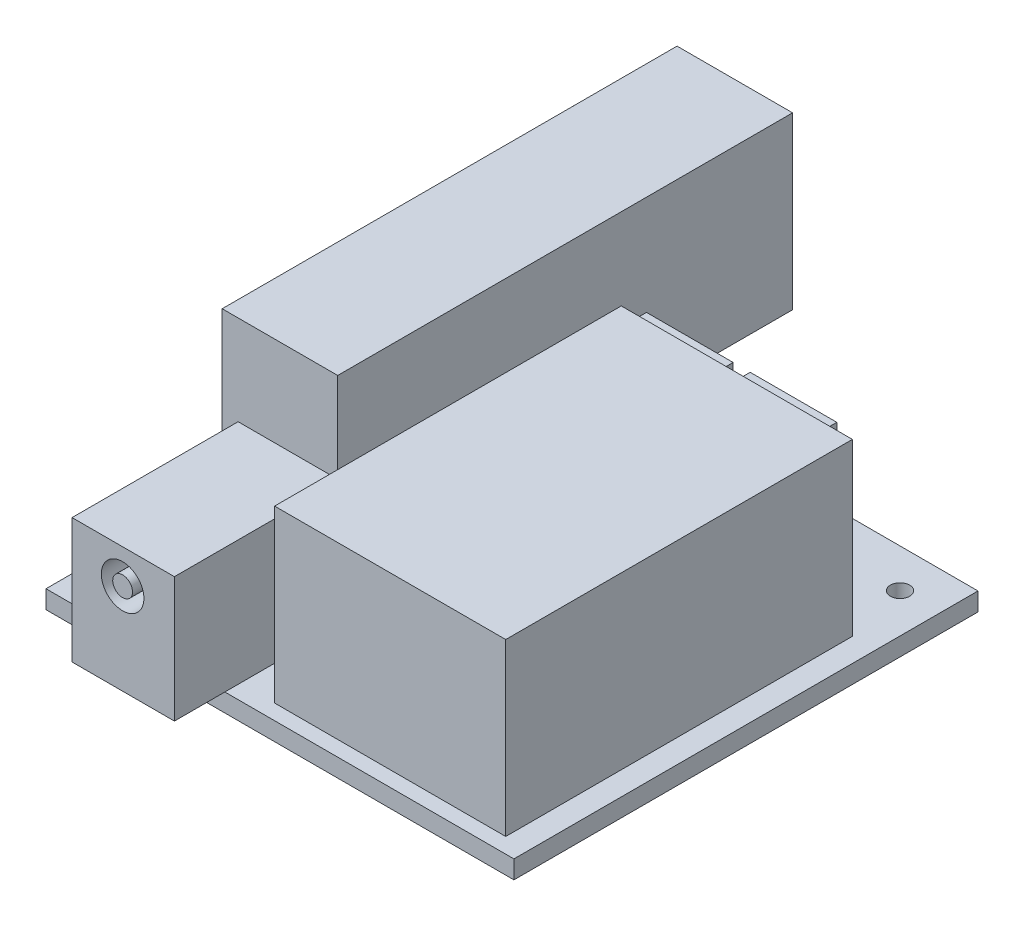
SolidWorks part; units mm, degrees
ref_plane "Front Plane" through (0, 0, 0) normal (0, 0, 1) x (1, 0, 0)
ref_plane "Top Plane" through (0, 0, 0) normal (0, 1, 0) x (1, 0, 0)
ref_plane "Right Plane" through (0, 0, 0) normal (1, 0, 0) x (0, 0, -1)
sketch "Sketch3" plane through (0, 0, 0) normal (0, 1, 0) x (1, 0, 0)
  line L0 (14.8, 40.91) -> (55.9481, 40.91)
  line L1 (55.9481, 0.1) -> (14.8, 0.1)
  line L2 (14.8, 0.1) -> (14.8, 40.91)
  line L3 (55.9481, 40.91) -> (55.9481, 0.1)
  line L4 (34.9492, 34.1547) -> (36.0339, 34.1547)
  line L5 (35.4915, 34.697) -> (35.4915, 33.6124)
  line L6 (24.5242, 18.5347) -> (25.6089, 18.5347)
  line L7 (25.0665, 19.077) -> (25.0665, 17.9924)
  line L8 (16.9042, 18.5347) -> (17.9889, 18.5347)
  line L9 (19.4442, 18.5347) -> (20.5289, 18.5347)
  line L10 (29.8692, 34.1547) -> (30.9539, 34.1547)
  line L11 (33.4939, 34.697) -> (33.2227, 34.9682)
  line L12 (33.2227, 34.9682) -> (32.6804, 34.9682)
  line L13 (32.6804, 34.9682) -> (32.4092, 34.697)
  line L14 (32.4092, 34.697) -> (32.4092, 34.4259)
  line L15 (32.4092, 34.4259) -> (32.6804, 34.1547)
  line L16 (32.6804, 34.1547) -> (33.2227, 34.1547)
  line L17 (33.2227, 34.1547) -> (33.4939, 33.8835)
  line L18 (33.4939, 33.8835) -> (33.4939, 33.6124)
  line L19 (33.4939, 33.6124) -> (33.2227, 33.3412)
  line L20 (33.2227, 33.3412) -> (32.6804, 33.3412)
  line L21 (32.6804, 33.3412) -> (32.4092, 33.6124)
  line L22 (23.0689, 19.077) -> (22.7977, 19.3482)
  line L23 (22.7977, 19.3482) -> (22.2554, 19.3482)
  line L24 (22.2554, 19.3482) -> (21.9842, 19.077)
  line L25 (21.9842, 19.077) -> (21.9842, 18.8059)
  line L26 (21.9842, 18.8059) -> (22.2554, 18.5347)
  line L27 (22.2554, 18.5347) -> (22.7977, 18.5347)
  line L28 (22.7977, 18.5347) -> (23.0689, 18.2635)
  line L29 (23.0689, 18.2635) -> (23.0689, 17.9924)
  line L30 (23.0689, 17.9924) -> (22.7977, 17.7212)
  line L31 (22.7977, 17.7212) -> (22.2554, 17.7212)
  line L32 (22.2554, 17.7212) -> (21.9842, 17.9924)
  line L33 (41.5292, 34.1547) -> (42.6139, 34.1547)
  line L34 (42.0715, 34.697) -> (42.0715, 33.6124)
  line L35 (45.2539, 34.697) -> (44.9827, 34.9682)
  line L36 (44.9827, 34.9682) -> (44.4404, 34.9682)
  line L37 (44.4404, 34.9682) -> (44.1692, 34.697)
  line L38 (44.1692, 34.697) -> (44.1692, 34.4259)
  line L39 (44.1692, 34.4259) -> (44.4404, 34.1547)
  line L40 (44.4404, 34.1547) -> (44.9827, 34.1547)
  line L41 (44.9827, 34.1547) -> (45.2539, 33.8835)
  line L42 (45.2539, 33.8835) -> (45.2539, 33.6124)
  line L43 (45.2539, 33.6124) -> (44.9827, 33.3412)
  line L44 (44.9827, 33.3412) -> (44.4404, 33.3412)
  line L45 (44.4404, 33.3412) -> (44.1692, 33.6124)
  line L46 (39.0892, 34.1547) -> (40.1739, 34.1547)
  line L47 (19.8854, 29.7952) -> (19.8854, 28.7105)
  line L48 (19.8854, 28.7105) -> (20.4277, 28.1682)
  line L49 (20.4277, 28.1682) -> (20.9701, 28.7105)
  line L50 (20.9701, 28.7105) -> (20.9701, 29.7952)
  line L51 (21.5226, 28.4394) -> (21.5226, 29.524)
  line L52 (21.5226, 29.524) -> (21.7937, 29.7952)
  line L53 (21.7937, 29.7952) -> (22.3361, 29.7952)
  line L54 (22.3361, 29.7952) -> (22.6072, 29.524)
  line L55 (22.6072, 29.524) -> (22.6072, 28.4394)
  line L56 (22.6072, 28.4394) -> (22.3361, 28.1682)
  line L57 (22.3361, 28.1682) -> (21.7937, 28.1682)
  line L58 (21.7937, 28.1682) -> (21.5226, 28.4394)
  line L59 (21.5226, 28.4394) -> (22.6072, 29.524)
  line L60 (23.1597, 28.1682) -> (23.1597, 28.4394)
  line L61 (23.1597, 28.4394) -> (23.4309, 28.4394)
  line L62 (23.4309, 28.4394) -> (23.4309, 28.1682)
  line L63 (23.4309, 28.1682) -> (23.1597, 28.1682)
  line L64 (23.9783, 28.4394) -> (23.9783, 29.524)
  line L65 (23.9783, 29.524) -> (24.2495, 29.7952)
  line L66 (24.2495, 29.7952) -> (24.7918, 29.7952)
  line L67 (24.7918, 29.7952) -> (25.063, 29.524)
  line L68 (25.063, 29.524) -> (25.063, 28.4394)
  line L69 (25.063, 28.4394) -> (24.7918, 28.1682)
  line L70 (24.7918, 28.1682) -> (24.2495, 28.1682)
  line L71 (24.2495, 28.1682) -> (23.9783, 28.4394)
  line L72 (23.9783, 28.4394) -> (25.063, 29.524)
  line L73 (25.6155, 28.1682) -> (25.6155, 28.4394)
  line L74 (25.6155, 28.4394) -> (25.8866, 28.4394)
  line L75 (25.8866, 28.4394) -> (25.8866, 28.1682)
  line L76 (25.8866, 28.1682) -> (25.6155, 28.1682)
  line L77 (26.434, 29.2529) -> (26.9764, 29.7952)
  line L78 (26.9764, 29.7952) -> (26.9764, 28.1682)
  line L79 (26.434, 28.1682) -> (27.5187, 28.1682)
  line L80 (22.3969, 31.0682) -> (22.3969, 32.6952)
  line L81 (22.3969, 32.6952) -> (23.2104, 32.6952)
  line L82 (23.2104, 32.6952) -> (23.4815, 32.424)
  line L83 (23.4815, 32.424) -> (23.4815, 31.8817)
  line L84 (23.4815, 31.8817) -> (23.2104, 31.6105)
  line L85 (23.2104, 31.6105) -> (22.3969, 31.6105)
  line L86 (24.034, 32.6952) -> (24.034, 31.0682)
  line L87 (24.034, 31.0682) -> (24.8475, 31.0682)
  line L88 (24.8475, 31.0682) -> (25.1187, 31.3394)
  line L89 (25.1187, 31.3394) -> (25.1187, 32.424)
  line L90 (25.1187, 32.424) -> (24.8475, 32.6952)
  line L91 (24.8475, 32.6952) -> (24.034, 32.6952)
  line L92 (41.9597, 3.4952) -> (41.9597, 2.1394)
  line L93 (41.9597, 2.1394) -> (42.2309, 1.8682)
  line L94 (42.2309, 1.8682) -> (42.7732, 1.8682)
  line L95 (42.7732, 1.8682) -> (43.0444, 2.1394)
  line L96 (43.0444, 2.1394) -> (43.0444, 3.4952)
  line L97 (44.6815, 3.224) -> (44.4104, 3.4952)
  line L98 (44.4104, 3.4952) -> (43.868, 3.4952)
  line L99 (43.868, 3.4952) -> (43.5969, 3.224)
  line L100 (43.5969, 3.224) -> (43.5969, 2.9529)
  line L101 (43.5969, 2.9529) -> (43.868, 2.6817)
  line L102 (43.868, 2.6817) -> (44.4104, 2.6817)
  line L103 (44.4104, 2.6817) -> (44.6815, 2.4105)
  line L104 (44.6815, 2.4105) -> (44.6815, 2.1394)
  line L105 (44.6815, 2.1394) -> (44.4104, 1.8682)
  line L106 (44.4104, 1.8682) -> (43.868, 1.8682)
  line L107 (43.868, 1.8682) -> (43.5969, 2.1394)
  line L108 (45.234, 1.8682) -> (45.234, 3.4952)
  line L109 (45.234, 3.4952) -> (46.0475, 3.4952)
  line L110 (46.0475, 3.4952) -> (46.3187, 3.224)
  line L111 (46.3187, 3.224) -> (46.3187, 2.9529)
  line L112 (46.3187, 2.9529) -> (46.0475, 2.6817)
  line L113 (46.0475, 2.6817) -> (46.3187, 2.4105)
  line L114 (46.3187, 2.4105) -> (46.3187, 2.1394)
  line L115 (46.3187, 2.1394) -> (46.0475, 1.8682)
  line L116 (46.0475, 1.8682) -> (45.234, 1.8682)
  line L117 (45.234, 2.6817) -> (46.0475, 2.6817)
  line L118 (39.121, 19.9097) -> (38.9981, 20.0325)
  line L119 (38.9981, 20.0325) -> (38.7524, 20.0325)
  line L120 (38.7524, 20.0325) -> (38.6295, 19.9097)
  line L121 (38.6295, 19.9097) -> (38.6295, 19.4182)
  line L122 (38.6295, 19.4182) -> (38.7524, 19.2953)
  line L123 (38.7524, 19.2953) -> (38.9981, 19.2953)
  line L124 (38.9981, 19.2953) -> (39.121, 19.4182)
  line L125 (39.3779, 20.0325) -> (39.5008, 20.0325)
  line L126 (39.5008, 20.0325) -> (39.5008, 19.2953)
  line L127 (39.3779, 19.2953) -> (39.6236, 19.2953)
  line L128 (39.9997, 19.2953) -> (40.2455, 19.2953)
  line L129 (40.2455, 19.2953) -> (40.3683, 19.4182)
  line L130 (40.3683, 19.4182) -> (40.3683, 19.6639)
  line L131 (40.3683, 19.6639) -> (40.2455, 19.7868)
  line L132 (40.2455, 19.7868) -> (39.9997, 19.7868)
  line L133 (39.9997, 19.7868) -> (39.8769, 19.6639)
  line L134 (39.8769, 19.6639) -> (39.8769, 19.4182)
  line L135 (39.8769, 19.4182) -> (39.9997, 19.2953)
  line L136 (40.6253, 19.2953) -> (40.9939, 19.2953)
  line L137 (40.9939, 19.2953) -> (41.1168, 19.4182)
  line L138 (41.1168, 19.4182) -> (40.9939, 19.541)
  line L139 (40.9939, 19.541) -> (40.7481, 19.541)
  line L140 (40.7481, 19.541) -> (40.6253, 19.6639)
  line L141 (40.6253, 19.6639) -> (40.7481, 19.7868)
  line L142 (40.7481, 19.7868) -> (41.1168, 19.7868)
  line L143 (41.7423, 19.2953) -> (41.4965, 19.2953)
  line L144 (41.4965, 19.2953) -> (41.3737, 19.4182)
  line L145 (41.3737, 19.4182) -> (41.3737, 19.6639)
  line L146 (41.3737, 19.6639) -> (41.4965, 19.7868)
  line L147 (41.4965, 19.7868) -> (41.7423, 19.7868)
  line L148 (41.7423, 19.7868) -> (41.8652, 19.6639)
  line L149 (41.8652, 19.6639) -> (41.8652, 19.541)
  line L150 (41.8652, 19.541) -> (41.3737, 19.541)
  line L151 (42.8705, 19.6639) -> (43.362, 19.6639)
  line L152 (44.3673, 19.2953) -> (44.3673, 20.0325)
  line L153 (44.3673, 20.0325) -> (44.8588, 20.0325)
  line L154 (44.3673, 19.6639) -> (44.6131, 19.6639)
  line L155 (45.4844, 19.2953) -> (45.2386, 19.2953)
  line L156 (45.2386, 19.2953) -> (45.1158, 19.4182)
  line L157 (45.1158, 19.4182) -> (45.1158, 19.6639)
  line L158 (45.1158, 19.6639) -> (45.2386, 19.7868)
  line L159 (45.2386, 19.7868) -> (45.4844, 19.7868)
  line L160 (45.4844, 19.7868) -> (45.6072, 19.6639)
  line L161 (45.6072, 19.6639) -> (45.6072, 19.541)
  line L162 (45.6072, 19.541) -> (45.1158, 19.541)
  line L163 (46.2328, 19.2953) -> (45.987, 19.2953)
  line L164 (45.987, 19.2953) -> (45.8642, 19.4182)
  line L165 (45.8642, 19.4182) -> (45.8642, 19.6639)
  line L166 (45.8642, 19.6639) -> (45.987, 19.7868)
  line L167 (45.987, 19.7868) -> (46.2328, 19.7868)
  line L168 (46.2328, 19.7868) -> (46.3557, 19.6639)
  line L169 (46.3557, 19.6639) -> (46.3557, 19.541)
  line L170 (46.3557, 19.541) -> (45.8642, 19.541)
  line L171 (47.1041, 20.0325) -> (47.1041, 19.2953)
  line L172 (47.1041, 19.2953) -> (46.7355, 19.2953)
  line L173 (46.7355, 19.2953) -> (46.6126, 19.4182)
  line L174 (46.6126, 19.4182) -> (46.6126, 19.6639)
  line L175 (46.6126, 19.6639) -> (46.7355, 19.7868)
  line L176 (46.7355, 19.7868) -> (47.1041, 19.7868)
  line L177 (47.7296, 19.2953) -> (47.4839, 19.2953)
  line L178 (47.4839, 19.2953) -> (47.361, 19.4182)
  line L179 (47.361, 19.4182) -> (47.361, 19.6639)
  line L180 (47.361, 19.6639) -> (47.4839, 19.7868)
  line L181 (47.4839, 19.7868) -> (47.7296, 19.7868)
  line L182 (47.7296, 19.7868) -> (47.8525, 19.6639)
  line L183 (47.8525, 19.6639) -> (47.8525, 19.541)
  line L184 (47.8525, 19.541) -> (47.361, 19.541)
  line L185 (48.1094, 19.2953) -> (48.1094, 19.7868)
  line L186 (48.1094, 19.541) -> (48.3552, 19.7868)
  line L187 (48.3552, 19.7868) -> (48.478, 19.7868)
  line L188 (38.9981, 18.8133) -> (38.7524, 18.8133)
  line L189 (38.7524, 18.8133) -> (38.6295, 18.6905)
  line L190 (38.6295, 18.6905) -> (38.6295, 18.199)
  line L191 (38.6295, 18.199) -> (38.7524, 18.0761)
  line L192 (38.7524, 18.0761) -> (38.9981, 18.0761)
  line L193 (38.9981, 18.0761) -> (39.121, 18.199)
  line L194 (39.121, 18.199) -> (39.121, 18.6905)
  line L195 (39.121, 18.6905) -> (38.9981, 18.8133)
  line L196 (39.3779, 17.8304) -> (39.3779, 18.5676)
  line L197 (39.3779, 18.5676) -> (39.7465, 18.5676)
  line L198 (39.7465, 18.5676) -> (39.8694, 18.4447)
  line L199 (39.8694, 18.4447) -> (39.8694, 18.199)
  line L200 (39.8694, 18.199) -> (39.7465, 18.0761)
  line L201 (39.7465, 18.0761) -> (39.3779, 18.0761)
  line L202 (40.4949, 18.0761) -> (40.2492, 18.0761)
  line L203 (40.2492, 18.0761) -> (40.1263, 18.199)
  line L204 (40.1263, 18.199) -> (40.1263, 18.4447)
  line L205 (40.1263, 18.4447) -> (40.2492, 18.5676)
  line L206 (40.2492, 18.5676) -> (40.4949, 18.5676)
  line L207 (40.4949, 18.5676) -> (40.6178, 18.4447)
  line L208 (40.6178, 18.4447) -> (40.6178, 18.3218)
  line L209 (40.6178, 18.3218) -> (40.1263, 18.3218)
  line L210 (40.8747, 18.0761) -> (40.8747, 18.5676)
  line L211 (40.8747, 18.5676) -> (41.2433, 18.5676)
  line L212 (41.2433, 18.5676) -> (41.3662, 18.4447)
  line L213 (41.3662, 18.4447) -> (41.3662, 18.0761)
  line L214 (42.3716, 18.4447) -> (42.8631, 18.4447)
  line L215 (44.3599, 18.6905) -> (44.237, 18.8133)
  line L216 (44.237, 18.8133) -> (43.9913, 18.8133)
  line L217 (43.9913, 18.8133) -> (43.8684, 18.6905)
  line L218 (43.8684, 18.6905) -> (43.8684, 18.5676)
  line L219 (43.8684, 18.5676) -> (43.9913, 18.4447)
  line L220 (43.9913, 18.4447) -> (44.237, 18.4447)
  line L221 (44.237, 18.4447) -> (44.3599, 18.3218)
  line L222 (44.3599, 18.3218) -> (44.3599, 18.199)
  line L223 (44.3599, 18.199) -> (44.237, 18.0761)
  line L224 (44.237, 18.0761) -> (43.9913, 18.0761)
  line L225 (43.9913, 18.0761) -> (43.8684, 18.199)
  line L226 (44.7397, 18.6905) -> (44.7397, 18.199)
  line L227 (44.7397, 18.199) -> (44.8626, 18.0761)
  line L228 (44.6168, 18.5676) -> (44.8626, 18.5676)
  line L229 (45.2386, 18.5676) -> (45.4844, 18.5676)
  line L230 (45.4844, 18.5676) -> (45.6072, 18.4447)
  line L231 (45.6072, 18.4447) -> (45.6072, 18.0761)
  line L232 (45.6072, 18.0761) -> (45.2386, 18.0761)
  line L233 (45.2386, 18.0761) -> (45.1158, 18.199)
  line L234 (45.1158, 18.199) -> (45.2386, 18.3218)
  line L235 (45.2386, 18.3218) -> (45.6072, 18.3218)
  line L236 (45.987, 18.6905) -> (45.987, 18.199)
  line L237 (45.987, 18.199) -> (46.1099, 18.0761)
  line L238 (45.8642, 18.5676) -> (46.1099, 18.5676)
  line L239 (46.3631, 18.5676) -> (46.486, 18.5676)
  line L240 (46.486, 18.5676) -> (46.486, 18.0761)
  line L241 (46.3631, 18.0761) -> (46.6089, 18.0761)
  line L242 (46.486, 18.9362) -> (46.486, 18.8133)
  line L243 (46.9849, 18.0761) -> (47.2307, 18.0761)
  line L244 (47.2307, 18.0761) -> (47.3535, 18.199)
  line L245 (47.3535, 18.199) -> (47.3535, 18.4447)
  line L246 (47.3535, 18.4447) -> (47.2307, 18.5676)
  line L247 (47.2307, 18.5676) -> (46.9849, 18.5676)
  line L248 (46.9849, 18.5676) -> (46.8621, 18.4447)
  line L249 (46.8621, 18.4447) -> (46.8621, 18.199)
  line L250 (46.8621, 18.199) -> (46.9849, 18.0761)
  line L251 (47.6105, 18.0761) -> (47.6105, 18.5676)
  line L252 (47.6105, 18.5676) -> (47.9791, 18.5676)
  line L253 (47.9791, 18.5676) -> (48.102, 18.4447)
  line L254 (48.102, 18.4447) -> (48.102, 18.0761)
  line L255 (37.2477, 21.2489) -> (37.4044, 21.0921)
  line L256 (37.4044, 21.0921) -> (37.5612, 21.0921)
  line L257 (37.5612, 21.0921) -> (37.718, 21.2489)
  line L258 (37.718, 21.2489) -> (37.718, 22.0327)
  line L259 (37.5612, 22.0327) -> (37.8747, 22.0327)
  line L260 (38.1832, 21.7192) -> (38.1832, 21.2489)
  line L261 (38.1832, 21.2489) -> (38.34, 21.0921)
  line L262 (38.34, 21.0921) -> (38.8103, 21.0921)
  line L263 (38.8103, 21.0921) -> (38.8103, 21.7192)
  line L264 (39.1187, 21.0921) -> (39.1187, 21.7192)
  line L265 (39.1187, 21.7192) -> (39.2755, 21.7192)
  line L266 (39.2755, 21.7192) -> (39.4322, 21.5624)
  line L267 (39.4322, 21.5624) -> (39.4322, 21.0921)
  line L268 (39.4322, 21.5624) -> (39.589, 21.7192)
  line L269 (39.589, 21.7192) -> (39.7458, 21.5624)
  line L270 (39.7458, 21.5624) -> (39.7458, 21.0921)
  line L271 (40.0542, 20.7786) -> (40.0542, 21.7192)
  line L272 (40.0542, 21.7192) -> (40.5245, 21.7192)
  line L273 (40.5245, 21.7192) -> (40.6813, 21.5624)
  line L274 (40.6813, 21.5624) -> (40.6813, 21.2489)
  line L275 (40.6813, 21.2489) -> (40.5245, 21.0921)
  line L276 (40.5245, 21.0921) -> (40.0542, 21.0921)
  line L277 (41.46, 21.0921) -> (41.1465, 21.0921)
  line L278 (41.1465, 21.0921) -> (40.9897, 21.2489)
  line L279 (40.9897, 21.2489) -> (40.9897, 21.5624)
  line L280 (40.9897, 21.5624) -> (41.1465, 21.7192)
  line L281 (41.1465, 21.7192) -> (41.46, 21.7192)
  line L282 (41.46, 21.7192) -> (41.6168, 21.5624)
  line L283 (41.6168, 21.5624) -> (41.6168, 21.4056)
  line L284 (41.6168, 21.4056) -> (40.9897, 21.4056)
  line L285 (41.9253, 21.0921) -> (41.9253, 21.7192)
  line L286 (41.9253, 21.4056) -> (42.2388, 21.7192)
  line L287 (42.2388, 21.7192) -> (42.3956, 21.7192)
  line L288 (43.7971, 21.0921) -> (44.1107, 21.0921)
  line L289 (44.1107, 21.0921) -> (44.2674, 21.2489)
  line L290 (44.2674, 21.2489) -> (44.2674, 21.5624)
  line L291 (44.2674, 21.5624) -> (44.1107, 21.7192)
  line L292 (44.1107, 21.7192) -> (43.7971, 21.7192)
  line L293 (43.7971, 21.7192) -> (43.6404, 21.5624)
  line L294 (43.6404, 21.5624) -> (43.6404, 21.2489)
  line L295 (43.6404, 21.2489) -> (43.7971, 21.0921)
  line L296 (44.5759, 20.7786) -> (44.5759, 21.7192)
  line L297 (44.5759, 21.7192) -> (45.0462, 21.7192)
  line L298 (45.0462, 21.7192) -> (45.203, 21.5624)
  line L299 (45.203, 21.5624) -> (45.203, 21.2489)
  line L300 (45.203, 21.2489) -> (45.0462, 21.0921)
  line L301 (45.0462, 21.0921) -> (44.5759, 21.0921)
  line L302 (45.6682, 21.8759) -> (45.6682, 21.2489)
  line L303 (45.6682, 21.2489) -> (45.8249, 21.0921)
  line L304 (45.5114, 21.7192) -> (45.8249, 21.7192)
  line L305 (46.1351, 21.7192) -> (46.2919, 21.7192)
  line L306 (46.2919, 21.7192) -> (46.2919, 21.0921)
  line L307 (46.1351, 21.0921) -> (46.4486, 21.0921)
  line L308 (46.2919, 22.1895) -> (46.2919, 22.0327)
  line L309 (46.9155, 21.0921) -> (47.2291, 21.0921)
  line L310 (47.2291, 21.0921) -> (47.3858, 21.2489)
  line L311 (47.3858, 21.2489) -> (47.3858, 21.5624)
  line L312 (47.3858, 21.5624) -> (47.2291, 21.7192)
  line L313 (47.2291, 21.7192) -> (46.9155, 21.7192)
  line L314 (46.9155, 21.7192) -> (46.7588, 21.5624)
  line L315 (46.7588, 21.5624) -> (46.7588, 21.2489)
  line L316 (46.7588, 21.2489) -> (46.9155, 21.0921)
  line L317 (47.6943, 21.0921) -> (47.6943, 21.7192)
  line L318 (47.6943, 21.7192) -> (48.1646, 21.7192)
  line L319 (48.1646, 21.7192) -> (48.3214, 21.5624)
  line L320 (48.3214, 21.5624) -> (48.3214, 21.0921)
  line L321 (48.6298, 21.0921) -> (49.1001, 21.0921)
  line L322 (49.1001, 21.0921) -> (49.2569, 21.2489)
  line L323 (49.2569, 21.2489) -> (49.1001, 21.4056)
  line L324 (49.1001, 21.4056) -> (48.7866, 21.4056)
  line L325 (48.7866, 21.4056) -> (48.6298, 21.5624)
  line L326 (48.6298, 21.5624) -> (48.7866, 21.7192)
  line L327 (48.7866, 21.7192) -> (49.2569, 21.7192)
  line L328 (49.5653, 21.7192) -> (49.7221, 21.7192)
  line L329 (49.7221, 21.7192) -> (49.7221, 21.5624)
  line L330 (49.7221, 21.5624) -> (49.5653, 21.5624)
  line L331 (49.5653, 21.5624) -> (49.5653, 21.7192)
  line L332 (49.5653, 21.2489) -> (49.7221, 21.2489)
  line L333 (49.7221, 21.2489) -> (49.7221, 21.0921)
  line L334 (49.7221, 21.0921) -> (49.5653, 21.0921)
  line L335 (49.5653, 21.0921) -> (49.5653, 21.2489)
  line L336 (29.0298, 20.2321) -> (29.0298, 21.1727)
  line L337 (29.0298, 21.1727) -> (29.6569, 21.1727)
  line L338 (29.0298, 20.7024) -> (29.3434, 20.7024)
  line L339 (29.9653, 20.2321) -> (30.5924, 21.1727)
  line L340 (31.5279, 21.0159) -> (31.3712, 21.1727)
  line L341 (31.3712, 21.1727) -> (31.0576, 21.1727)
  line L342 (31.0576, 21.1727) -> (30.9009, 21.0159)
  line L343 (30.9009, 21.0159) -> (30.9009, 20.8592)
  line L344 (30.9009, 20.8592) -> (31.0576, 20.7024)
  line L345 (31.0576, 20.7024) -> (31.3712, 20.7024)
  line L346 (31.3712, 20.7024) -> (31.5279, 20.5456)
  line L347 (31.5279, 20.5456) -> (31.5279, 20.3889)
  line L348 (31.5279, 20.3889) -> (31.3712, 20.2321)
  line L349 (31.3712, 20.2321) -> (31.0576, 20.2321)
  line L350 (31.0576, 20.2321) -> (30.9009, 20.3889)
  line L351 (27.8604, 18.3946) -> (28.0172, 18.3946)
  line L352 (28.0172, 18.3946) -> (28.174, 18.5513)
  line L353 (28.174, 18.5513) -> (28.174, 19.3352)
  line L354 (28.174, 19.8055) -> (28.174, 19.6487)
  line L355 (28.4841, 19.3352) -> (28.4841, 18.8649)
  line L356 (28.4841, 18.8649) -> (28.6409, 18.7081)
  line L357 (28.6409, 18.7081) -> (29.1112, 18.7081)
  line L358 (29.1112, 18.7081) -> (29.1112, 19.3352)
  line L359 (29.4196, 18.7081) -> (29.4196, 19.3352)
  line L360 (29.4196, 19.3352) -> (29.5764, 19.3352)
  line L361 (29.5764, 19.3352) -> (29.7332, 19.1784)
  line L362 (29.7332, 19.1784) -> (29.7332, 18.7081)
  line L363 (29.7332, 19.1784) -> (29.8899, 19.3352)
  line L364 (29.8899, 19.3352) -> (30.0467, 19.1784)
  line L365 (30.0467, 19.1784) -> (30.0467, 18.7081)
  line L366 (30.3551, 18.3946) -> (30.3551, 19.3352)
  line L367 (30.3551, 19.3352) -> (30.8254, 19.3352)
  line L368 (30.8254, 19.3352) -> (30.9822, 19.1784)
  line L369 (30.9822, 19.1784) -> (30.9822, 18.8649)
  line L370 (30.9822, 18.8649) -> (30.8254, 18.7081)
  line L371 (30.8254, 18.7081) -> (30.3551, 18.7081)
  line L372 (31.761, 18.7081) -> (31.4474, 18.7081)
  line L373 (31.4474, 18.7081) -> (31.2907, 18.8649)
  line L374 (31.2907, 18.8649) -> (31.2907, 19.1784)
  line L375 (31.2907, 19.1784) -> (31.4474, 19.3352)
  line L376 (31.4474, 19.3352) -> (31.761, 19.3352)
  line L377 (31.761, 19.3352) -> (31.9177, 19.1784)
  line L378 (31.9177, 19.1784) -> (31.9177, 19.0216)
  line L379 (31.9177, 19.0216) -> (31.2907, 19.0216)
  line L380 (32.2262, 18.7081) -> (32.2262, 19.3352)
  line L381 (32.2262, 19.0216) -> (32.5397, 19.3352)
  line L382 (32.5397, 19.3352) -> (32.6965, 19.3352)
  line L383 (21.303, 16.075) -> (21.938, 16.71)
  line L384 (21.938, 16.71) -> (23.208, 16.71)
  line L385 (23.208, 16.71) -> (23.843, 16.075)
  line L386 (23.843, 16.075) -> (23.843, 14.805)
  line L387 (23.843, 14.805) -> (23.208, 14.17)
  line L388 (23.208, 14.17) -> (21.938, 14.17)
  line L389 (21.938, 14.17) -> (21.303, 14.805)
  line L390 (16.858, 16.71) -> (18.128, 16.71)
  line L391 (18.128, 16.71) -> (18.763, 16.075)
  line L392 (18.763, 16.075) -> (18.763, 14.805)
  line L393 (18.763, 14.805) -> (18.128, 14.17)
  line L394 (18.763, 16.075) -> (19.398, 16.71)
  line L395 (19.398, 16.71) -> (20.668, 16.71)
  line L396 (20.668, 16.71) -> (21.303, 16.075)
  line L397 (21.303, 16.075) -> (21.303, 14.805)
  line L398 (21.303, 14.805) -> (20.668, 14.17)
  line L399 (20.668, 14.17) -> (19.398, 14.17)
  line L400 (19.398, 14.17) -> (18.763, 14.805)
  line L401 (16.223, 16.075) -> (16.223, 14.805)
  line L402 (16.858, 16.71) -> (16.223, 16.075)
  line L403 (16.223, 14.805) -> (16.858, 14.17)
  line L404 (18.128, 14.17) -> (16.858, 14.17)
  line L405 (24.478, 16.71) -> (25.748, 16.71)
  line L406 (25.748, 16.71) -> (26.383, 16.075)
  line L407 (26.383, 16.075) -> (26.383, 14.805)
  line L408 (26.383, 14.805) -> (25.748, 14.17)
  line L409 (24.478, 16.71) -> (23.843, 16.075)
  line L410 (23.843, 14.805) -> (24.478, 14.17)
  line L411 (25.748, 14.17) -> (24.478, 14.17)
  line L412 (17.493, 14.6272) -> (17.493, 16.2528)
  line L413 (17.493, 14.6272) -> (17.493, 16.2528)
  line L414 (17.493, 14.5256) -> (17.493, 16.3544)
  line L415 (17.493, 14.5256) -> (17.493, 16.3544)
  line L416 (20.033, 14.6272) -> (20.033, 16.2528)
  line L417 (20.033, 14.6272) -> (20.033, 16.2528)
  line L418 (20.033, 14.5256) -> (20.033, 16.3544)
  line L419 (20.033, 14.5256) -> (20.033, 16.3544)
  line L420 (22.573, 14.6272) -> (22.573, 16.2528)
  line L421 (22.573, 14.6272) -> (22.573, 16.2528)
  line L422 (22.573, 14.5256) -> (22.573, 16.3544)
  line L423 (22.573, 14.5256) -> (22.573, 16.3544)
  line L424 (25.113, 14.6272) -> (25.113, 16.2528)
  line L425 (25.113, 14.6272) -> (25.113, 16.2528)
  line L426 (25.113, 14.5256) -> (25.113, 16.3544)
  line L427 (25.113, 14.5256) -> (25.113, 16.3544)
  line L428 (20.0738, 20.2158) -> (20.0738, 20.9954)
  line L429 (20.0738, 20.9954) -> (20.4636, 21.3852)
  line L430 (20.4636, 21.3852) -> (20.8534, 20.9954)
  line L431 (20.8534, 20.9954) -> (20.8534, 20.2158)
  line L432 (20.0738, 20.8005) -> (20.8534, 20.8005)
  line L433 (21.2432, 20.2158) -> (21.2432, 21.3852)
  line L434 (21.2432, 21.3852) -> (21.633, 20.9954)
  line L435 (21.633, 20.9954) -> (22.0228, 21.3852)
  line L436 (22.0228, 21.3852) -> (22.0228, 20.2158)
  line L437 (22.4126, 20.2158) -> (22.4126, 21.3852)
  line L438 (22.4126, 21.3852) -> (22.9973, 21.3852)
  line L439 (22.9973, 21.3852) -> (23.1922, 21.1903)
  line L440 (23.1922, 21.1903) -> (23.1922, 20.8005)
  line L441 (23.1922, 20.8005) -> (22.9973, 20.6056)
  line L442 (22.9973, 20.6056) -> (22.4126, 20.6056)
  line L443 (29.43, 12.96) -> (31.97, 12.96)
  line L444 (31.97, 18.04) -> (31.97, 12.96)
  line L445 (29.43, 12.96) -> (29.43, 15.5)
  line L446 (29.43, 15.5) -> (29.43, 18.04)
  line L447 (29.43, 18.04) -> (31.97, 18.04)
  line L448 (29.43, 15.5) -> (31.97, 15.5)
  line L449 (31.1064, 16.9384) -> (31.1064, 16.6016)
  line L450 (31.1064, 16.6016) -> (30.8684, 16.3636)
  line L451 (30.8684, 16.3636) -> (30.5316, 16.3636)
  line L452 (30.5316, 16.3636) -> (30.2936, 16.6016)
  line L453 (30.2936, 16.6016) -> (30.2936, 16.9384)
  line L454 (30.2936, 16.9384) -> (30.5316, 17.1764)
  line L455 (30.5316, 17.1764) -> (30.8684, 17.1764)
  line L456 (30.8684, 17.1764) -> (31.1064, 16.9384)
  line L457 (31.1064, 16.9384) -> (31.1064, 16.6016)
  line L458 (31.1064, 16.9384) -> (31.1064, 16.6016)
  line L459 (31.1064, 16.6016) -> (30.8684, 16.3636)
  line L460 (30.8684, 16.3636) -> (30.5316, 16.3636)
  line L461 (30.5316, 16.3636) -> (30.2936, 16.6016)
  line L462 (30.2936, 16.6016) -> (30.2936, 16.9384)
  line L463 (30.2936, 16.9384) -> (30.5316, 17.1764)
  line L464 (30.5316, 17.1764) -> (30.8684, 17.1764)
  line L465 (30.8684, 17.1764) -> (31.1064, 16.9384)
  line L466 (31.1064, 16.9384) -> (31.1064, 16.6016)
  line L467 (31.1572, 16.9595) -> (31.1572, 16.5805)
  line L468 (31.1572, 16.5805) -> (30.8895, 16.3128)
  line L469 (30.8895, 16.3128) -> (30.5105, 16.3128)
  line L470 (30.5105, 16.3128) -> (30.2428, 16.5805)
  line L471 (30.2428, 16.5805) -> (30.2428, 16.9595)
  line L472 (30.2428, 16.9595) -> (30.5105, 17.2272)
  line L473 (30.5105, 17.2272) -> (30.8895, 17.2272)
  line L474 (30.8895, 17.2272) -> (31.1572, 16.9595)
  line L475 (31.1572, 16.9595) -> (31.1572, 16.5805)
  line L476 (31.1572, 16.9595) -> (31.1572, 16.5805)
  line L477 (31.1572, 16.5805) -> (30.8895, 16.3128)
  line L478 (30.8895, 16.3128) -> (30.5105, 16.3128)
  line L479 (30.5105, 16.3128) -> (30.2428, 16.5805)
  line L480 (30.2428, 16.5805) -> (30.2428, 16.9595)
  line L481 (30.2428, 16.9595) -> (30.5105, 17.2272)
  line L482 (30.5105, 17.2272) -> (30.8895, 17.2272)
  line L483 (30.8895, 17.2272) -> (31.1572, 16.9595)
  line L484 (31.1572, 16.9595) -> (31.1572, 16.5805)
  line L485 (36.143, 36.005) -> (34.873, 36.005)
  line L486 (34.873, 36.005) -> (34.238, 36.64)
  line L487 (34.238, 36.64) -> (34.238, 37.91)
  line L488 (34.238, 37.91) -> (34.873, 38.545)
  line L489 (34.238, 36.64) -> (33.603, 36.005)
  line L490 (33.603, 36.005) -> (32.333, 36.005)
  line L491 (32.333, 36.005) -> (31.698, 36.64)
  line L492 (31.698, 36.64) -> (31.698, 37.91)
  line L493 (31.698, 37.91) -> (32.333, 38.545)
  line L494 (32.333, 38.545) -> (33.603, 38.545)
  line L495 (33.603, 38.545) -> (34.238, 37.91)
  line L496 (36.778, 36.64) -> (36.778, 37.91)
  line L497 (36.143, 36.005) -> (36.778, 36.64)
  line L498 (36.778, 37.91) -> (36.143, 38.545)
  line L499 (34.873, 38.545) -> (36.143, 38.545)
  line L500 (31.698, 36.64) -> (31.063, 36.005)
  line L501 (31.063, 36.005) -> (29.793, 36.005)
  line L502 (29.793, 36.005) -> (29.158, 36.64)
  line L503 (29.158, 36.64) -> (29.158, 37.91)
  line L504 (29.158, 37.91) -> (29.793, 38.545)
  line L505 (29.793, 38.545) -> (31.063, 38.545)
  line L506 (31.063, 38.545) -> (31.698, 37.91)
  line L507 (35.508, 38.0878) -> (35.508, 36.4622)
  line L508 (35.508, 38.0878) -> (35.508, 36.4622)
  line L509 (35.508, 38.1894) -> (35.508, 36.3606)
  line L510 (35.508, 38.1894) -> (35.508, 36.3606)
  line L511 (32.968, 38.0878) -> (32.968, 36.4622)
  line L512 (32.968, 38.0878) -> (32.968, 36.4622)
  line L513 (32.968, 38.1894) -> (32.968, 36.3606)
  line L514 (32.968, 38.1894) -> (32.968, 36.3606)
  line L515 (30.428, 38.0878) -> (30.428, 36.4622)
  line L516 (30.428, 38.0878) -> (30.428, 36.4622)
  line L517 (30.428, 38.1894) -> (30.428, 36.3606)
  line L518 (30.428, 38.1894) -> (30.428, 36.3606)
  line L519 (25.5104, 37.8308) -> (25.5104, 39.0002)
  line L520 (25.5104, 39.0002) -> (26.0951, 39.0002)
  line L521 (26.0951, 39.0002) -> (26.29, 38.8053)
  line L522 (26.29, 38.8053) -> (26.29, 38.4155)
  line L523 (26.29, 38.4155) -> (26.0951, 38.2206)
  line L524 (26.0951, 38.2206) -> (25.5104, 38.2206)
  line L525 (26.6798, 37.8308) -> (27.0696, 37.8308)
  line L526 (26.8747, 37.8308) -> (26.8747, 39.0002)
  line L527 (26.6798, 39.0002) -> (27.0696, 39.0002)
  line L528 (27.4594, 37.8308) -> (27.4594, 39.0002)
  line L529 (27.4594, 39.0002) -> (28.0441, 39.0002)
  line L530 (28.0441, 39.0002) -> (28.239, 38.8053)
  line L531 (28.239, 38.8053) -> (28.239, 38.4155)
  line L532 (28.239, 38.4155) -> (28.0441, 38.2206)
  line L533 (28.0441, 38.2206) -> (27.4594, 38.2206)
  line L534 (27.8492, 38.2206) -> (28.239, 37.8308)
  line L535 (45.263, 36.005) -> (43.993, 36.005)
  line L536 (43.993, 36.005) -> (43.358, 36.64)
  line L537 (43.358, 36.64) -> (43.358, 37.91)
  line L538 (43.358, 37.91) -> (43.993, 38.545)
  line L539 (43.358, 36.64) -> (42.723, 36.005)
  line L540 (42.723, 36.005) -> (41.453, 36.005)
  line L541 (41.453, 36.005) -> (40.818, 36.64)
  line L542 (40.818, 36.64) -> (40.818, 37.91)
  line L543 (40.818, 37.91) -> (41.453, 38.545)
  line L544 (41.453, 38.545) -> (42.723, 38.545)
  line L545 (42.723, 38.545) -> (43.358, 37.91)
  line L546 (45.898, 36.64) -> (45.898, 37.91)
  line L547 (45.263, 36.005) -> (45.898, 36.64)
  line L548 (45.898, 37.91) -> (45.263, 38.545)
  line L549 (43.993, 38.545) -> (45.263, 38.545)
  line L550 (40.818, 36.64) -> (40.183, 36.005)
  line L551 (40.183, 36.005) -> (38.913, 36.005)
  line L552 (38.913, 36.005) -> (38.278, 36.64)
  line L553 (38.278, 36.64) -> (38.278, 37.91)
  line L554 (38.278, 37.91) -> (38.913, 38.545)
  line L555 (38.913, 38.545) -> (40.183, 38.545)
  line L556 (40.183, 38.545) -> (40.818, 37.91)
  line L557 (44.628, 38.0878) -> (44.628, 36.4622)
  line L558 (44.628, 38.0878) -> (44.628, 36.4622)
  line L559 (44.628, 38.1894) -> (44.628, 36.3606)
  line L560 (44.628, 38.1894) -> (44.628, 36.3606)
  line L561 (42.088, 38.0878) -> (42.088, 36.4622)
  line L562 (42.088, 38.0878) -> (42.088, 36.4622)
  line L563 (42.088, 38.1894) -> (42.088, 36.3606)
  line L564 (42.088, 38.1894) -> (42.088, 36.3606)
  line L565 (39.548, 38.0878) -> (39.548, 36.4622)
  line L566 (39.548, 38.0878) -> (39.548, 36.4622)
  line L567 (39.548, 38.1894) -> (39.548, 36.3606)
  line L568 (39.548, 38.1894) -> (39.548, 36.3606)
  line L569 (39.9914, 32.007) -> (39.8007, 32.1977)
  line L570 (39.8007, 32.1977) -> (39.4194, 32.1977)
  line L571 (39.4194, 32.1977) -> (39.2287, 32.007)
  line L572 (39.2287, 32.007) -> (39.2287, 31.8163)
  line L573 (39.2287, 31.8163) -> (39.4194, 31.6257)
  line L574 (39.4194, 31.6257) -> (39.8007, 31.6257)
  line L575 (39.8007, 31.6257) -> (39.9914, 31.435)
  line L576 (39.9914, 31.435) -> (39.9914, 31.2444)
  line L577 (39.9914, 31.2444) -> (39.8007, 31.0537)
  line L578 (39.8007, 31.0537) -> (39.4194, 31.0537)
  line L579 (39.4194, 31.0537) -> (39.2287, 31.2444)
  line L580 (41.1608, 32.1977) -> (40.3981, 32.1977)
  line L581 (40.3981, 32.1977) -> (40.3981, 31.0537)
  line L582 (40.3981, 31.0537) -> (41.1608, 31.0537)
  line L583 (40.3981, 31.6257) -> (40.7794, 31.6257)
  line L584 (41.5675, 31.0537) -> (41.5675, 32.1977)
  line L585 (41.5675, 32.1977) -> (42.1395, 32.1977)
  line L586 (42.1395, 32.1977) -> (42.3301, 32.007)
  line L587 (42.3301, 32.007) -> (42.3301, 31.6257)
  line L588 (42.3301, 31.6257) -> (42.1395, 31.435)
  line L589 (42.1395, 31.435) -> (41.5675, 31.435)
  line L590 (41.9488, 31.435) -> (42.3301, 31.0537)
  line L591 (42.7369, 32.1977) -> (42.7369, 31.435)
  line L592 (42.7369, 31.435) -> (43.1182, 31.0537)
  line L593 (43.1182, 31.0537) -> (43.4995, 31.435)
  line L594 (43.4995, 31.435) -> (43.4995, 32.1977)
  line L595 (44.4783, 32.1977) -> (44.097, 32.1977)
  line L596 (44.097, 32.1977) -> (43.9063, 32.007)
  line L597 (43.9063, 32.007) -> (43.9063, 31.2444)
  line L598 (43.9063, 31.2444) -> (44.097, 31.0537)
  line L599 (44.097, 31.0537) -> (44.4783, 31.0537)
  line L600 (44.4783, 31.0537) -> (44.6689, 31.2444)
  line L601 (44.6689, 31.2444) -> (44.6689, 32.007)
  line L602 (44.6689, 32.007) -> (44.4783, 32.1977)
  line L603 (30.528, -4.335) -> (21.528, -4.335)
  line L604 (21.528, -4.335) -> (21.528, 10.265)
  line L605 (21.528, 10.265) -> (30.528, 10.265)
  line L606 (30.528, 10.265) -> (30.528, -4.335)
  line L607 (51.338, 24.945) -> (51.338, 26.215)
  line L608 (51.338, 26.215) -> (51.973, 26.85)
  line L609 (51.973, 26.85) -> (53.243, 26.85)
  line L610 (53.243, 26.85) -> (53.878, 26.215)
  line L611 (51.973, 26.85) -> (51.338, 27.485)
  line L612 (51.338, 27.485) -> (51.338, 28.755)
  line L613 (51.338, 28.755) -> (51.973, 29.39)
  line L614 (51.973, 29.39) -> (53.243, 29.39)
  line L615 (53.243, 29.39) -> (53.878, 28.755)
  line L616 (53.878, 28.755) -> (53.878, 27.485)
  line L617 (53.878, 27.485) -> (53.243, 26.85)
  line L618 (51.973, 21.77) -> (51.338, 22.405)
  line L619 (51.338, 22.405) -> (51.338, 23.675)
  line L620 (51.338, 23.675) -> (51.973, 24.31)
  line L621 (51.973, 24.31) -> (53.243, 24.31)
  line L622 (53.243, 24.31) -> (53.878, 23.675)
  line L623 (53.878, 23.675) -> (53.878, 22.405)
  line L624 (53.878, 22.405) -> (53.243, 21.77)
  line L625 (51.338, 24.945) -> (51.973, 24.31)
  line L626 (53.243, 24.31) -> (53.878, 24.945)
  line L627 (53.878, 26.215) -> (53.878, 24.945)
  line L628 (51.338, 17.325) -> (51.338, 18.595)
  line L629 (51.338, 18.595) -> (51.973, 19.23)
  line L630 (51.973, 19.23) -> (53.243, 19.23)
  line L631 (53.243, 19.23) -> (53.878, 18.595)
  line L632 (51.973, 19.23) -> (51.338, 19.865)
  line L633 (51.338, 19.865) -> (51.338, 21.135)
  line L634 (51.338, 21.135) -> (51.973, 21.77)
  line L635 (51.973, 21.77) -> (53.243, 21.77)
  line L636 (53.243, 21.77) -> (53.878, 21.135)
  line L637 (53.878, 21.135) -> (53.878, 19.865)
  line L638 (53.878, 19.865) -> (53.243, 19.23)
  line L639 (51.973, 14.15) -> (51.338, 14.785)
  line L640 (51.338, 14.785) -> (51.338, 16.055)
  line L641 (51.338, 16.055) -> (51.973, 16.69)
  line L642 (51.973, 16.69) -> (53.243, 16.69)
  line L643 (53.243, 16.69) -> (53.878, 16.055)
  line L644 (53.878, 16.055) -> (53.878, 14.785)
  line L645 (53.878, 14.785) -> (53.243, 14.15)
  line L646 (51.338, 17.325) -> (51.973, 16.69)
  line L647 (53.243, 16.69) -> (53.878, 17.325)
  line L648 (53.878, 18.595) -> (53.878, 17.325)
  line L649 (51.338, 9.705) -> (51.338, 10.975)
  line L650 (51.338, 10.975) -> (51.973, 11.61)
  line L651 (51.973, 11.61) -> (53.243, 11.61)
  line L652 (53.243, 11.61) -> (53.878, 10.975)
  line L653 (51.973, 11.61) -> (51.338, 12.245)
  line L654 (51.338, 12.245) -> (51.338, 13.515)
  line L655 (51.338, 13.515) -> (51.973, 14.15)
  line L656 (51.973, 14.15) -> (53.243, 14.15)
  line L657 (53.243, 14.15) -> (53.878, 13.515)
  line L658 (53.878, 13.515) -> (53.878, 12.245)
  line L659 (53.878, 12.245) -> (53.243, 11.61)
  line L660 (51.973, 6.53) -> (51.338, 7.165)
  line L661 (51.338, 7.165) -> (51.338, 8.435)
  line L662 (51.338, 8.435) -> (51.973, 9.07)
  line L663 (51.973, 9.07) -> (53.243, 9.07)
  line L664 (53.243, 9.07) -> (53.878, 8.435)
  line L665 (53.878, 8.435) -> (53.878, 7.165)
  line L666 (53.878, 7.165) -> (53.243, 6.53)
  line L667 (51.338, 9.705) -> (51.973, 9.07)
  line L668 (53.243, 9.07) -> (53.878, 9.705)
  line L669 (53.878, 10.975) -> (53.878, 9.705)
  line L670 (51.338, 2.085) -> (51.338, 3.355)
  line L671 (51.338, 3.355) -> (51.973, 3.99)
  line L672 (51.973, 3.99) -> (53.243, 3.99)
  line L673 (53.243, 3.99) -> (53.878, 3.355)
  line L674 (51.973, 3.99) -> (51.338, 4.625)
  line L675 (51.338, 4.625) -> (51.338, 5.895)
  line L676 (51.338, 5.895) -> (51.973, 6.53)
  line L677 (51.973, 6.53) -> (53.243, 6.53)
  line L678 (53.243, 6.53) -> (53.878, 5.895)
  line L679 (53.878, 5.895) -> (53.878, 4.625)
  line L680 (53.878, 4.625) -> (53.243, 3.99)
  line L681 (51.973, 1.45) -> (53.243, 1.45)
  line L682 (51.338, 2.085) -> (51.973, 1.45)
  line L683 (53.243, 1.45) -> (53.878, 2.085)
  line L684 (53.878, 3.355) -> (53.878, 2.085)
  line L685 (51.973, 29.39) -> (51.338, 30.025)
  line L686 (51.338, 30.025) -> (51.338, 31.295)
  line L687 (51.338, 31.295) -> (51.973, 31.93)
  line L688 (51.973, 31.93) -> (53.243, 31.93)
  line L689 (53.243, 31.93) -> (53.878, 31.295)
  line L690 (53.878, 31.295) -> (53.878, 30.025)
  line L691 (53.878, 30.025) -> (53.243, 29.39)
  line L692 (36.098, 8.435) -> (36.098, 7.165)
  line L693 (36.098, 7.165) -> (35.463, 6.53)
  line L694 (35.463, 6.53) -> (34.193, 6.53)
  line L695 (34.193, 6.53) -> (33.558, 7.165)
  line L696 (35.463, 6.53) -> (36.098, 5.895)
  line L697 (36.098, 5.895) -> (36.098, 4.625)
  line L698 (36.098, 4.625) -> (35.463, 3.99)
  line L699 (35.463, 3.99) -> (34.193, 3.99)
  line L700 (34.193, 3.99) -> (33.558, 4.625)
  line L701 (33.558, 4.625) -> (33.558, 5.895)
  line L702 (33.558, 5.895) -> (34.193, 6.53)
  line L703 (35.463, 11.61) -> (36.098, 10.975)
  line L704 (36.098, 10.975) -> (36.098, 9.705)
  line L705 (36.098, 9.705) -> (35.463, 9.07)
  line L706 (35.463, 9.07) -> (34.193, 9.07)
  line L707 (34.193, 9.07) -> (33.558, 9.705)
  line L708 (33.558, 9.705) -> (33.558, 10.975)
  line L709 (33.558, 10.975) -> (34.193, 11.61)
  line L710 (36.098, 8.435) -> (35.463, 9.07)
  line L711 (34.193, 9.07) -> (33.558, 8.435)
  line L712 (33.558, 7.165) -> (33.558, 8.435)
  line L713 (36.098, 16.055) -> (36.098, 14.785)
  line L714 (36.098, 14.785) -> (35.463, 14.15)
  line L715 (35.463, 14.15) -> (34.193, 14.15)
  line L716 (34.193, 14.15) -> (33.558, 14.785)
  line L717 (35.463, 14.15) -> (36.098, 13.515)
  line L718 (36.098, 13.515) -> (36.098, 12.245)
  line L719 (36.098, 12.245) -> (35.463, 11.61)
  line L720 (35.463, 11.61) -> (34.193, 11.61)
  line L721 (34.193, 11.61) -> (33.558, 12.245)
  line L722 (33.558, 12.245) -> (33.558, 13.515)
  line L723 (33.558, 13.515) -> (34.193, 14.15)
  line L724 (35.463, 19.23) -> (36.098, 18.595)
  line L725 (36.098, 18.595) -> (36.098, 17.325)
  line L726 (36.098, 17.325) -> (35.463, 16.69)
  line L727 (35.463, 16.69) -> (34.193, 16.69)
  line L728 (34.193, 16.69) -> (33.558, 17.325)
  line L729 (33.558, 17.325) -> (33.558, 18.595)
  line L730 (33.558, 18.595) -> (34.193, 19.23)
  line L731 (36.098, 16.055) -> (35.463, 16.69)
  line L732 (34.193, 16.69) -> (33.558, 16.055)
  line L733 (33.558, 14.785) -> (33.558, 16.055)
  line L734 (36.098, 23.675) -> (36.098, 22.405)
  line L735 (36.098, 22.405) -> (35.463, 21.77)
  line L736 (35.463, 21.77) -> (34.193, 21.77)
  line L737 (34.193, 21.77) -> (33.558, 22.405)
  line L738 (35.463, 21.77) -> (36.098, 21.135)
  line L739 (36.098, 21.135) -> (36.098, 19.865)
  line L740 (36.098, 19.865) -> (35.463, 19.23)
  line L741 (35.463, 19.23) -> (34.193, 19.23)
  line L742 (34.193, 19.23) -> (33.558, 19.865)
  line L743 (33.558, 19.865) -> (33.558, 21.135)
  line L744 (33.558, 21.135) -> (34.193, 21.77)
  line L745 (35.463, 26.85) -> (36.098, 26.215)
  line L746 (36.098, 26.215) -> (36.098, 24.945)
  line L747 (36.098, 24.945) -> (35.463, 24.31)
  line L748 (35.463, 24.31) -> (34.193, 24.31)
  line L749 (34.193, 24.31) -> (33.558, 24.945)
  line L750 (33.558, 24.945) -> (33.558, 26.215)
  line L751 (33.558, 26.215) -> (34.193, 26.85)
  line L752 (36.098, 23.675) -> (35.463, 24.31)
  line L753 (34.193, 24.31) -> (33.558, 23.675)
  line L754 (33.558, 22.405) -> (33.558, 23.675)
  line L755 (36.098, 31.295) -> (36.098, 30.025)
  line L756 (36.098, 30.025) -> (35.463, 29.39)
  line L757 (35.463, 29.39) -> (34.193, 29.39)
  line L758 (34.193, 29.39) -> (33.558, 30.025)
  line L759 (35.463, 29.39) -> (36.098, 28.755)
  line L760 (36.098, 28.755) -> (36.098, 27.485)
  line L761 (36.098, 27.485) -> (35.463, 26.85)
  line L762 (35.463, 26.85) -> (34.193, 26.85)
  line L763 (34.193, 26.85) -> (33.558, 27.485)
  line L764 (33.558, 27.485) -> (33.558, 28.755)
  line L765 (33.558, 28.755) -> (34.193, 29.39)
  line L766 (35.463, 31.93) -> (34.193, 31.93)
  line L767 (36.098, 31.295) -> (35.463, 31.93)
  line L768 (34.193, 31.93) -> (33.558, 31.295)
  line L769 (33.558, 30.025) -> (33.558, 31.295)
  line L770 (35.463, 3.99) -> (36.098, 3.355)
  line L771 (36.098, 3.355) -> (36.098, 2.085)
  line L772 (36.098, 2.085) -> (35.463, 1.45)
  line L773 (35.463, 1.45) -> (34.193, 1.45)
  line L774 (34.193, 1.45) -> (33.558, 2.085)
  line L775 (33.558, 2.085) -> (33.558, 3.355)
  line L776 (33.558, 3.355) -> (34.193, 3.99)
  line L777 (38.9344, 8.2053) -> (38.7395, 8.4002)
  line L778 (38.7395, 8.4002) -> (38.3497, 8.4002)
  line L779 (38.3497, 8.4002) -> (38.1548, 8.2053)
  line L780 (38.1548, 8.2053) -> (38.1548, 8.0104)
  line L781 (38.1548, 8.0104) -> (38.3497, 7.8155)
  line L782 (38.3497, 7.8155) -> (38.7395, 7.8155)
  line L783 (38.7395, 7.8155) -> (38.9344, 7.6206)
  line L784 (38.9344, 7.6206) -> (38.9344, 7.4257)
  line L785 (38.9344, 7.4257) -> (38.7395, 7.2308)
  line L786 (38.7395, 7.2308) -> (38.3497, 7.2308)
  line L787 (38.3497, 7.2308) -> (38.1548, 7.4257)
  line L788 (39.3242, 7.2308) -> (39.3242, 8.4002)
  line L789 (39.3242, 8.4002) -> (39.9089, 8.4002)
  line L790 (39.9089, 8.4002) -> (40.1038, 8.2053)
  line L791 (40.1038, 8.2053) -> (40.1038, 7.8155)
  line L792 (40.1038, 7.8155) -> (39.9089, 7.6206)
  line L793 (39.9089, 7.6206) -> (39.3242, 7.6206)
  line L794 (40.4936, 7.2308) -> (40.4936, 8.0104)
  line L795 (40.4936, 8.0104) -> (40.8834, 8.4002)
  line L796 (40.8834, 8.4002) -> (41.2732, 8.0104)
  line L797 (41.2732, 8.0104) -> (41.2732, 7.2308)
  line L798 (40.4936, 7.8155) -> (41.2732, 7.8155)
  line L799 (41.663, 7.2308) -> (41.663, 8.4002)
  line L800 (41.663, 8.4002) -> (42.2477, 8.4002)
  line L801 (42.2477, 8.4002) -> (42.4426, 8.2053)
  line L802 (42.4426, 8.2053) -> (42.4426, 7.8155)
  line L803 (42.4426, 7.8155) -> (42.2477, 7.6206)
  line L804 (42.2477, 7.6206) -> (41.663, 7.6206)
  line L805 (42.0528, 7.6206) -> (42.4426, 7.2308)
  line L806 (42.8324, 8.4002) -> (42.8324, 7.2308)
  line L807 (42.8324, 7.6206) -> (43.612, 8.4002)
  line L808 (43.0273, 7.8155) -> (43.612, 7.2308)
  line L809 (45.9508, 8.2053) -> (45.7559, 8.4002)
  line L810 (45.7559, 8.4002) -> (45.3661, 8.4002)
  line L811 (45.3661, 8.4002) -> (45.1712, 8.2053)
  line L812 (45.1712, 8.2053) -> (45.1712, 7.4257)
  line L813 (45.1712, 7.4257) -> (45.3661, 7.2308)
  line L814 (45.3661, 7.2308) -> (45.7559, 7.2308)
  line L815 (45.7559, 7.2308) -> (45.9508, 7.4257)
  line L816 (46.9253, 8.4002) -> (46.5355, 8.4002)
  line L817 (46.5355, 8.4002) -> (46.3406, 8.2053)
  line L818 (46.3406, 8.2053) -> (46.3406, 7.4257)
  line L819 (46.3406, 7.4257) -> (46.5355, 7.2308)
  line L820 (46.5355, 7.2308) -> (46.9253, 7.2308)
  line L821 (46.9253, 7.2308) -> (47.1202, 7.4257)
  line L822 (47.1202, 7.4257) -> (47.1202, 8.2053)
  line L823 (47.1202, 8.2053) -> (46.9253, 8.4002)
  line L824 (47.51, 7.2308) -> (47.51, 8.4002)
  line L825 (47.51, 8.4002) -> (48.0947, 8.4002)
  line L826 (48.0947, 8.4002) -> (48.2896, 8.2053)
  line L827 (48.2896, 8.2053) -> (48.2896, 7.8155)
  line L828 (48.2896, 7.8155) -> (48.0947, 7.6206)
  line L829 (48.0947, 7.6206) -> (47.51, 7.6206)
  line L830 (47.8998, 7.6206) -> (48.2896, 7.2308)
  line L831 (49.459, 8.4002) -> (48.6794, 8.4002)
  line L832 (48.6794, 8.4002) -> (48.6794, 7.2308)
  line L833 (48.6794, 7.2308) -> (49.459, 7.2308)
  line L834 (48.6794, 7.8155) -> (49.0692, 7.8155)
  line L835 (14.773, 0.1) -> (14.873, 40.81)
  line L836 (14.873, 40.81) -> (55.978, 40.81)
  line L837 (55.978, 40.81) -> (55.978, 0.2)
  line L838 (55.978, 0.2) -> (14.773, 0.1)
  line L839 (14.773, 0.1) -> (14.873, 40.81)
  line L840 (14.873, 40.81) -> (55.978, 40.81)
  line L841 (55.978, 40.81) -> (55.978, 0.2)
  line L842 (55.978, 0.2) -> (14.773, 0.1)
  arc A0 (55.9481, 40.8465) -> (55.9481, 40.9735) centre (55.9481, 40.91) ccw
  arc A1 (14.8, 40.9735) -> (14.8, 40.8465) centre (14.8, 40.91) ccw
  arc A2 (14.7998, 0.1635) -> (14.8002, 0.0365) centre (14.8, 0.1) ccw
  arc A3 (55.9483, 0.0365) -> (55.9479, 0.1635) centre (55.9481, 0.1) ccw
  arc A4 (14.8635, 40.91) -> (14.7365, 40.91) centre (14.8, 40.91) ccw
  arc A5 (14.7365, 0.1) -> (14.8635, 0.1) centre (14.8, 0.1) ccw
  arc A6 (55.8846, 0.1) -> (56.0116, 0.1) centre (55.9481, 0.1) ccw
  arc A7 (56.0116, 40.91) -> (55.8846, 40.91) centre (55.9481, 40.91) ccw
  arc A8 (36.0339, 34.1166) -> (36.0339, 34.1928) centre (36.0339, 34.1547) ccw
  arc A9 (34.9492, 34.1928) -> (34.9492, 34.1166) centre (34.9492, 34.1547) ccw
  arc A10 (35.4534, 33.6124) -> (35.5296, 33.6124) centre (35.4915, 33.6124) ccw
  arc A11 (35.5296, 34.697) -> (35.4534, 34.697) centre (35.4915, 34.697) ccw
  arc A12 (25.6089, 18.4966) -> (25.6089, 18.5728) centre (25.6089, 18.5347) ccw
  arc A13 (24.5242, 18.5728) -> (24.5242, 18.4966) centre (24.5242, 18.5347) ccw
  arc A14 (25.0284, 17.9924) -> (25.1046, 17.9924) centre (25.0665, 17.9924) ccw
  arc A15 (25.1046, 19.077) -> (25.0284, 19.077) centre (25.0665, 19.077) ccw
  arc A16 (17.9889, 18.4966) -> (17.9889, 18.5728) centre (17.9889, 18.5347) ccw
  arc A17 (16.9042, 18.5728) -> (16.9042, 18.4966) centre (16.9042, 18.5347) ccw
  arc A18 (20.5289, 18.4966) -> (20.5289, 18.5728) centre (20.5289, 18.5347) ccw
  arc A19 (19.4442, 18.5728) -> (19.4442, 18.4966) centre (19.4442, 18.5347) ccw
  arc A20 (30.9539, 34.1166) -> (30.9539, 34.1928) centre (30.9539, 34.1547) ccw
  arc A21 (29.8692, 34.1928) -> (29.8692, 34.1166) centre (29.8692, 34.1547) ccw
  arc A22 (33.2496, 34.9951) -> (33.1958, 34.9412) centre (33.2227, 34.9682) ccw
  arc A23 (33.4669, 34.6701) -> (33.5208, 34.724) centre (33.4939, 34.697) ccw
  arc A24 (32.6804, 35.0063) -> (32.6804, 34.9301) centre (32.6804, 34.9682) ccw
  arc A25 (33.2227, 34.9301) -> (33.2227, 35.0063) centre (33.2227, 34.9682) ccw
  arc A26 (32.3823, 34.724) -> (32.4361, 34.6701) centre (32.4092, 34.697) ccw
  arc A27 (32.7073, 34.9412) -> (32.6534, 34.9951) centre (32.6803, 34.9682) ccw
  arc A28 (32.3711, 34.4259) -> (32.4473, 34.4259) centre (32.4092, 34.4259) ccw
  arc A29 (32.4473, 34.697) -> (32.3711, 34.697) centre (32.4092, 34.697) ccw
  arc A30 (32.6534, 34.1278) -> (32.7073, 34.1816) centre (32.6803, 34.1547) ccw
  arc A31 (32.4361, 34.4528) -> (32.3823, 34.3989) centre (32.4092, 34.4259) ccw
  arc A32 (33.2227, 34.1166) -> (33.2227, 34.1928) centre (33.2227, 34.1547) ccw
  arc A33 (32.6804, 34.1928) -> (32.6804, 34.1166) centre (32.6804, 34.1547) ccw
  arc A34 (33.4669, 33.8566) -> (33.5208, 33.9105) centre (33.4939, 33.8835) ccw
  arc A35 (33.2496, 34.1816) -> (33.1958, 34.1278) centre (33.2227, 34.1547) ccw
  arc A36 (33.4558, 33.6124) -> (33.532, 33.6124) centre (33.4939, 33.6124) ccw
  arc A37 (33.532, 33.8835) -> (33.4558, 33.8835) centre (33.4939, 33.8835) ccw
  arc A38 (33.1958, 33.3681) -> (33.2496, 33.3143) centre (33.2227, 33.3412) ccw
  arc A39 (33.5208, 33.5854) -> (33.4669, 33.6393) centre (33.4939, 33.6123) ccw
  arc A40 (32.6804, 33.3793) -> (32.6804, 33.3031) centre (32.6804, 33.3412) ccw
  arc A41 (33.2227, 33.3031) -> (33.2227, 33.3793) centre (33.2227, 33.3412) ccw
  arc A42 (32.4361, 33.6393) -> (32.3823, 33.5854) centre (32.4092, 33.6123) ccw
  arc A43 (32.6534, 33.3143) -> (32.7073, 33.3681) centre (32.6803, 33.3412) ccw
  arc A44 (22.8246, 19.3751) -> (22.7708, 19.3212) centre (22.7977, 19.3482) ccw
  arc A45 (23.0419, 19.0501) -> (23.0958, 19.104) centre (23.0688, 19.077) ccw
  arc A46 (22.2554, 19.3863) -> (22.2554, 19.3101) centre (22.2554, 19.3482) ccw
  arc A47 (22.7977, 19.3101) -> (22.7977, 19.3863) centre (22.7977, 19.3482) ccw
  arc A48 (21.9573, 19.104) -> (22.0111, 19.0501) centre (21.9842, 19.077) ccw
  arc A49 (22.2823, 19.3212) -> (22.2284, 19.3751) centre (22.2553, 19.3482) ccw
  arc A50 (21.9461, 18.8059) -> (22.0223, 18.8059) centre (21.9842, 18.8059) ccw
  arc A51 (22.0223, 19.077) -> (21.9461, 19.077) centre (21.9842, 19.077) ccw
  arc A52 (22.2284, 18.5078) -> (22.2823, 18.5616) centre (22.2553, 18.5347) ccw
  arc A53 (22.0111, 18.8328) -> (21.9573, 18.7789) centre (21.9842, 18.8058) ccw
  arc A54 (22.7977, 18.4966) -> (22.7977, 18.5728) centre (22.7977, 18.5347) ccw
  arc A55 (22.2554, 18.5728) -> (22.2554, 18.4966) centre (22.2554, 18.5347) ccw
  arc A56 (23.0419, 18.2366) -> (23.0958, 18.2905) centre (23.0688, 18.2635) ccw
  arc A57 (22.8246, 18.5616) -> (22.7708, 18.5078) centre (22.7977, 18.5347) ccw
  arc A58 (23.0308, 17.9924) -> (23.107, 17.9924) centre (23.0689, 17.9924) ccw
  arc A59 (23.107, 18.2635) -> (23.0308, 18.2635) centre (23.0689, 18.2635) ccw
  arc A60 (22.7708, 17.7481) -> (22.8246, 17.6943) centre (22.7977, 17.7212) ccw
  arc A61 (23.0958, 17.9654) -> (23.0419, 18.0193) centre (23.0688, 17.9924) ccw
  arc A62 (22.2554, 17.7593) -> (22.2554, 17.6831) centre (22.2554, 17.7212) ccw
  arc A63 (22.7977, 17.6831) -> (22.7977, 17.7593) centre (22.7977, 17.7212) ccw
  arc A64 (22.0111, 18.0193) -> (21.9573, 17.9654) centre (21.9842, 17.9924) ccw
  arc A65 (22.2284, 17.6943) -> (22.2823, 17.7481) centre (22.2553, 17.7212) ccw
  arc A66 (42.6139, 34.1166) -> (42.6139, 34.1928) centre (42.6139, 34.1547) ccw
  arc A67 (41.5292, 34.1928) -> (41.5292, 34.1166) centre (41.5292, 34.1547) ccw
  arc A68 (42.0334, 33.6124) -> (42.1096, 33.6124) centre (42.0715, 33.6124) ccw
  arc A69 (42.1096, 34.697) -> (42.0334, 34.697) centre (42.0715, 34.697) ccw
  arc A70 (45.0096, 34.9951) -> (44.9558, 34.9412) centre (44.9827, 34.9682) ccw
  arc A71 (45.2269, 34.6701) -> (45.2808, 34.724) centre (45.2538, 34.697) ccw
  arc A72 (44.4404, 35.0063) -> (44.4404, 34.9301) centre (44.4404, 34.9682) ccw
  arc A73 (44.9827, 34.9301) -> (44.9827, 35.0063) centre (44.9827, 34.9682) ccw
  arc A74 (44.1423, 34.724) -> (44.1961, 34.6701) centre (44.1692, 34.697) ccw
  arc A75 (44.4673, 34.9412) -> (44.4134, 34.9951) centre (44.4404, 34.9682) ccw
  arc A76 (44.1311, 34.4259) -> (44.2073, 34.4259) centre (44.1692, 34.4259) ccw
  arc A77 (44.2073, 34.697) -> (44.1311, 34.697) centre (44.1692, 34.697) ccw
  arc A78 (44.4134, 34.1278) -> (44.4673, 34.1816) centre (44.4404, 34.1547) ccw
  arc A79 (44.1961, 34.4528) -> (44.1423, 34.3989) centre (44.1692, 34.4259) ccw
  arc A80 (44.9827, 34.1166) -> (44.9827, 34.1928) centre (44.9827, 34.1547) ccw
  arc A81 (44.4404, 34.1928) -> (44.4404, 34.1166) centre (44.4404, 34.1547) ccw
  arc A82 (45.2269, 33.8566) -> (45.2808, 33.9105) centre (45.2538, 33.8835) ccw
  arc A83 (45.0096, 34.1816) -> (44.9558, 34.1278) centre (44.9827, 34.1547) ccw
  arc A84 (45.2158, 33.6124) -> (45.292, 33.6124) centre (45.2539, 33.6124) ccw
  arc A85 (45.292, 33.8835) -> (45.2158, 33.8835) centre (45.2539, 33.8835) ccw
  arc A86 (44.9558, 33.3681) -> (45.0096, 33.3143) centre (44.9827, 33.3412) ccw
  arc A87 (45.2808, 33.5854) -> (45.2269, 33.6393) centre (45.2538, 33.6123) ccw
  arc A88 (44.4404, 33.3793) -> (44.4404, 33.3031) centre (44.4404, 33.3412) ccw
  arc A89 (44.9827, 33.3031) -> (44.9827, 33.3793) centre (44.9827, 33.3412) ccw
  arc A90 (44.1961, 33.6393) -> (44.1423, 33.5854) centre (44.1692, 33.6123) ccw
  arc A91 (44.4134, 33.3143) -> (44.4673, 33.3681) centre (44.4404, 33.3412) ccw
  arc A92 (40.1739, 34.1166) -> (40.1739, 34.1928) centre (40.1739, 34.1547) ccw
  arc A93 (39.0892, 34.1928) -> (39.0892, 34.1166) centre (39.0892, 34.1547) ccw
  arc A94 (19.8473, 28.7105) -> (19.9235, 28.7105) centre (19.8854, 28.7105) ccw
  arc A95 (19.9235, 29.7952) -> (19.8473, 29.7952) centre (19.8854, 29.7952) ccw
  arc A96 (20.4008, 28.1413) -> (20.4547, 28.1951) centre (20.4278, 28.1682) ccw
  arc A97 (19.9123, 28.7375) -> (19.8585, 28.6836) centre (19.8854, 28.7106) ccw
  arc A98 (20.997, 28.6836) -> (20.9431, 28.7375) centre (20.9701, 28.7106) ccw
  arc A99 (20.4008, 28.1951) -> (20.4547, 28.1413) centre (20.4278, 28.1682) ccw
  arc A100 (21.0082, 29.7952) -> (20.932, 29.7952) centre (20.9701, 29.7952) ccw
  arc A101 (20.932, 28.7105) -> (21.0082, 28.7105) centre (20.9701, 28.7105) ccw
  arc A102 (21.5607, 29.524) -> (21.4845, 29.524) centre (21.5226, 29.524) ccw
  arc A103 (21.4845, 28.4394) -> (21.5607, 28.4394) centre (21.5226, 28.4394) ccw
  arc A104 (21.8207, 29.7682) -> (21.7668, 29.8221) centre (21.7937, 29.7951) ccw
  arc A105 (21.4956, 29.551) -> (21.5495, 29.4971) centre (21.5226, 29.524) ccw
  arc A106 (22.3361, 29.7571) -> (22.3361, 29.8333) centre (22.3361, 29.7952) ccw
  arc A107 (21.7937, 29.8333) -> (21.7937, 29.7571) centre (21.7937, 29.7952) ccw
  arc A108 (22.5803, 29.4971) -> (22.6342, 29.551) centre (22.6073, 29.524) ccw
  arc A109 (22.363, 29.8221) -> (22.3091, 29.7682) centre (22.3361, 29.7951) ccw
  arc A110 (22.5691, 28.4394) -> (22.6453, 28.4394) centre (22.6072, 28.4394) ccw
  arc A111 (22.6453, 29.524) -> (22.5691, 29.524) centre (22.6072, 29.524) ccw
  arc A112 (22.3091, 28.1951) -> (22.363, 28.1413) centre (22.3361, 28.1682) ccw
  arc A113 (22.6342, 28.4124) -> (22.5803, 28.4663) centre (22.6073, 28.4394) ccw
  arc A114 (21.7937, 28.2063) -> (21.7937, 28.1301) centre (21.7937, 28.1682) ccw
  arc A115 (22.3361, 28.1301) -> (22.3361, 28.2063) centre (22.3361, 28.1682) ccw
  arc A116 (21.5495, 28.4663) -> (21.4956, 28.4124) centre (21.5226, 28.4394) ccw
  arc A117 (21.7668, 28.1413) -> (21.8207, 28.1951) centre (21.7937, 28.1682) ccw
  arc A118 (22.6342, 29.4971) -> (22.5803, 29.551) centre (22.6073, 29.524) ccw
  arc A119 (21.4956, 28.4663) -> (21.5495, 28.4124) centre (21.5226, 28.4394) ccw
  arc A120 (23.1978, 28.4394) -> (23.1216, 28.4394) centre (23.1597, 28.4394) ccw
  arc A121 (23.1216, 28.1682) -> (23.1978, 28.1682) centre (23.1597, 28.1682) ccw
  arc A122 (23.4309, 28.4013) -> (23.4309, 28.4775) centre (23.4309, 28.4394) ccw
  arc A123 (23.1597, 28.4775) -> (23.1597, 28.4013) centre (23.1597, 28.4394) ccw
  arc A124 (23.3928, 28.1682) -> (23.469, 28.1682) centre (23.4309, 28.1682) ccw
  arc A125 (23.469, 28.4394) -> (23.3928, 28.4394) centre (23.4309, 28.4394) ccw
  arc A126 (23.1597, 28.2063) -> (23.1597, 28.1301) centre (23.1597, 28.1682) ccw
  arc A127 (23.4309, 28.1301) -> (23.4309, 28.2063) centre (23.4309, 28.1682) ccw
  arc A128 (24.0164, 29.524) -> (23.9402, 29.524) centre (23.9783, 29.524) ccw
  arc A129 (23.9402, 28.4394) -> (24.0164, 28.4394) centre (23.9783, 28.4394) ccw
  arc A130 (24.2764, 29.7682) -> (24.2225, 29.8221) centre (24.2494, 29.7951) ccw
  arc A131 (23.9514, 29.551) -> (24.0052, 29.4971) centre (23.9783, 29.524) ccw
  arc A132 (24.7918, 29.7571) -> (24.7918, 29.8333) centre (24.7918, 29.7952) ccw
  arc A133 (24.2495, 29.8333) -> (24.2495, 29.7571) centre (24.2495, 29.7952) ccw
  arc A134 (25.036, 29.4971) -> (25.0899, 29.551) centre (25.063, 29.524) ccw
  arc A135 (24.8187, 29.8221) -> (24.7649, 29.7682) centre (24.7918, 29.7951) ccw
  arc A136 (25.0249, 28.4394) -> (25.1011, 28.4394) centre (25.063, 28.4394) ccw
  arc A137 (25.1011, 29.524) -> (25.0249, 29.524) centre (25.063, 29.524) ccw
  arc A138 (24.7649, 28.1951) -> (24.8187, 28.1413) centre (24.7918, 28.1682) ccw
  arc A139 (25.0899, 28.4124) -> (25.036, 28.4663) centre (25.063, 28.4394) ccw
  arc A140 (24.2495, 28.2063) -> (24.2495, 28.1301) centre (24.2495, 28.1682) ccw
  arc A141 (24.7918, 28.1301) -> (24.7918, 28.2063) centre (24.7918, 28.1682) ccw
  arc A142 (24.0052, 28.4663) -> (23.9514, 28.4124) centre (23.9783, 28.4394) ccw
  arc A143 (24.2225, 28.1413) -> (24.2764, 28.1951) centre (24.2494, 28.1682) ccw
  arc A144 (25.0899, 29.4971) -> (25.036, 29.551) centre (25.063, 29.524) ccw
  arc A145 (23.9514, 28.4663) -> (24.0052, 28.4124) centre (23.9783, 28.4394) ccw
  arc A146 (25.6536, 28.4394) -> (25.5774, 28.4394) centre (25.6155, 28.4394) ccw
  arc A147 (25.5774, 28.1682) -> (25.6536, 28.1682) centre (25.6155, 28.1682) ccw
  arc A148 (25.8866, 28.4013) -> (25.8866, 28.4775) centre (25.8866, 28.4394) ccw
  arc A149 (25.6155, 28.4775) -> (25.6155, 28.4013) centre (25.6155, 28.4394) ccw
  arc A150 (25.8485, 28.1682) -> (25.9247, 28.1682) centre (25.8866, 28.1682) ccw
  arc A151 (25.9247, 28.4394) -> (25.8485, 28.4394) centre (25.8866, 28.4394) ccw
  arc A152 (25.6155, 28.2063) -> (25.6155, 28.1301) centre (25.6155, 28.1682) ccw
  arc A153 (25.8866, 28.1301) -> (25.8866, 28.2063) centre (25.8866, 28.1682) ccw
  arc A154 (27.0033, 29.7682) -> (26.9494, 29.8221) centre (26.9764, 29.7951) ccw
  arc A155 (26.4071, 29.2798) -> (26.461, 29.2259) centre (26.434, 29.2528) ccw
  arc A156 (26.9383, 28.1682) -> (27.0145, 28.1682) centre (26.9764, 28.1682) ccw
  arc A157 (27.0145, 29.7952) -> (26.9383, 29.7952) centre (26.9764, 29.7952) ccw
  arc A158 (27.5187, 28.1301) -> (27.5187, 28.2063) centre (27.5187, 28.1682) ccw
  arc A159 (26.434, 28.2063) -> (26.434, 28.1301) centre (26.434, 28.1682) ccw
  arc A160 (22.435, 32.6952) -> (22.3588, 32.6952) centre (22.3969, 32.6952) ccw
  arc A161 (22.3588, 31.0682) -> (22.435, 31.0682) centre (22.3969, 31.0682) ccw
  arc A162 (23.2104, 32.6571) -> (23.2104, 32.7333) centre (23.2104, 32.6952) ccw
  arc A163 (22.3969, 32.7333) -> (22.3969, 32.6571) centre (22.3969, 32.6952) ccw
  arc A164 (23.4546, 32.3971) -> (23.5085, 32.451) centre (23.4815, 32.4241) ccw
  arc A165 (23.2373, 32.7221) -> (23.1834, 32.6682) centre (23.2104, 32.6951) ccw
  arc A166 (23.4434, 31.8817) -> (23.5196, 31.8817) centre (23.4815, 31.8817) ccw
  arc A167 (23.5196, 32.424) -> (23.4434, 32.424) centre (23.4815, 32.424) ccw
  arc A168 (23.1834, 31.6375) -> (23.2373, 31.5836) centre (23.2104, 31.6105) ccw
  arc A169 (23.5085, 31.8548) -> (23.4546, 31.9086) centre (23.4815, 31.8817) ccw
  arc A170 (22.3969, 31.6486) -> (22.3969, 31.5724) centre (22.3969, 31.6105) ccw
  arc A171 (23.2104, 31.5724) -> (23.2104, 31.6486) centre (23.2104, 31.6105) ccw
  arc A172 (23.9959, 31.0682) -> (24.0721, 31.0682) centre (24.034, 31.0682) ccw
  arc A173 (24.0721, 32.6952) -> (23.9959, 32.6952) centre (24.034, 32.6952) ccw
  arc A174 (24.8475, 31.0301) -> (24.8475, 31.1063) centre (24.8475, 31.0682) ccw
  arc A175 (24.034, 31.1063) -> (24.034, 31.0301) centre (24.034, 31.0682) ccw
  arc A176 (25.1456, 31.3124) -> (25.0918, 31.3663) centre (25.1187, 31.3394) ccw
  arc A177 (24.8206, 31.0951) -> (24.8745, 31.0413) centre (24.8475, 31.0682) ccw
  arc A178 (25.1568, 32.424) -> (25.0806, 32.424) centre (25.1187, 32.424) ccw
  arc A179 (25.0806, 31.3394) -> (25.1568, 31.3394) centre (25.1187, 31.3394) ccw
  arc A180 (24.8745, 32.7221) -> (24.8206, 32.6682) centre (24.8475, 32.6951) ccw
  arc A181 (25.0918, 32.3971) -> (25.1456, 32.451) centre (25.1187, 32.4241) ccw
  arc A182 (24.034, 32.7333) -> (24.034, 32.6571) centre (24.034, 32.6952) ccw
  arc A183 (24.8475, 32.6571) -> (24.8475, 32.7333) centre (24.8475, 32.6952) ccw
  arc A184 (41.9216, 2.1394) -> (41.9978, 2.1394) centre (41.9597, 2.1394) ccw
  arc A185 (41.9978, 3.4952) -> (41.9216, 3.4952) centre (41.9597, 3.4952) ccw
  arc A186 (42.2039, 1.8413) -> (42.2578, 1.8951) centre (42.2309, 1.8682) ccw
  arc A187 (41.9867, 2.1663) -> (41.9328, 2.1124) centre (41.9598, 2.1393) ccw
  arc A188 (42.7732, 1.8301) -> (42.7732, 1.9063) centre (42.7732, 1.8682) ccw
  arc A189 (42.2309, 1.9063) -> (42.2309, 1.8301) centre (42.2309, 1.8682) ccw
  arc A190 (43.0713, 2.1124) -> (43.0174, 2.1663) centre (43.0444, 2.1393) ccw
  arc A191 (42.7463, 1.8951) -> (42.8002, 1.8413) centre (42.7732, 1.8682) ccw
  arc A192 (43.0825, 3.4952) -> (43.0063, 3.4952) centre (43.0444, 3.4952) ccw
  arc A193 (43.0063, 2.1394) -> (43.0825, 2.1394) centre (43.0444, 2.1394) ccw
  arc A194 (44.4373, 3.5221) -> (44.3834, 3.4682) centre (44.4104, 3.4951) ccw
  arc A195 (44.6546, 3.1971) -> (44.7085, 3.251) centre (44.6816, 3.2241) ccw
  arc A196 (43.868, 3.5333) -> (43.868, 3.4571) centre (43.868, 3.4952) ccw
  arc A197 (44.4104, 3.4571) -> (44.4104, 3.5333) centre (44.4104, 3.4952) ccw
  arc A198 (43.5699, 3.251) -> (43.6238, 3.1971) centre (43.5968, 3.2241) ccw
  arc A199 (43.895, 3.4682) -> (43.8411, 3.5221) centre (43.8681, 3.4951) ccw
  arc A200 (43.5588, 2.9529) -> (43.635, 2.9529) centre (43.5969, 2.9529) ccw
  arc A201 (43.635, 3.224) -> (43.5588, 3.224) centre (43.5969, 3.224) ccw
  arc A202 (43.8411, 2.6548) -> (43.895, 2.7086) centre (43.8681, 2.6817) ccw
  arc A203 (43.6238, 2.9798) -> (43.5699, 2.9259) centre (43.5968, 2.9528) ccw
  arc A204 (44.4104, 2.6436) -> (44.4104, 2.7198) centre (44.4104, 2.6817) ccw
  arc A205 (43.868, 2.7198) -> (43.868, 2.6436) centre (43.868, 2.6817) ccw
  arc A206 (44.6546, 2.3836) -> (44.7085, 2.4375) centre (44.6816, 2.4106) ccw
  arc A207 (44.4373, 2.7086) -> (44.3834, 2.6548) centre (44.4104, 2.6817) ccw
  arc A208 (44.6434, 2.1394) -> (44.7196, 2.1394) centre (44.6815, 2.1394) ccw
  arc A209 (44.7196, 2.4105) -> (44.6434, 2.4105) centre (44.6815, 2.4105) ccw
  arc A210 (44.3834, 1.8951) -> (44.4373, 1.8413) centre (44.4104, 1.8682) ccw
  arc A211 (44.7085, 2.1124) -> (44.6546, 2.1663) centre (44.6816, 2.1393) ccw
  arc A212 (43.868, 1.9063) -> (43.868, 1.8301) centre (43.868, 1.8682) ccw
  arc A213 (44.4104, 1.8301) -> (44.4104, 1.9063) centre (44.4104, 1.8682) ccw
  arc A214 (43.6238, 2.1663) -> (43.5699, 2.1124) centre (43.5968, 2.1393) ccw
  arc A215 (43.8411, 1.8413) -> (43.895, 1.8951) centre (43.8681, 1.8682) ccw
  arc A216 (45.2721, 3.4952) -> (45.1959, 3.4952) centre (45.234, 3.4952) ccw
  arc A217 (45.1959, 1.8682) -> (45.2721, 1.8682) centre (45.234, 1.8682) ccw
  arc A218 (46.0475, 3.4571) -> (46.0475, 3.5333) centre (46.0475, 3.4952) ccw
  arc A219 (45.234, 3.5333) -> (45.234, 3.4571) centre (45.234, 3.4952) ccw
  arc A220 (46.2918, 3.1971) -> (46.3456, 3.251) centre (46.3187, 3.2241) ccw
  arc A221 (46.0745, 3.5221) -> (46.0206, 3.4682) centre (46.0476, 3.4951) ccw
  arc A222 (46.2806, 2.9529) -> (46.3568, 2.9529) centre (46.3187, 2.9529) ccw
  arc A223 (46.3568, 3.224) -> (46.2806, 3.224) centre (46.3187, 3.224) ccw
  arc A224 (46.0206, 2.7086) -> (46.0745, 2.6548) centre (46.0476, 2.6817) ccw
  arc A225 (46.3456, 2.9259) -> (46.2918, 2.9798) centre (46.3187, 2.9528) ccw
  arc A226 (46.2918, 2.3836) -> (46.3456, 2.4375) centre (46.3187, 2.4106) ccw
  arc A227 (46.0745, 2.7086) -> (46.0206, 2.6548) centre (46.0476, 2.6817) ccw
  arc A228 (46.2806, 2.1394) -> (46.3568, 2.1394) centre (46.3187, 2.1394) ccw
  arc A229 (46.3568, 2.4105) -> (46.2806, 2.4105) centre (46.3187, 2.4105) ccw
  arc A230 (46.0206, 1.8951) -> (46.0745, 1.8413) centre (46.0476, 1.8682) ccw
  arc A231 (46.3456, 2.1124) -> (46.2918, 2.1663) centre (46.3187, 2.1393) ccw
  arc A232 (45.234, 1.9063) -> (45.234, 1.8301) centre (45.234, 1.8682) ccw
  arc A233 (46.0475, 1.8301) -> (46.0475, 1.9063) centre (46.0475, 1.8682) ccw
  arc A234 (46.0475, 2.6436) -> (46.0475, 2.7198) centre (46.0475, 2.6817) ccw
  arc A235 (45.234, 2.7198) -> (45.234, 2.6436) centre (45.234, 2.6817) ccw
  arc A236 (39.0116, 20.046) -> (38.9846, 20.0191) centre (38.9981, 20.0326) ccw
  arc A237 (39.1075, 19.8962) -> (39.1344, 19.9231) centre (39.121, 19.9096) ccw
  arc A238 (38.7524, 20.0516) -> (38.7524, 20.0135) centre (38.7524, 20.0326) ccw
  arc A239 (38.9981, 20.0135) -> (38.9981, 20.0516) centre (38.9981, 20.0326) ccw
  arc A240 (38.616, 19.9231) -> (38.643, 19.8962) centre (38.6295, 19.9096) ccw
  arc A241 (38.7658, 20.0191) -> (38.7389, 20.046) centre (38.7523, 20.0326) ccw
  arc A242 (38.6104, 19.4182) -> (38.6485, 19.4182) centre (38.6294, 19.4182) ccw
  arc A243 (38.6485, 19.9097) -> (38.6104, 19.9097) centre (38.6294, 19.9097) ccw
  arc A244 (38.7389, 19.2818) -> (38.7658, 19.3088) centre (38.7523, 19.2953) ccw
  arc A245 (38.643, 19.4316) -> (38.616, 19.4047) centre (38.6295, 19.4182) ccw
  arc A246 (38.9981, 19.2763) -> (38.9981, 19.3144) centre (38.9981, 19.2953) ccw
  arc A247 (38.7524, 19.3144) -> (38.7524, 19.2763) centre (38.7524, 19.2953) ccw
  arc A248 (39.1344, 19.4047) -> (39.1075, 19.4316) centre (39.121, 19.4182) ccw
  arc A249 (38.9846, 19.3088) -> (39.0116, 19.2818) centre (38.9981, 19.2953) ccw
  arc A250 (39.5008, 20.0135) -> (39.5008, 20.0516) centre (39.5008, 20.0326) ccw
  arc A251 (39.3779, 20.0516) -> (39.3779, 20.0135) centre (39.3779, 20.0326) ccw
  arc A252 (39.4817, 19.2953) -> (39.5198, 19.2953) centre (39.5008, 19.2953) ccw
  arc A253 (39.5198, 20.0325) -> (39.4817, 20.0325) centre (39.5008, 20.0325) ccw
  arc A254 (39.6236, 19.2763) -> (39.6236, 19.3144) centre (39.6236, 19.2953) ccw
  arc A255 (39.3779, 19.3144) -> (39.3779, 19.2763) centre (39.3779, 19.2953) ccw
  arc A256 (40.2455, 19.2763) -> (40.2455, 19.3144) centre (40.2455, 19.2953) ccw
  arc A257 (39.9997, 19.3144) -> (39.9997, 19.2763) centre (39.9997, 19.2953) ccw
  arc A258 (40.3818, 19.4047) -> (40.3549, 19.4316) centre (40.3683, 19.4182) ccw
  arc A259 (40.232, 19.3088) -> (40.2589, 19.2818) centre (40.2455, 19.2953) ccw
  arc A260 (40.3874, 19.6639) -> (40.3493, 19.6639) centre (40.3683, 19.6639) ccw
  arc A261 (40.3493, 19.4182) -> (40.3874, 19.4182) centre (40.3683, 19.4182) ccw
  arc A262 (40.2589, 19.8003) -> (40.232, 19.7733) centre (40.2455, 19.7868) ccw
  arc A263 (40.3549, 19.6504) -> (40.3818, 19.6774) centre (40.3683, 19.6639) ccw
  arc A264 (39.9997, 19.8058) -> (39.9997, 19.7677) centre (39.9997, 19.7868) ccw
  arc A265 (40.2455, 19.7677) -> (40.2455, 19.8058) centre (40.2455, 19.7868) ccw
  arc A266 (39.8634, 19.6774) -> (39.8903, 19.6504) centre (39.8769, 19.6639) ccw
  arc A267 (40.0132, 19.7733) -> (39.9862, 19.8003) centre (39.9997, 19.7868) ccw
  arc A268 (39.8578, 19.4182) -> (39.8959, 19.4182) centre (39.8768, 19.4182) ccw
  arc A269 (39.8959, 19.6639) -> (39.8578, 19.6639) centre (39.8769, 19.6639) ccw
  arc A270 (39.9862, 19.2818) -> (40.0132, 19.3088) centre (39.9997, 19.2953) ccw
  arc A271 (39.8903, 19.4316) -> (39.8634, 19.4047) centre (39.8769, 19.4182) ccw
  arc A272 (40.9939, 19.2763) -> (40.9939, 19.3144) centre (40.9939, 19.2953) ccw
  arc A273 (40.6253, 19.3144) -> (40.6253, 19.2763) centre (40.6253, 19.2953) ccw
  arc A274 (41.1302, 19.4047) -> (41.1033, 19.4316) centre (41.1168, 19.4182) ccw
  arc A275 (40.9804, 19.3088) -> (41.0073, 19.2818) centre (40.9939, 19.2953) ccw
  arc A276 (41.0073, 19.5545) -> (40.9804, 19.5276) centre (40.9939, 19.5411) ccw
  arc A277 (41.1033, 19.4047) -> (41.1302, 19.4316) centre (41.1168, 19.4182) ccw
  arc A278 (40.7481, 19.5601) -> (40.7481, 19.522) centre (40.7481, 19.541) ccw
  arc A279 (40.9939, 19.522) -> (40.9939, 19.5601) centre (40.9939, 19.541) ccw
  arc A280 (40.6387, 19.6774) -> (40.6118, 19.6504) centre (40.6253, 19.6639) ccw
  arc A281 (40.7347, 19.5276) -> (40.7616, 19.5545) centre (40.7481, 19.5411) ccw
  arc A282 (40.7616, 19.7733) -> (40.7347, 19.8003) centre (40.7481, 19.7868) ccw
  arc A283 (40.6118, 19.6774) -> (40.6387, 19.6504) centre (40.6253, 19.6639) ccw
  arc A284 (41.1168, 19.7677) -> (41.1168, 19.8058) centre (41.1168, 19.7868) ccw
  arc A285 (40.7481, 19.8058) -> (40.7481, 19.7677) centre (40.7481, 19.7868) ccw
  arc A286 (41.4965, 19.3144) -> (41.4965, 19.2763) centre (41.4965, 19.2953) ccw
  arc A287 (41.7423, 19.2763) -> (41.7423, 19.3144) centre (41.7423, 19.2953) ccw
  arc A288 (41.3872, 19.4316) -> (41.3602, 19.4047) centre (41.3737, 19.4182) ccw
  arc A289 (41.4831, 19.2818) -> (41.51, 19.3088) centre (41.4965, 19.2953) ccw
  arc A290 (41.3927, 19.6639) -> (41.3546, 19.6639) centre (41.3736, 19.6639) ccw
  arc A291 (41.3546, 19.4182) -> (41.3927, 19.4182) centre (41.3736, 19.4182) ccw
  arc A292 (41.51, 19.7733) -> (41.4831, 19.8003) centre (41.4965, 19.7868) ccw
  arc A293 (41.3602, 19.6774) -> (41.3872, 19.6504) centre (41.3737, 19.6639) ccw
  arc A294 (41.7423, 19.7677) -> (41.7423, 19.8058) centre (41.7423, 19.7868) ccw
  arc A295 (41.4965, 19.8058) -> (41.4965, 19.7677) centre (41.4965, 19.7868) ccw
  arc A296 (41.8517, 19.6504) -> (41.8786, 19.6774) centre (41.8652, 19.6639) ccw
  arc A297 (41.7558, 19.8003) -> (41.7288, 19.7733) centre (41.7423, 19.7868) ccw
  arc A298 (41.8461, 19.541) -> (41.8842, 19.541) centre (41.8652, 19.541) ccw
  arc A299 (41.8842, 19.6639) -> (41.8461, 19.6639) centre (41.8652, 19.6639) ccw
  arc A300 (41.3737, 19.5601) -> (41.3737, 19.522) centre (41.3737, 19.541) ccw
  arc A301 (41.8652, 19.522) -> (41.8652, 19.5601) centre (41.8652, 19.541) ccw
  arc A302 (43.362, 19.6449) -> (43.362, 19.683) centre (43.362, 19.6639) ccw
  arc A303 (42.8705, 19.683) -> (42.8705, 19.6449) centre (42.8705, 19.6639) ccw
  arc A304 (44.3864, 20.0325) -> (44.3483, 20.0325) centre (44.3674, 20.0325) ccw
  arc A305 (44.3483, 19.2953) -> (44.3864, 19.2953) centre (44.3674, 19.2953) ccw
  arc A306 (44.8588, 20.0135) -> (44.8588, 20.0516) centre (44.8588, 20.0326) ccw
  arc A307 (44.3673, 20.0516) -> (44.3673, 20.0135) centre (44.3673, 20.0326) ccw
  arc A308 (44.6131, 19.6449) -> (44.6131, 19.683) centre (44.6131, 19.6639) ccw
  arc A309 (44.3673, 19.683) -> (44.3673, 19.6449) centre (44.3673, 19.6639) ccw
  arc A310 (45.2386, 19.3144) -> (45.2386, 19.2763) centre (45.2386, 19.2953) ccw
  arc A311 (45.4844, 19.2763) -> (45.4844, 19.3144) centre (45.4844, 19.2953) ccw
  arc A312 (45.1292, 19.4316) -> (45.1023, 19.4047) centre (45.1157, 19.4182) ccw
  arc A313 (45.2252, 19.2818) -> (45.2521, 19.3088) centre (45.2386, 19.2953) ccw
  arc A314 (45.1348, 19.6639) -> (45.0967, 19.6639) centre (45.1157, 19.6639) ccw
  arc A315 (45.0967, 19.4182) -> (45.1348, 19.4182) centre (45.1157, 19.4182) ccw
  arc A316 (45.2521, 19.7733) -> (45.2252, 19.8003) centre (45.2386, 19.7868) ccw
  arc A317 (45.1023, 19.6774) -> (45.1292, 19.6504) centre (45.1157, 19.6639) ccw
  arc A318 (45.4844, 19.7677) -> (45.4844, 19.8058) centre (45.4844, 19.7868) ccw
  arc A319 (45.2386, 19.8058) -> (45.2386, 19.7677) centre (45.2386, 19.7868) ccw
  arc A320 (45.5938, 19.6504) -> (45.6207, 19.6774) centre (45.6073, 19.6639) ccw
  arc A321 (45.4978, 19.8003) -> (45.4709, 19.7733) centre (45.4843, 19.7868) ccw
  arc A322 (45.5882, 19.541) -> (45.6263, 19.541) centre (45.6073, 19.541) ccw
  arc A323 (45.6263, 19.6639) -> (45.5882, 19.6639) centre (45.6073, 19.6639) ccw
  arc A324 (45.1158, 19.5601) -> (45.1158, 19.522) centre (45.1158, 19.541) ccw
  arc A325 (45.6072, 19.522) -> (45.6072, 19.5601) centre (45.6072, 19.541) ccw
  arc A326 (45.987, 19.3144) -> (45.987, 19.2763) centre (45.987, 19.2953) ccw
  arc A327 (46.2328, 19.2763) -> (46.2328, 19.3144) centre (46.2328, 19.2953) ccw
  arc A328 (45.8776, 19.4316) -> (45.8507, 19.4047) centre (45.8642, 19.4182) ccw
  arc A329 (45.9736, 19.2818) -> (46.0005, 19.3088) centre (45.9871, 19.2953) ccw
  arc A330 (45.8832, 19.6639) -> (45.8451, 19.6639) centre (45.8642, 19.6639) ccw
  arc A331 (45.8451, 19.4182) -> (45.8832, 19.4182) centre (45.8642, 19.4182) ccw
  arc A332 (46.0005, 19.7733) -> (45.9736, 19.8003) centre (45.9871, 19.7868) ccw
  arc A333 (45.8507, 19.6774) -> (45.8776, 19.6504) centre (45.8642, 19.6639) ccw
  arc A334 (46.2328, 19.7677) -> (46.2328, 19.8058) centre (46.2328, 19.7868) ccw
  arc A335 (45.987, 19.8058) -> (45.987, 19.7677) centre (45.987, 19.7868) ccw
  arc A336 (46.3422, 19.6504) -> (46.3691, 19.6774) centre (46.3556, 19.6639) ccw
  arc A337 (46.2463, 19.8003) -> (46.2193, 19.7733) centre (46.2328, 19.7868) ccw
  arc A338 (46.3366, 19.541) -> (46.3747, 19.541) centre (46.3556, 19.541) ccw
  arc A339 (46.3747, 19.6639) -> (46.3366, 19.6639) centre (46.3556, 19.6639) ccw
  arc A340 (45.8642, 19.5601) -> (45.8642, 19.522) centre (45.8642, 19.541) ccw
  arc A341 (46.3557, 19.522) -> (46.3557, 19.5601) centre (46.3557, 19.541) ccw
  arc A342 (47.085, 19.2953) -> (47.1231, 19.2953) centre (47.1041, 19.2953) ccw
  arc A343 (47.1231, 20.0325) -> (47.085, 20.0325) centre (47.1041, 20.0325) ccw
  arc A344 (46.7355, 19.3144) -> (46.7355, 19.2763) centre (46.7355, 19.2953) ccw
  arc A345 (47.1041, 19.2763) -> (47.1041, 19.3144) centre (47.1041, 19.2953) ccw
  arc A346 (46.6261, 19.4316) -> (46.5991, 19.4047) centre (46.6126, 19.4182) ccw
  arc A347 (46.722, 19.2818) -> (46.7489, 19.3088) centre (46.7355, 19.2953) ccw
  arc A348 (46.6316, 19.6639) -> (46.5935, 19.6639) centre (46.6126, 19.6639) ccw
  arc A349 (46.5935, 19.4182) -> (46.6316, 19.4182) centre (46.6126, 19.4182) ccw
  arc A350 (46.7489, 19.7733) -> (46.722, 19.8003) centre (46.7355, 19.7868) ccw
  arc A351 (46.5991, 19.6774) -> (46.6261, 19.6504) centre (46.6126, 19.6639) ccw
  arc A352 (47.1041, 19.7677) -> (47.1041, 19.8058) centre (47.1041, 19.7868) ccw
  arc A353 (46.7355, 19.8058) -> (46.7355, 19.7677) centre (46.7355, 19.7868) ccw
  arc A354 (47.4839, 19.3144) -> (47.4839, 19.2763) centre (47.4839, 19.2953) ccw
  arc A355 (47.7296, 19.2763) -> (47.7296, 19.3144) centre (47.7296, 19.2953) ccw
  arc A356 (47.3745, 19.4316) -> (47.3475, 19.4047) centre (47.361, 19.4182) ccw
  arc A357 (47.4704, 19.2818) -> (47.4973, 19.3088) centre (47.4839, 19.2953) ccw
  arc A358 (47.3801, 19.6639) -> (47.342, 19.6639) centre (47.361, 19.6639) ccw
  arc A359 (47.342, 19.4182) -> (47.3801, 19.4182) centre (47.361, 19.4182) ccw
  arc A360 (47.4973, 19.7733) -> (47.4704, 19.8003) centre (47.4839, 19.7868) ccw
  arc A361 (47.3475, 19.6774) -> (47.3745, 19.6504) centre (47.361, 19.6639) ccw
  arc A362 (47.7296, 19.7677) -> (47.7296, 19.8058) centre (47.7296, 19.7868) ccw
  arc A363 (47.4839, 19.8058) -> (47.4839, 19.7677) centre (47.4839, 19.7868) ccw
  arc A364 (47.839, 19.6504) -> (47.866, 19.6774) centre (47.8525, 19.6639) ccw
  arc A365 (47.7431, 19.8003) -> (47.7161, 19.7733) centre (47.7296, 19.7868) ccw
  arc A366 (47.8334, 19.541) -> (47.8715, 19.541) centre (47.8524, 19.541) ccw
  arc A367 (47.8715, 19.6639) -> (47.8334, 19.6639) centre (47.8524, 19.6639) ccw
  arc A368 (47.361, 19.5601) -> (47.361, 19.522) centre (47.361, 19.541) ccw
  arc A369 (47.8525, 19.522) -> (47.8525, 19.5601) centre (47.8525, 19.541) ccw
  arc A370 (48.1285, 19.7868) -> (48.0904, 19.7868) centre (48.1095, 19.7868) ccw
  arc A371 (48.0904, 19.2953) -> (48.1285, 19.2953) centre (48.1095, 19.2953) ccw
  arc A372 (48.3686, 19.7733) -> (48.3417, 19.8003) centre (48.3552, 19.7868) ccw
  arc A373 (48.096, 19.5545) -> (48.1229, 19.5276) centre (48.1094, 19.5411) ccw
  arc A374 (48.478, 19.7677) -> (48.478, 19.8058) centre (48.478, 19.7868) ccw
  arc A375 (48.3552, 19.8058) -> (48.3552, 19.7677) centre (48.3552, 19.7868) ccw
  arc A376 (38.7524, 18.8324) -> (38.7524, 18.7943) centre (38.7524, 18.8133) ccw
  arc A377 (38.9981, 18.7943) -> (38.9981, 18.8324) centre (38.9981, 18.8133) ccw
  arc A378 (38.616, 18.7039) -> (38.643, 18.677) centre (38.6295, 18.6905) ccw
  arc A379 (38.7658, 18.7999) -> (38.7389, 18.8268) centre (38.7523, 18.8133) ccw
  arc A380 (38.6104, 18.199) -> (38.6485, 18.199) centre (38.6294, 18.199) ccw
  arc A381 (38.6485, 18.6905) -> (38.6104, 18.6905) centre (38.6294, 18.6905) ccw
  arc A382 (38.7389, 18.0626) -> (38.7658, 18.0896) centre (38.7523, 18.0761) ccw
  arc A383 (38.643, 18.2124) -> (38.616, 18.1855) centre (38.6295, 18.1989) ccw
  arc A384 (38.9981, 18.0571) -> (38.9981, 18.0952) centre (38.9981, 18.0761) ccw
  arc A385 (38.7524, 18.0952) -> (38.7524, 18.0571) centre (38.7524, 18.0761) ccw
  arc A386 (39.1344, 18.1855) -> (39.1075, 18.2124) centre (39.121, 18.1989) ccw
  arc A387 (38.9846, 18.0896) -> (39.0116, 18.0626) centre (38.9981, 18.0761) ccw
  arc A388 (39.14, 18.6905) -> (39.1019, 18.6905) centre (39.121, 18.6905) ccw
  arc A389 (39.1019, 18.199) -> (39.14, 18.199) centre (39.121, 18.199) ccw
  arc A390 (39.0116, 18.8268) -> (38.9846, 18.7999) centre (38.9981, 18.8133) ccw
  arc A391 (39.1075, 18.677) -> (39.1344, 18.7039) centre (39.121, 18.6905) ccw
  arc A392 (39.397, 18.5676) -> (39.3589, 18.5676) centre (39.3779, 18.5676) ccw
  arc A393 (39.3589, 17.8304) -> (39.397, 17.8304) centre (39.3779, 17.8304) ccw
  arc A394 (39.7465, 18.5485) -> (39.7465, 18.5866) centre (39.7465, 18.5676) ccw
  arc A395 (39.3779, 18.5866) -> (39.3779, 18.5485) centre (39.3779, 18.5676) ccw
  arc A396 (39.8559, 18.4312) -> (39.8829, 18.4582) centre (39.8694, 18.4447) ccw
  arc A397 (39.76, 18.5811) -> (39.733, 18.5541) centre (39.7465, 18.5676) ccw
  arc A398 (39.8503, 18.199) -> (39.8884, 18.199) centre (39.8693, 18.199) ccw
  arc A399 (39.8884, 18.4447) -> (39.8503, 18.4447) centre (39.8693, 18.4447) ccw
  arc A400 (39.733, 18.0896) -> (39.76, 18.0626) centre (39.7465, 18.0761) ccw
  arc A401 (39.8829, 18.1855) -> (39.8559, 18.2124) centre (39.8694, 18.1989) ccw
  arc A402 (39.3779, 18.0952) -> (39.3779, 18.0571) centre (39.3779, 18.0761) ccw
  arc A403 (39.7465, 18.0571) -> (39.7465, 18.0952) centre (39.7465, 18.0761) ccw
  arc A404 (40.2492, 18.0952) -> (40.2492, 18.0571) centre (40.2492, 18.0761) ccw
  arc A405 (40.4949, 18.0571) -> (40.4949, 18.0952) centre (40.4949, 18.0761) ccw
  arc A406 (40.1398, 18.2124) -> (40.1129, 18.1855) centre (40.1264, 18.1989) ccw
  arc A407 (40.2357, 18.0626) -> (40.2627, 18.0896) centre (40.2492, 18.0761) ccw
  arc A408 (40.1454, 18.4447) -> (40.1073, 18.4447) centre (40.1264, 18.4447) ccw
  arc A409 (40.1073, 18.199) -> (40.1454, 18.199) centre (40.1264, 18.199) ccw
  arc A410 (40.2627, 18.5541) -> (40.2357, 18.5811) centre (40.2492, 18.5676) ccw
  arc A411 (40.1129, 18.4582) -> (40.1398, 18.4312) centre (40.1264, 18.4447) ccw
  arc A412 (40.4949, 18.5485) -> (40.4949, 18.5866) centre (40.4949, 18.5676) ccw
  arc A413 (40.2492, 18.5866) -> (40.2492, 18.5485) centre (40.2492, 18.5676) ccw
  arc A414 (40.6043, 18.4312) -> (40.6313, 18.4582) centre (40.6178, 18.4447) ccw
  arc A415 (40.5084, 18.5811) -> (40.4815, 18.5541) centre (40.495, 18.5676) ccw
  arc A416 (40.5988, 18.3218) -> (40.6369, 18.3218) centre (40.6178, 18.3218) ccw
  arc A417 (40.6369, 18.4447) -> (40.5988, 18.4447) centre (40.6178, 18.4447) ccw
  arc A418 (40.1263, 18.3409) -> (40.1263, 18.3028) centre (40.1263, 18.3219) ccw
  arc A419 (40.6178, 18.3028) -> (40.6178, 18.3409) centre (40.6178, 18.3219) ccw
  arc A420 (40.8938, 18.5676) -> (40.8557, 18.5676) centre (40.8747, 18.5676) ccw
  arc A421 (40.8557, 18.0761) -> (40.8938, 18.0761) centre (40.8747, 18.0761) ccw
  arc A422 (41.2433, 18.5485) -> (41.2433, 18.5866) centre (41.2433, 18.5676) ccw
  arc A423 (40.8747, 18.5866) -> (40.8747, 18.5485) centre (40.8747, 18.5676) ccw
  arc A424 (41.3528, 18.4312) -> (41.3797, 18.4582) centre (41.3663, 18.4447) ccw
  arc A425 (41.2568, 18.5811) -> (41.2299, 18.5541) centre (41.2433, 18.5676) ccw
  arc A426 (41.3472, 18.0761) -> (41.3853, 18.0761) centre (41.3663, 18.0761) ccw
  arc A427 (41.3853, 18.4447) -> (41.3472, 18.4447) centre (41.3663, 18.4447) ccw
  arc A428 (42.8631, 18.4257) -> (42.8631, 18.4638) centre (42.8631, 18.4447) ccw
  arc A429 (42.3716, 18.4638) -> (42.3716, 18.4257) centre (42.3716, 18.4447) ccw
  arc A430 (44.2505, 18.8268) -> (44.2235, 18.7999) centre (44.237, 18.8133) ccw
  arc A431 (44.3464, 18.677) -> (44.3734, 18.7039) centre (44.3599, 18.6905) ccw
  arc A432 (43.9913, 18.8324) -> (43.9913, 18.7943) centre (43.9913, 18.8133) ccw
  arc A433 (44.237, 18.7943) -> (44.237, 18.8324) centre (44.237, 18.8133) ccw
  arc A434 (43.8549, 18.7039) -> (43.8819, 18.677) centre (43.8684, 18.6905) ccw
  arc A435 (44.0047, 18.7999) -> (43.9778, 18.8268) centre (43.9913, 18.8133) ccw
  arc A436 (43.8494, 18.5676) -> (43.8875, 18.5676) centre (43.8685, 18.5676) ccw
  arc A437 (43.8875, 18.6905) -> (43.8494, 18.6905) centre (43.8685, 18.6905) ccw
  arc A438 (43.9778, 18.4312) -> (44.0047, 18.4582) centre (43.9913, 18.4447) ccw
  arc A439 (43.8819, 18.5811) -> (43.8549, 18.5541) centre (43.8684, 18.5676) ccw
  arc A440 (44.237, 18.4257) -> (44.237, 18.4638) centre (44.237, 18.4447) ccw
  arc A441 (43.9913, 18.4638) -> (43.9913, 18.4257) centre (43.9913, 18.4447) ccw
  arc A442 (44.3464, 18.3084) -> (44.3734, 18.3353) centre (44.3599, 18.3219) ccw
  arc A443 (44.2505, 18.4582) -> (44.2235, 18.4312) centre (44.237, 18.4447) ccw
  arc A444 (44.3408, 18.199) -> (44.3789, 18.199) centre (44.3599, 18.199) ccw
  arc A445 (44.3789, 18.3218) -> (44.3408, 18.3218) centre (44.3599, 18.3218) ccw
  arc A446 (44.2235, 18.0896) -> (44.2505, 18.0626) centre (44.237, 18.0761) ccw
  arc A447 (44.3734, 18.1855) -> (44.3464, 18.2124) centre (44.3599, 18.1989) ccw
  arc A448 (43.9913, 18.0952) -> (43.9913, 18.0571) centre (43.9913, 18.0761) ccw
  arc A449 (44.237, 18.0571) -> (44.237, 18.0952) centre (44.237, 18.0761) ccw
  arc A450 (43.8819, 18.2124) -> (43.8549, 18.1855) centre (43.8684, 18.1989) ccw
  arc A451 (43.9778, 18.0626) -> (44.0047, 18.0896) centre (43.9913, 18.0761) ccw
  arc A452 (44.7206, 18.199) -> (44.7587, 18.199) centre (44.7396, 18.199) ccw
  arc A453 (44.7587, 18.6905) -> (44.7206, 18.6905) centre (44.7396, 18.6905) ccw
  arc A454 (44.8491, 18.0626) -> (44.876, 18.0896) centre (44.8625, 18.0761) ccw
  arc A455 (44.7532, 18.2124) -> (44.7262, 18.1855) centre (44.7397, 18.1989) ccw
  arc A456 (44.8626, 18.5485) -> (44.8626, 18.5866) centre (44.8626, 18.5676) ccw
  arc A457 (44.6168, 18.5866) -> (44.6168, 18.5485) centre (44.6168, 18.5676) ccw
  arc A458 (45.4844, 18.5485) -> (45.4844, 18.5866) centre (45.4844, 18.5676) ccw
  arc A459 (45.2386, 18.5866) -> (45.2386, 18.5485) centre (45.2386, 18.5676) ccw
  arc A460 (45.5938, 18.4312) -> (45.6207, 18.4582) centre (45.6073, 18.4447) ccw
  arc A461 (45.4978, 18.5811) -> (45.4709, 18.5541) centre (45.4843, 18.5676) ccw
  arc A462 (45.5882, 18.0761) -> (45.6263, 18.0761) centre (45.6073, 18.0761) ccw
  arc A463 (45.6263, 18.4447) -> (45.5882, 18.4447) centre (45.6073, 18.4447) ccw
  arc A464 (45.2386, 18.0952) -> (45.2386, 18.0571) centre (45.2386, 18.0761) ccw
  arc A465 (45.6072, 18.0571) -> (45.6072, 18.0952) centre (45.6072, 18.0761) ccw
  arc A466 (45.1292, 18.2124) -> (45.1023, 18.1855) centre (45.1157, 18.1989) ccw
  arc A467 (45.2252, 18.0626) -> (45.2521, 18.0896) centre (45.2386, 18.0761) ccw
  arc A468 (45.2521, 18.3084) -> (45.2252, 18.3353) centre (45.2386, 18.3219) ccw
  arc A469 (45.1023, 18.2124) -> (45.1292, 18.1855) centre (45.1157, 18.1989) ccw
  arc A470 (45.6072, 18.3028) -> (45.6072, 18.3409) centre (45.6072, 18.3219) ccw
  arc A471 (45.2386, 18.3409) -> (45.2386, 18.3028) centre (45.2386, 18.3219) ccw
  arc A472 (45.968, 18.199) -> (46.0061, 18.199) centre (45.9871, 18.199) ccw
  arc A473 (46.0061, 18.6905) -> (45.968, 18.6905) centre (45.9871, 18.6905) ccw
  arc A474 (46.0964, 18.0626) -> (46.1234, 18.0896) centre (46.1099, 18.0761) ccw
  arc A475 (46.0005, 18.2124) -> (45.9736, 18.1855) centre (45.9871, 18.1989) ccw
  arc A476 (46.1099, 18.5485) -> (46.1099, 18.5866) centre (46.1099, 18.5676) ccw
  arc A477 (45.8642, 18.5866) -> (45.8642, 18.5485) centre (45.8642, 18.5676) ccw
  arc A478 (46.486, 18.5485) -> (46.486, 18.5866) centre (46.486, 18.5676) ccw
  arc A479 (46.3631, 18.5866) -> (46.3631, 18.5485) centre (46.3631, 18.5676) ccw
  arc A480 (46.4669, 18.0761) -> (46.505, 18.0761) centre (46.486, 18.0761) ccw
  arc A481 (46.505, 18.5676) -> (46.4669, 18.5676) centre (46.486, 18.5676) ccw
  arc A482 (46.6089, 18.0571) -> (46.6089, 18.0952) centre (46.6089, 18.0761) ccw
  arc A483 (46.3631, 18.0952) -> (46.3631, 18.0571) centre (46.3631, 18.0761) ccw
  arc A484 (46.4669, 18.8133) -> (46.505, 18.8133) centre (46.486, 18.8133) ccw
  arc A485 (46.505, 18.9362) -> (46.4669, 18.9362) centre (46.486, 18.9362) ccw
  arc A486 (47.2307, 18.0571) -> (47.2307, 18.0952) centre (47.2307, 18.0761) ccw
  arc A487 (46.9849, 18.0952) -> (46.9849, 18.0571) centre (46.9849, 18.0761) ccw
  arc A488 (47.367, 18.1855) -> (47.3401, 18.2124) centre (47.3535, 18.1989) ccw
  arc A489 (47.2172, 18.0896) -> (47.2441, 18.0626) centre (47.2306, 18.0761) ccw
  arc A490 (47.3726, 18.4447) -> (47.3345, 18.4447) centre (47.3535, 18.4447) ccw
  arc A491 (47.3345, 18.199) -> (47.3726, 18.199) centre (47.3535, 18.199) ccw
  arc A492 (47.2441, 18.5811) -> (47.2172, 18.5541) centre (47.2306, 18.5676) ccw
  arc A493 (47.3401, 18.4312) -> (47.367, 18.4582) centre (47.3535, 18.4447) ccw
  arc A494 (46.9849, 18.5866) -> (46.9849, 18.5485) centre (46.9849, 18.5676) ccw
  arc A495 (47.2307, 18.5485) -> (47.2307, 18.5866) centre (47.2307, 18.5676) ccw
  arc A496 (46.8486, 18.4582) -> (46.8755, 18.4312) centre (46.8621, 18.4447) ccw
  arc A497 (46.9984, 18.5541) -> (46.9715, 18.5811) centre (46.9849, 18.5676) ccw
  arc A498 (46.843, 18.199) -> (46.8811, 18.199) centre (46.8621, 18.199) ccw
  arc A499 (46.8811, 18.4447) -> (46.843, 18.4447) centre (46.8621, 18.4447) ccw
  arc A500 (46.9715, 18.0626) -> (46.9984, 18.0896) centre (46.9849, 18.0761) ccw
  arc A501 (46.8755, 18.2124) -> (46.8486, 18.1855) centre (46.8621, 18.1989) ccw
  arc A502 (47.6295, 18.5676) -> (47.5914, 18.5676) centre (47.6105, 18.5676) ccw
  arc A503 (47.5914, 18.0761) -> (47.6295, 18.0761) centre (47.6105, 18.0761) ccw
  arc A504 (47.9791, 18.5485) -> (47.9791, 18.5866) centre (47.9791, 18.5676) ccw
  arc A505 (47.6105, 18.5866) -> (47.6105, 18.5485) centre (47.6105, 18.5676) ccw
  arc A506 (48.0885, 18.4312) -> (48.1154, 18.4582) centre (48.102, 18.4447) ccw
  arc A507 (47.9926, 18.5811) -> (47.9656, 18.5541) centre (47.9791, 18.5676) ccw
  arc A508 (48.0829, 18.0761) -> (48.121, 18.0761) centre (48.102, 18.0761) ccw
  arc A509 (48.121, 18.4447) -> (48.0829, 18.4447) centre (48.102, 18.4447) ccw
  arc A510 (37.391, 21.0786) -> (37.4179, 21.1056) centre (37.4045, 21.0921) ccw
  arc A511 (37.2611, 21.2623) -> (37.2342, 21.2354) centre (37.2477, 21.2489) ccw
  arc A512 (37.5612, 21.0731) -> (37.5612, 21.1112) centre (37.5612, 21.0922) ccw
  arc A513 (37.4044, 21.1112) -> (37.4044, 21.0731) centre (37.4044, 21.0922) ccw
  arc A514 (37.7314, 21.2354) -> (37.7045, 21.2623) centre (37.718, 21.2489) ccw
  arc A515 (37.5477, 21.1056) -> (37.5747, 21.0786) centre (37.5612, 21.0921) ccw
  arc A516 (37.737, 22.0327) -> (37.6989, 22.0327) centre (37.718, 22.0327) ccw
  arc A517 (37.6989, 21.2489) -> (37.737, 21.2489) centre (37.718, 21.2489) ccw
  arc A518 (37.8747, 22.0137) -> (37.8747, 22.0518) centre (37.8747, 22.0328) ccw
  arc A519 (37.5612, 22.0518) -> (37.5612, 22.0137) centre (37.5612, 22.0328) ccw
  arc A520 (38.1641, 21.2489) -> (38.2022, 21.2489) centre (38.1831, 21.2489) ccw
  arc A521 (38.2022, 21.7192) -> (38.1641, 21.7192) centre (38.1831, 21.7192) ccw
  arc A522 (38.3265, 21.0786) -> (38.3534, 21.1056) centre (38.34, 21.0921) ccw
  arc A523 (38.1967, 21.2623) -> (38.1697, 21.2354) centre (38.1832, 21.2489) ccw
  arc A524 (38.8103, 21.0731) -> (38.8103, 21.1112) centre (38.8103, 21.0922) ccw
  arc A525 (38.34, 21.1112) -> (38.34, 21.0731) centre (38.34, 21.0922) ccw
  arc A526 (38.8293, 21.7192) -> (38.7912, 21.7192) centre (38.8103, 21.7192) ccw
  arc A527 (38.7912, 21.0921) -> (38.8293, 21.0921) centre (38.8103, 21.0921) ccw
  arc A528 (39.1378, 21.7192) -> (39.0997, 21.7192) centre (39.1187, 21.7192) ccw
  arc A529 (39.0997, 21.0921) -> (39.1378, 21.0921) centre (39.1187, 21.0921) ccw
  arc A530 (39.2755, 21.7001) -> (39.2755, 21.7382) centre (39.2755, 21.7191) ccw
  arc A531 (39.1187, 21.7382) -> (39.1187, 21.7001) centre (39.1187, 21.7191) ccw
  arc A532 (39.4188, 21.5489) -> (39.4457, 21.5759) centre (39.4323, 21.5624) ccw
  arc A533 (39.2889, 21.7326) -> (39.262, 21.7057) centre (39.2755, 21.7191) ccw
  arc A534 (39.4132, 21.0921) -> (39.4513, 21.0921) centre (39.4323, 21.0921) ccw
  arc A535 (39.4513, 21.5624) -> (39.4132, 21.5624) centre (39.4323, 21.5624) ccw
  arc A536 (39.6025, 21.7057) -> (39.5755, 21.7326) centre (39.589, 21.7191) ccw
  arc A537 (39.4188, 21.5759) -> (39.4457, 21.5489) centre (39.4323, 21.5624) ccw
  arc A538 (39.7323, 21.5489) -> (39.7592, 21.5759) centre (39.7458, 21.5624) ccw
  arc A539 (39.6025, 21.7326) -> (39.5755, 21.7057) centre (39.589, 21.7191) ccw
  arc A540 (39.7267, 21.0921) -> (39.7648, 21.0921) centre (39.7458, 21.0921) ccw
  arc A541 (39.7648, 21.5624) -> (39.7267, 21.5624) centre (39.7458, 21.5624) ccw
  arc A542 (40.0733, 21.7192) -> (40.0352, 21.7192) centre (40.0543, 21.7192) ccw
  arc A543 (40.0352, 20.7786) -> (40.0733, 20.7786) centre (40.0543, 20.7786) ccw
  arc A544 (40.5245, 21.7001) -> (40.5245, 21.7382) centre (40.5245, 21.7191) ccw
  arc A545 (40.0542, 21.7382) -> (40.0542, 21.7001) centre (40.0542, 21.7191) ccw
  arc A546 (40.6678, 21.5489) -> (40.6948, 21.5759) centre (40.6813, 21.5624) ccw
  arc A547 (40.538, 21.7326) -> (40.5111, 21.7057) centre (40.5245, 21.7191) ccw
  arc A548 (40.6622, 21.2489) -> (40.7003, 21.2489) centre (40.6813, 21.2489) ccw
  arc A549 (40.7003, 21.5624) -> (40.6622, 21.5624) centre (40.6813, 21.5624) ccw
  arc A550 (40.5111, 21.1056) -> (40.538, 21.0786) centre (40.5245, 21.0921) ccw
  arc A551 (40.6948, 21.2354) -> (40.6678, 21.2623) centre (40.6813, 21.2489) ccw
  arc A552 (40.0542, 21.1112) -> (40.0542, 21.0731) centre (40.0542, 21.0922) ccw
  arc A553 (40.5245, 21.0731) -> (40.5245, 21.1112) centre (40.5245, 21.0922) ccw
  arc A554 (41.1465, 21.1112) -> (41.1465, 21.0731) centre (41.1465, 21.0922) ccw
  arc A555 (41.46, 21.0731) -> (41.46, 21.1112) centre (41.46, 21.0922) ccw
  arc A556 (41.0032, 21.2623) -> (40.9763, 21.2354) centre (40.9898, 21.2489) ccw
  arc A557 (41.133, 21.0786) -> (41.16, 21.1056) centre (41.1465, 21.0921) ccw
  arc A558 (41.0088, 21.5624) -> (40.9707, 21.5624) centre (40.9898, 21.5624) ccw
  arc A559 (40.9707, 21.2489) -> (41.0088, 21.2489) centre (40.9898, 21.2489) ccw
  arc A560 (41.16, 21.7057) -> (41.133, 21.7326) centre (41.1465, 21.7191) ccw
  arc A561 (40.9763, 21.5759) -> (41.0032, 21.5489) centre (40.9898, 21.5624) ccw
  arc A562 (41.46, 21.7001) -> (41.46, 21.7382) centre (41.46, 21.7191) ccw
  arc A563 (41.1465, 21.7382) -> (41.1465, 21.7001) centre (41.1465, 21.7191) ccw
  arc A564 (41.6033, 21.5489) -> (41.6303, 21.5759) centre (41.6168, 21.5624) ccw
  arc A565 (41.4735, 21.7326) -> (41.4466, 21.7057) centre (41.46, 21.7191) ccw
  arc A566 (41.5978, 21.4056) -> (41.6359, 21.4056) centre (41.6168, 21.4056) ccw
  arc A567 (41.6359, 21.5624) -> (41.5978, 21.5624) centre (41.6168, 21.5624) ccw
  arc A568 (40.9897, 21.4247) -> (40.9897, 21.3866) centre (40.9897, 21.4057) ccw
  arc A569 (41.6168, 21.3866) -> (41.6168, 21.4247) centre (41.6168, 21.4057) ccw
  arc A570 (41.9443, 21.7192) -> (41.9062, 21.7192) centre (41.9252, 21.7192) ccw
  arc A571 (41.9062, 21.0921) -> (41.9443, 21.0921) centre (41.9252, 21.0921) ccw
  arc A572 (42.2523, 21.7057) -> (42.2253, 21.7326) centre (42.2388, 21.7191) ccw
  arc A573 (41.9118, 21.4191) -> (41.9387, 21.3922) centre (41.9252, 21.4056) ccw
  arc A574 (42.3956, 21.7001) -> (42.3956, 21.7382) centre (42.3956, 21.7191) ccw
  arc A575 (42.2388, 21.7382) -> (42.2388, 21.7001) centre (42.2388, 21.7191) ccw
  arc A576 (44.1107, 21.0731) -> (44.1107, 21.1112) centre (44.1107, 21.0922) ccw
  arc A577 (43.7971, 21.1112) -> (43.7971, 21.0731) centre (43.7971, 21.0922) ccw
  arc A578 (44.2809, 21.2354) -> (44.254, 21.2623) centre (44.2674, 21.2489) ccw
  arc A579 (44.0972, 21.1056) -> (44.1241, 21.0786) centre (44.1106, 21.0921) ccw
  arc A580 (44.2865, 21.5624) -> (44.2484, 21.5624) centre (44.2674, 21.5624) ccw
  arc A581 (44.2484, 21.2489) -> (44.2865, 21.2489) centre (44.2674, 21.2489) ccw
  arc A582 (44.1241, 21.7326) -> (44.0972, 21.7057) centre (44.1106, 21.7191) ccw
  arc A583 (44.254, 21.5489) -> (44.2809, 21.5759) centre (44.2674, 21.5624) ccw
  arc A584 (43.7971, 21.7382) -> (43.7971, 21.7001) centre (43.7971, 21.7191) ccw
  arc A585 (44.1107, 21.7001) -> (44.1107, 21.7382) centre (44.1107, 21.7191) ccw
  arc A586 (43.6269, 21.5759) -> (43.6538, 21.5489) centre (43.6403, 21.5624) ccw
  arc A587 (43.8106, 21.7057) -> (43.7837, 21.7326) centre (43.7972, 21.7191) ccw
  arc A588 (43.6213, 21.2489) -> (43.6594, 21.2489) centre (43.6403, 21.2489) ccw
  arc A589 (43.6594, 21.5624) -> (43.6213, 21.5624) centre (43.6403, 21.5624) ccw
  arc A590 (43.7837, 21.0786) -> (43.8106, 21.1056) centre (43.7972, 21.0921) ccw
  arc A591 (43.6538, 21.2623) -> (43.6269, 21.2354) centre (43.6403, 21.2489) ccw
  arc A592 (44.5949, 21.7192) -> (44.5568, 21.7192) centre (44.5759, 21.7192) ccw
  arc A593 (44.5568, 20.7786) -> (44.5949, 20.7786) centre (44.5759, 20.7786) ccw
  arc A594 (45.0462, 21.7001) -> (45.0462, 21.7382) centre (45.0462, 21.7191) ccw
  arc A595 (44.5759, 21.7382) -> (44.5759, 21.7001) centre (44.5759, 21.7191) ccw
  arc A596 (45.1895, 21.5489) -> (45.2164, 21.5759) centre (45.203, 21.5624) ccw
  arc A597 (45.0597, 21.7326) -> (45.0327, 21.7057) centre (45.0462, 21.7191) ccw
  arc A598 (45.1839, 21.2489) -> (45.222, 21.2489) centre (45.203, 21.2489) ccw
  arc A599 (45.222, 21.5624) -> (45.1839, 21.5624) centre (45.203, 21.5624) ccw
  arc A600 (45.0327, 21.1056) -> (45.0597, 21.0786) centre (45.0462, 21.0921) ccw
  arc A601 (45.2164, 21.2354) -> (45.1895, 21.2623) centre (45.203, 21.2489) ccw
  arc A602 (44.5759, 21.1112) -> (44.5759, 21.0731) centre (44.5759, 21.0922) ccw
  arc A603 (45.0462, 21.0731) -> (45.0462, 21.1112) centre (45.0462, 21.0922) ccw
  arc A604 (45.6491, 21.2489) -> (45.6872, 21.2489) centre (45.6681, 21.2489) ccw
  arc A605 (45.6872, 21.8759) -> (45.6491, 21.8759) centre (45.6681, 21.8759) ccw
  arc A606 (45.8115, 21.0786) -> (45.8384, 21.1056) centre (45.825, 21.0921) ccw
  arc A607 (45.6816, 21.2623) -> (45.6547, 21.2354) centre (45.6682, 21.2489) ccw
  arc A608 (45.8249, 21.7001) -> (45.8249, 21.7382) centre (45.8249, 21.7191) ccw
  arc A609 (45.5114, 21.7382) -> (45.5114, 21.7001) centre (45.5114, 21.7191) ccw
  arc A610 (46.2919, 21.7001) -> (46.2919, 21.7382) centre (46.2919, 21.7191) ccw
  arc A611 (46.1351, 21.7382) -> (46.1351, 21.7001) centre (46.1351, 21.7191) ccw
  arc A612 (46.2728, 21.0921) -> (46.3109, 21.0921) centre (46.2918, 21.0921) ccw
  arc A613 (46.3109, 21.7192) -> (46.2728, 21.7192) centre (46.2918, 21.7192) ccw
  arc A614 (46.4486, 21.0731) -> (46.4486, 21.1112) centre (46.4486, 21.0922) ccw
  arc A615 (46.1351, 21.1112) -> (46.1351, 21.0731) centre (46.1351, 21.0922) ccw
  arc A616 (46.2728, 22.0327) -> (46.3109, 22.0327) centre (46.2918, 22.0327) ccw
  arc A617 (46.3109, 22.1895) -> (46.2728, 22.1895) centre (46.2918, 22.1895) ccw
  arc A618 (47.2291, 21.0731) -> (47.2291, 21.1112) centre (47.2291, 21.0922) ccw
  arc A619 (46.9155, 21.1112) -> (46.9155, 21.0731) centre (46.9155, 21.0922) ccw
  arc A620 (47.3993, 21.2354) -> (47.3724, 21.2623) centre (47.3858, 21.2489) ccw
  arc A621 (47.2156, 21.1056) -> (47.2425, 21.0786) centre (47.2291, 21.0921) ccw
  arc A622 (47.4049, 21.5624) -> (47.3668, 21.5624) centre (47.3858, 21.5624) ccw
  arc A623 (47.3668, 21.2489) -> (47.4049, 21.2489) centre (47.3858, 21.2489) ccw
  arc A624 (47.2425, 21.7326) -> (47.2156, 21.7057) centre (47.2291, 21.7191) ccw
  arc A625 (47.3724, 21.5489) -> (47.3993, 21.5759) centre (47.3858, 21.5624) ccw
  arc A626 (46.9155, 21.7382) -> (46.9155, 21.7001) centre (46.9155, 21.7191) ccw
  arc A627 (47.2291, 21.7001) -> (47.2291, 21.7382) centre (47.2291, 21.7191) ccw
  arc A628 (46.7453, 21.5759) -> (46.7722, 21.5489) centre (46.7587, 21.5624) ccw
  arc A629 (46.929, 21.7057) -> (46.9021, 21.7326) centre (46.9156, 21.7191) ccw
  arc A630 (46.7397, 21.2489) -> (46.7778, 21.2489) centre (46.7587, 21.2489) ccw
  arc A631 (46.7778, 21.5624) -> (46.7397, 21.5624) centre (46.7587, 21.5624) ccw
  arc A632 (46.9021, 21.0786) -> (46.929, 21.1056) centre (46.9156, 21.0921) ccw
  arc A633 (46.7722, 21.2623) -> (46.7453, 21.2354) centre (46.7587, 21.2489) ccw
  arc A634 (47.7133, 21.7192) -> (47.6752, 21.7192) centre (47.6943, 21.7192) ccw
  arc A635 (47.6752, 21.0921) -> (47.7133, 21.0921) centre (47.6943, 21.0921) ccw
  arc A636 (48.1646, 21.7001) -> (48.1646, 21.7382) centre (48.1646, 21.7191) ccw
  arc A637 (47.6943, 21.7382) -> (47.6943, 21.7001) centre (47.6943, 21.7191) ccw
  arc A638 (48.3079, 21.5489) -> (48.3348, 21.5759) centre (48.3214, 21.5624) ccw
  arc A639 (48.1781, 21.7326) -> (48.1511, 21.7057) centre (48.1646, 21.7191) ccw
  arc A640 (48.3023, 21.0921) -> (48.3404, 21.0921) centre (48.3214, 21.0921) ccw
  arc A641 (48.3404, 21.5624) -> (48.3023, 21.5624) centre (48.3214, 21.5624) ccw
  arc A642 (49.1001, 21.0731) -> (49.1001, 21.1112) centre (49.1001, 21.0922) ccw
  arc A643 (48.6298, 21.1112) -> (48.6298, 21.0731) centre (48.6298, 21.0922) ccw
  arc A644 (49.2703, 21.2354) -> (49.2434, 21.2623) centre (49.2569, 21.2489) ccw
  arc A645 (49.0866, 21.1056) -> (49.1136, 21.0786) centre (49.1001, 21.0921) ccw
  arc A646 (49.1136, 21.4191) -> (49.0866, 21.3922) centre (49.1001, 21.4056) ccw
  arc A647 (49.2434, 21.2354) -> (49.2703, 21.2623) centre (49.2569, 21.2489) ccw
  arc A648 (48.7866, 21.4247) -> (48.7866, 21.3866) centre (48.7866, 21.4057) ccw
  arc A649 (49.1001, 21.3866) -> (49.1001, 21.4247) centre (49.1001, 21.4056) ccw
  arc A650 (48.6433, 21.5759) -> (48.6163, 21.5489) centre (48.6298, 21.5624) ccw
  arc A651 (48.7731, 21.3922) -> (48.8, 21.4191) centre (48.7865, 21.4056) ccw
  arc A652 (48.8, 21.7057) -> (48.7731, 21.7326) centre (48.7865, 21.7191) ccw
  arc A653 (48.6163, 21.5759) -> (48.6433, 21.5489) centre (48.6298, 21.5624) ccw
  arc A654 (49.2569, 21.7001) -> (49.2569, 21.7382) centre (49.2569, 21.7191) ccw
  arc A655 (48.7866, 21.7382) -> (48.7866, 21.7001) centre (48.7866, 21.7191) ccw
  arc A656 (49.7221, 21.7001) -> (49.7221, 21.7382) centre (49.7221, 21.7191) ccw
  arc A657 (49.5653, 21.7382) -> (49.5653, 21.7001) centre (49.5653, 21.7191) ccw
  arc A658 (49.703, 21.5624) -> (49.7411, 21.5624) centre (49.7221, 21.5624) ccw
  arc A659 (49.7411, 21.7192) -> (49.703, 21.7192) centre (49.7221, 21.7192) ccw
  arc A660 (49.5653, 21.5815) -> (49.5653, 21.5434) centre (49.5653, 21.5624) ccw
  arc A661 (49.7221, 21.5434) -> (49.7221, 21.5815) centre (49.7221, 21.5624) ccw
  arc A662 (49.5844, 21.7192) -> (49.5463, 21.7192) centre (49.5654, 21.7192) ccw
  arc A663 (49.5463, 21.5624) -> (49.5844, 21.5624) centre (49.5654, 21.5624) ccw
  arc A664 (49.7221, 21.2298) -> (49.7221, 21.2679) centre (49.7221, 21.2489) ccw
  arc A665 (49.5653, 21.2679) -> (49.5653, 21.2298) centre (49.5653, 21.2489) ccw
  arc A666 (49.703, 21.0921) -> (49.7411, 21.0921) centre (49.7221, 21.0921) ccw
  arc A667 (49.7411, 21.2489) -> (49.703, 21.2489) centre (49.7221, 21.2489) ccw
  arc A668 (49.5653, 21.1112) -> (49.5653, 21.0731) centre (49.5653, 21.0922) ccw
  arc A669 (49.7221, 21.0731) -> (49.7221, 21.1112) centre (49.7221, 21.0922) ccw
  arc A670 (49.5844, 21.2489) -> (49.5463, 21.2489) centre (49.5654, 21.2489) ccw
  arc A671 (49.5463, 21.0921) -> (49.5844, 21.0921) centre (49.5654, 21.0921) ccw
  arc A672 (29.0489, 21.1727) -> (29.0108, 21.1727) centre (29.0298, 21.1727) ccw
  arc A673 (29.0108, 20.2321) -> (29.0489, 20.2321) centre (29.0298, 20.2321) ccw
  arc A674 (29.6569, 21.1537) -> (29.6569, 21.1918) centre (29.6569, 21.1728) ccw
  arc A675 (29.0298, 21.1918) -> (29.0298, 21.1537) centre (29.0298, 21.1728) ccw
  arc A676 (29.3434, 20.6834) -> (29.3434, 20.7215) centre (29.3434, 20.7024) ccw
  arc A677 (29.0298, 20.7215) -> (29.0298, 20.6834) centre (29.0298, 20.7024) ccw
  arc A678 (30.6083, 21.1621) -> (30.5766, 21.1833) centre (30.5924, 21.1727) ccw
  arc A679 (29.9495, 20.2427) -> (29.9812, 20.2215) centre (29.9654, 20.2321) ccw
  arc A680 (31.3846, 21.1862) -> (31.3577, 21.1592) centre (31.3712, 21.1727) ccw
  arc A681 (31.5145, 21.0025) -> (31.5414, 21.0294) centre (31.528, 21.016) ccw
  arc A682 (31.0576, 21.1918) -> (31.0576, 21.1537) centre (31.0576, 21.1728) ccw
  arc A683 (31.3712, 21.1537) -> (31.3712, 21.1918) centre (31.3712, 21.1728) ccw
  arc A684 (30.8874, 21.0294) -> (30.9143, 21.0025) centre (30.9009, 21.016) ccw
  arc A685 (31.0711, 21.1592) -> (31.0442, 21.1862) centre (31.0576, 21.1727) ccw
  arc A686 (30.8818, 20.8592) -> (30.9199, 20.8592) centre (30.9009, 20.8592) ccw
  arc A687 (30.9199, 21.0159) -> (30.8818, 21.0159) centre (30.9009, 21.0159) ccw
  arc A688 (31.0442, 20.6889) -> (31.0711, 20.7159) centre (31.0576, 20.7024) ccw
  arc A689 (30.9143, 20.8726) -> (30.8874, 20.8457) centre (30.9009, 20.8591) ccw
  arc A690 (31.3712, 20.6834) -> (31.3712, 20.7215) centre (31.3712, 20.7024) ccw
  arc A691 (31.0576, 20.7215) -> (31.0576, 20.6834) centre (31.0576, 20.7024) ccw
  arc A692 (31.5145, 20.5322) -> (31.5414, 20.5591) centre (31.528, 20.5456) ccw
  arc A693 (31.3846, 20.7159) -> (31.3577, 20.6889) centre (31.3712, 20.7024) ccw
  arc A694 (31.5089, 20.3889) -> (31.547, 20.3889) centre (31.528, 20.3889) ccw
  arc A695 (31.547, 20.5456) -> (31.5089, 20.5456) centre (31.528, 20.5456) ccw
  arc A696 (31.3577, 20.2456) -> (31.3846, 20.2186) centre (31.3712, 20.2321) ccw
  arc A697 (31.5414, 20.3754) -> (31.5145, 20.4023) centre (31.528, 20.3889) ccw
  arc A698 (31.0576, 20.2512) -> (31.0576, 20.2131) centre (31.0576, 20.2322) ccw
  arc A699 (31.3712, 20.2131) -> (31.3712, 20.2512) centre (31.3712, 20.2322) ccw
  arc A700 (30.9143, 20.4023) -> (30.8874, 20.3754) centre (30.9009, 20.3889) ccw
  arc A701 (31.0442, 20.2186) -> (31.0711, 20.2456) centre (31.0576, 20.2321) ccw
  arc A702 (28.0172, 18.3755) -> (28.0172, 18.4136) centre (28.0172, 18.3945) ccw
  arc A703 (27.8604, 18.4136) -> (27.8604, 18.3755) centre (27.8604, 18.3945) ccw
  arc A704 (28.1874, 18.5379) -> (28.1605, 18.5648) centre (28.174, 18.5514) ccw
  arc A705 (28.0037, 18.408) -> (28.0307, 18.3811) centre (28.0172, 18.3945) ccw
  arc A706 (28.193, 19.3352) -> (28.1549, 19.3352) centre (28.174, 19.3352) ccw
  arc A707 (28.1549, 18.5513) -> (28.193, 18.5513) centre (28.174, 18.5513) ccw
  arc A708 (28.1549, 19.6487) -> (28.193, 19.6487) centre (28.174, 19.6487) ccw
  arc A709 (28.193, 19.8055) -> (28.1549, 19.8055) centre (28.174, 19.8055) ccw
  arc A710 (28.4651, 18.8649) -> (28.5032, 18.8649) centre (28.4841, 18.8649) ccw
  arc A711 (28.5032, 19.3352) -> (28.4651, 19.3352) centre (28.4841, 19.3352) ccw
  arc A712 (28.6274, 18.6946) -> (28.6543, 18.7216) centre (28.6409, 18.7081) ccw
  arc A713 (28.4976, 18.8783) -> (28.4706, 18.8514) centre (28.4841, 18.8649) ccw
  arc A714 (29.1112, 18.6891) -> (29.1112, 18.7272) centre (29.1112, 18.7081) ccw
  arc A715 (28.6409, 18.7272) -> (28.6409, 18.6891) centre (28.6409, 18.7081) ccw
  arc A716 (29.1302, 19.3352) -> (29.0921, 19.3352) centre (29.1111, 19.3352) ccw
  arc A717 (29.0921, 18.7081) -> (29.1302, 18.7081) centre (29.1111, 18.7081) ccw
  arc A718 (29.4387, 19.3352) -> (29.4006, 19.3352) centre (29.4197, 19.3352) ccw
  arc A719 (29.4006, 18.7081) -> (29.4387, 18.7081) centre (29.4197, 18.7081) ccw
  arc A720 (29.5764, 19.3161) -> (29.5764, 19.3542) centre (29.5764, 19.3351) ccw
  arc A721 (29.4196, 19.3542) -> (29.4196, 19.3161) centre (29.4196, 19.3351) ccw
  arc A722 (29.7197, 19.1649) -> (29.7466, 19.1919) centre (29.7331, 19.1784) ccw
  arc A723 (29.5899, 19.3486) -> (29.5629, 19.3217) centre (29.5764, 19.3351) ccw
  arc A724 (29.7141, 18.7081) -> (29.7522, 18.7081) centre (29.7331, 18.7081) ccw
  arc A725 (29.7522, 19.1784) -> (29.7141, 19.1784) centre (29.7331, 19.1784) ccw
  arc A726 (29.9034, 19.3217) -> (29.8764, 19.3486) centre (29.8899, 19.3352) ccw
  arc A727 (29.7197, 19.1919) -> (29.7466, 19.1649) centre (29.7331, 19.1784) ccw
  arc A728 (30.0332, 19.1649) -> (30.0602, 19.1919) centre (30.0467, 19.1784) ccw
  arc A729 (29.9034, 19.3486) -> (29.8764, 19.3217) centre (29.8899, 19.3352) ccw
  arc A730 (30.0276, 18.7081) -> (30.0657, 18.7081) centre (30.0466, 18.7081) ccw
  arc A731 (30.0657, 19.1784) -> (30.0276, 19.1784) centre (30.0466, 19.1784) ccw
  arc A732 (30.3742, 19.3352) -> (30.3361, 19.3352) centre (30.3551, 19.3352) ccw
  arc A733 (30.3361, 18.3946) -> (30.3742, 18.3946) centre (30.3551, 18.3946) ccw
  arc A734 (30.8254, 19.3161) -> (30.8254, 19.3542) centre (30.8254, 19.3351) ccw
  arc A735 (30.3551, 19.3542) -> (30.3551, 19.3161) centre (30.3551, 19.3351) ccw
  arc A736 (30.9687, 19.1649) -> (30.9957, 19.1919) centre (30.9822, 19.1784) ccw
  arc A737 (30.8389, 19.3486) -> (30.812, 19.3217) centre (30.8255, 19.3352) ccw
  arc A738 (30.9632, 18.8649) -> (31.0013, 18.8649) centre (30.9823, 18.8649) ccw
  arc A739 (31.0013, 19.1784) -> (30.9632, 19.1784) centre (30.9823, 19.1784) ccw
  arc A740 (30.812, 18.7216) -> (30.8389, 18.6946) centre (30.8255, 18.7081) ccw
  arc A741 (30.9957, 18.8514) -> (30.9687, 18.8783) centre (30.9822, 18.8649) ccw
  arc A742 (30.3551, 18.7272) -> (30.3551, 18.6891) centre (30.3551, 18.7081) ccw
  arc A743 (30.8254, 18.6891) -> (30.8254, 18.7272) centre (30.8254, 18.7081) ccw
  arc A744 (31.4474, 18.7272) -> (31.4474, 18.6891) centre (31.4474, 18.7081) ccw
  arc A745 (31.761, 18.6891) -> (31.761, 18.7272) centre (31.761, 18.7081) ccw
  arc A746 (31.3041, 18.8783) -> (31.2772, 18.8514) centre (31.2907, 18.8649) ccw
  arc A747 (31.434, 18.6946) -> (31.4609, 18.7216) centre (31.4475, 18.7081) ccw
  arc A748 (31.3097, 19.1784) -> (31.2716, 19.1784) centre (31.2907, 19.1784) ccw
  arc A749 (31.2716, 18.8649) -> (31.3097, 18.8649) centre (31.2907, 18.8649) ccw
  arc A750 (31.4609, 19.3217) -> (31.434, 19.3486) centre (31.4475, 19.3352) ccw
  arc A751 (31.2772, 19.1919) -> (31.3041, 19.1649) centre (31.2907, 19.1784) ccw
  arc A752 (31.761, 19.3161) -> (31.761, 19.3542) centre (31.761, 19.3351) ccw
  arc A753 (31.4474, 19.3542) -> (31.4474, 19.3161) centre (31.4474, 19.3351) ccw
  arc A754 (31.9043, 19.1649) -> (31.9312, 19.1919) centre (31.9177, 19.1784) ccw
  arc A755 (31.7744, 19.3486) -> (31.7475, 19.3217) centre (31.7609, 19.3352) ccw
  arc A756 (31.8987, 19.0216) -> (31.9368, 19.0216) centre (31.9178, 19.0216) ccw
  arc A757 (31.9368, 19.1784) -> (31.8987, 19.1784) centre (31.9177, 19.1784) ccw
  arc A758 (31.2907, 19.0407) -> (31.2907, 19.0026) centre (31.2907, 19.0217) ccw
  arc A759 (31.9177, 19.0026) -> (31.9177, 19.0407) centre (31.9177, 19.0217) ccw
  arc A760 (32.2452, 19.3352) -> (32.2071, 19.3352) centre (32.2261, 19.3352) ccw
  arc A761 (32.2071, 18.7081) -> (32.2452, 18.7081) centre (32.2261, 18.7081) ccw
  arc A762 (32.5532, 19.3217) -> (32.5262, 19.3486) centre (32.5397, 19.3352) ccw
  arc A763 (32.2127, 19.0351) -> (32.2396, 19.0082) centre (32.2261, 19.0217) ccw
  arc A764 (32.6965, 19.3161) -> (32.6965, 19.3542) centre (32.6965, 19.3351) ccw
  arc A765 (32.5397, 19.3542) -> (32.5397, 19.3161) centre (32.5397, 19.3352) ccw
  circle A766 centre (18.2, 3.5) radius 1.6
  circle A767 centre (18.2, 3.5) radius 0.8508
  circle A768 centre (18.2, 3.5) radius 0.8508
  circle A769 centre (52.5, 37.5) radius 1.6
  circle A770 centre (52.5, 37.5) radius 0.8508
  circle A771 centre (52.5, 37.5) radius 0.8508
  circle A772 centre (18.2, 37.5) radius 1.6
  circle A773 centre (18.2, 37.5) radius 0.8508
  circle A774 centre (18.2, 37.5) radius 0.8508
  arc A775 (21.9649, 16.6831) -> (21.9111, 16.7369) centre (21.938, 16.71) ccw
  arc A776 (21.2761, 16.1019) -> (21.3299, 16.0481) centre (21.303, 16.075) ccw
  arc A777 (23.208, 16.6719) -> (23.208, 16.7481) centre (23.208, 16.71) ccw
  arc A778 (21.938, 16.7481) -> (21.938, 16.6719) centre (21.938, 16.71) ccw
  arc A779 (23.8161, 16.0481) -> (23.8699, 16.1019) centre (23.843, 16.075) ccw
  arc A780 (23.2349, 16.7369) -> (23.1811, 16.6831) centre (23.208, 16.71) ccw
  arc A781 (23.8049, 14.805) -> (23.8811, 14.805) centre (23.843, 14.805) ccw
  arc A782 (23.8811, 16.075) -> (23.8049, 16.075) centre (23.843, 16.075) ccw
  arc A783 (23.1811, 14.1969) -> (23.2349, 14.1431) centre (23.208, 14.17) ccw
  arc A784 (23.8699, 14.7781) -> (23.8161, 14.8319) centre (23.843, 14.805) ccw
  arc A785 (21.938, 14.2081) -> (21.938, 14.1319) centre (21.938, 14.17) ccw
  arc A786 (23.208, 14.1319) -> (23.208, 14.2081) centre (23.208, 14.17) ccw
  arc A787 (21.3299, 14.8319) -> (21.2761, 14.7781) centre (21.303, 14.805) ccw
  arc A788 (21.9111, 14.1431) -> (21.9649, 14.1969) centre (21.938, 14.17) ccw
  arc A789 (18.128, 16.6719) -> (18.128, 16.7481) centre (18.128, 16.71) ccw
  arc A790 (16.858, 16.7481) -> (16.858, 16.6719) centre (16.858, 16.71) ccw
  arc A791 (18.7361, 16.0481) -> (18.7899, 16.1019) centre (18.763, 16.075) ccw
  arc A792 (18.1549, 16.7369) -> (18.1011, 16.6831) centre (18.128, 16.71) ccw
  arc A793 (18.7249, 14.805) -> (18.8011, 14.805) centre (18.763, 14.805) ccw
  arc A794 (18.8011, 16.075) -> (18.7249, 16.075) centre (18.763, 16.075) ccw
  arc A795 (18.1011, 14.1969) -> (18.1549, 14.1431) centre (18.128, 14.17) ccw
  arc A796 (18.7899, 14.7781) -> (18.7361, 14.8319) centre (18.763, 14.805) ccw
  arc A797 (19.4249, 16.6831) -> (19.3711, 16.7369) centre (19.398, 16.71) ccw
  arc A798 (18.7361, 16.1019) -> (18.7899, 16.0481) centre (18.763, 16.075) ccw
  arc A799 (20.668, 16.6719) -> (20.668, 16.7481) centre (20.668, 16.71) ccw
  arc A800 (19.398, 16.7481) -> (19.398, 16.6719) centre (19.398, 16.71) ccw
  arc A801 (21.2761, 16.0481) -> (21.3299, 16.1019) centre (21.303, 16.075) ccw
  arc A802 (20.6949, 16.7369) -> (20.6411, 16.6831) centre (20.668, 16.71) ccw
  arc A803 (21.2649, 14.805) -> (21.3411, 14.805) centre (21.303, 14.805) ccw
  arc A804 (21.3411, 16.075) -> (21.2649, 16.075) centre (21.303, 16.075) ccw
  arc A805 (20.6411, 14.1969) -> (20.6949, 14.1431) centre (20.668, 14.17) ccw
  arc A806 (21.3299, 14.7781) -> (21.2761, 14.8319) centre (21.303, 14.805) ccw
  arc A807 (19.398, 14.2081) -> (19.398, 14.1319) centre (19.398, 14.17) ccw
  arc A808 (20.668, 14.1319) -> (20.668, 14.2081) centre (20.668, 14.17) ccw
  arc A809 (18.7899, 14.8319) -> (18.7361, 14.7781) centre (18.763, 14.805) ccw
  arc A810 (19.3711, 14.1431) -> (19.4249, 14.1969) centre (19.398, 14.17) ccw
  arc A811 (16.1849, 14.805) -> (16.2611, 14.805) centre (16.223, 14.805) ccw
  arc A812 (16.2611, 16.075) -> (16.1849, 16.075) centre (16.223, 16.075) ccw
  arc A813 (16.1961, 16.1019) -> (16.2499, 16.0481) centre (16.223, 16.075) ccw
  arc A814 (16.8849, 16.6831) -> (16.8311, 16.7369) centre (16.858, 16.71) ccw
  arc A815 (16.8311, 14.1431) -> (16.8849, 14.1969) centre (16.858, 14.17) ccw
  arc A816 (16.2499, 14.8319) -> (16.1961, 14.7781) centre (16.223, 14.805) ccw
  arc A817 (16.858, 14.2081) -> (16.858, 14.1319) centre (16.858, 14.17) ccw
  arc A818 (18.128, 14.1319) -> (18.128, 14.2081) centre (18.128, 14.17) ccw
  arc A819 (25.748, 16.6719) -> (25.748, 16.7481) centre (25.748, 16.71) ccw
  arc A820 (24.478, 16.7481) -> (24.478, 16.6719) centre (24.478, 16.71) ccw
  arc A821 (26.3561, 16.0481) -> (26.4099, 16.1019) centre (26.383, 16.075) ccw
  arc A822 (25.7749, 16.7369) -> (25.7211, 16.6831) centre (25.748, 16.71) ccw
  arc A823 (26.3449, 14.805) -> (26.4211, 14.805) centre (26.383, 14.805) ccw
  arc A824 (26.4211, 16.075) -> (26.3449, 16.075) centre (26.383, 16.075) ccw
  arc A825 (25.7211, 14.1969) -> (25.7749, 14.1431) centre (25.748, 14.17) ccw
  arc A826 (26.4099, 14.7781) -> (26.3561, 14.8319) centre (26.383, 14.805) ccw
  arc A827 (23.8161, 16.1019) -> (23.8699, 16.0481) centre (23.843, 16.075) ccw
  arc A828 (24.5049, 16.6831) -> (24.4511, 16.7369) centre (24.478, 16.71) ccw
  arc A829 (24.4511, 14.1431) -> (24.5049, 14.1969) centre (24.478, 14.17) ccw
  arc A830 (23.8699, 14.8319) -> (23.8161, 14.7781) centre (23.843, 14.805) ccw
  arc A831 (24.478, 14.2081) -> (24.478, 14.1319) centre (24.478, 14.17) ccw
  arc A832 (25.748, 14.1319) -> (25.748, 14.2081) centre (25.748, 14.17) ccw
  arc A833 (17.8994, 16.2528) -> (17.0866, 16.2528) centre (17.493, 16.2528) ccw
  arc A834 (17.0866, 14.6272) -> (17.8994, 14.6272) centre (17.493, 14.6272) ccw
  arc A835 (17.8994, 16.2528) -> (17.0866, 16.2528) centre (17.493, 16.2528) ccw
  arc A836 (17.0866, 14.6272) -> (17.8994, 14.6272) centre (17.493, 14.6272) ccw
  arc A837 (17.9502, 16.3544) -> (17.0358, 16.3544) centre (17.493, 16.3544) ccw
  arc A838 (17.0358, 14.5256) -> (17.9502, 14.5256) centre (17.493, 14.5256) ccw
  arc A839 (17.9502, 16.3544) -> (17.0358, 16.3544) centre (17.493, 16.3544) ccw
  arc A840 (17.0358, 14.5256) -> (17.9502, 14.5256) centre (17.493, 14.5256) ccw
  circle A841 centre (17.493, 15.44) radius 0.508
  arc A842 (20.4394, 16.2528) -> (19.6266, 16.2528) centre (20.033, 16.2528) ccw
  arc A843 (19.6266, 14.6272) -> (20.4394, 14.6272) centre (20.033, 14.6272) ccw
  arc A844 (20.4394, 16.2528) -> (19.6266, 16.2528) centre (20.033, 16.2528) ccw
  arc A845 (19.6266, 14.6272) -> (20.4394, 14.6272) centre (20.033, 14.6272) ccw
  arc A846 (20.4902, 16.3544) -> (19.5758, 16.3544) centre (20.033, 16.3544) ccw
  arc A847 (19.5758, 14.5256) -> (20.4902, 14.5256) centre (20.033, 14.5256) ccw
  arc A848 (20.4902, 16.3544) -> (19.5758, 16.3544) centre (20.033, 16.3544) ccw
  arc A849 (19.5758, 14.5256) -> (20.4902, 14.5256) centre (20.033, 14.5256) ccw
  circle A850 centre (20.033, 15.44) radius 0.508
  arc A851 (22.9794, 16.2528) -> (22.1666, 16.2528) centre (22.573, 16.2528) ccw
  arc A852 (22.1666, 14.6272) -> (22.9794, 14.6272) centre (22.573, 14.6272) ccw
  arc A853 (22.9794, 16.2528) -> (22.1666, 16.2528) centre (22.573, 16.2528) ccw
  arc A854 (22.1666, 14.6272) -> (22.9794, 14.6272) centre (22.573, 14.6272) ccw
  arc A855 (23.0302, 16.3544) -> (22.1158, 16.3544) centre (22.573, 16.3544) ccw
  arc A856 (22.1158, 14.5256) -> (23.0302, 14.5256) centre (22.573, 14.5256) ccw
  arc A857 (23.0302, 16.3544) -> (22.1158, 16.3544) centre (22.573, 16.3544) ccw
  arc A858 (22.1158, 14.5256) -> (23.0302, 14.5256) centre (22.573, 14.5256) ccw
  circle A859 centre (22.573, 15.44) radius 0.508
  arc A860 (25.5194, 16.2528) -> (24.7066, 16.2528) centre (25.113, 16.2528) ccw
  arc A861 (24.7066, 14.6272) -> (25.5194, 14.6272) centre (25.113, 14.6272) ccw
  arc A862 (25.5194, 16.2528) -> (24.7066, 16.2528) centre (25.113, 16.2528) ccw
  arc A863 (24.7066, 14.6272) -> (25.5194, 14.6272) centre (25.113, 14.6272) ccw
  arc A864 (25.5702, 16.3544) -> (24.6558, 16.3544) centre (25.113, 16.3544) ccw
  arc A865 (24.6558, 14.5256) -> (25.5702, 14.5256) centre (25.113, 14.5256) ccw
  arc A866 (25.5702, 16.3544) -> (24.6558, 16.3544) centre (25.113, 16.3544) ccw
  arc A867 (24.6558, 14.5256) -> (25.5702, 14.5256) centre (25.113, 14.5256) ccw
  circle A868 centre (25.113, 15.44) radius 0.508
  arc A869 (20.0992, 20.9954) -> (20.0484, 20.9954) centre (20.0738, 20.9954) ccw
  arc A870 (20.0484, 20.2158) -> (20.0992, 20.2158) centre (20.0738, 20.2158) ccw
  arc A871 (20.4816, 21.3672) -> (20.4456, 21.4032) centre (20.4636, 21.3852) ccw
  arc A872 (20.0558, 21.0134) -> (20.0918, 20.9774) centre (20.0738, 20.9954) ccw
  arc A873 (20.8354, 20.9774) -> (20.8714, 21.0134) centre (20.8534, 20.9954) ccw
  arc A874 (20.4816, 21.4032) -> (20.4456, 21.3672) centre (20.4636, 21.3852) ccw
  arc A875 (20.828, 20.2158) -> (20.8788, 20.2158) centre (20.8534, 20.2158) ccw
  arc A876 (20.8788, 20.9954) -> (20.828, 20.9954) centre (20.8534, 20.9954) ccw
  arc A877 (20.8534, 20.7751) -> (20.8534, 20.8259) centre (20.8534, 20.8005) ccw
  arc A878 (20.0738, 20.8259) -> (20.0738, 20.7751) centre (20.0738, 20.8005) ccw
  arc A879 (21.2686, 21.3852) -> (21.2178, 21.3852) centre (21.2432, 21.3852) ccw
  arc A880 (21.2178, 20.2158) -> (21.2686, 20.2158) centre (21.2432, 20.2158) ccw
  arc A881 (21.615, 20.9774) -> (21.651, 21.0134) centre (21.633, 20.9954) ccw
  arc A882 (21.2612, 21.4032) -> (21.2252, 21.3672) centre (21.2432, 21.3852) ccw
  arc A883 (22.0408, 21.3672) -> (22.0048, 21.4032) centre (22.0228, 21.3852) ccw
  arc A884 (21.615, 21.0134) -> (21.651, 20.9774) centre (21.633, 20.9954) ccw
  arc A885 (21.9974, 20.2158) -> (22.0482, 20.2158) centre (22.0228, 20.2158) ccw
  arc A886 (22.0482, 21.3852) -> (21.9974, 21.3852) centre (22.0228, 21.3852) ccw
  arc A887 (22.438, 21.3852) -> (22.3872, 21.3852) centre (22.4126, 21.3852) ccw
  arc A888 (22.3872, 20.2158) -> (22.438, 20.2158) centre (22.4126, 20.2158) ccw
  arc A889 (22.9973, 21.3598) -> (22.9973, 21.4106) centre (22.9973, 21.3852) ccw
  arc A890 (22.4126, 21.4106) -> (22.4126, 21.3598) centre (22.4126, 21.3852) ccw
  arc A891 (23.1742, 21.1723) -> (23.2102, 21.2083) centre (23.1922, 21.1903) ccw
  arc A892 (23.0153, 21.4032) -> (22.9793, 21.3672) centre (22.9973, 21.3852) ccw
  arc A893 (23.1668, 20.8005) -> (23.2176, 20.8005) centre (23.1922, 20.8005) ccw
  arc A894 (23.2176, 21.1903) -> (23.1668, 21.1903) centre (23.1922, 21.1903) ccw
  arc A895 (22.9793, 20.6236) -> (23.0153, 20.5876) centre (22.9973, 20.6056) ccw
  arc A896 (23.2102, 20.7825) -> (23.1742, 20.8185) centre (23.1922, 20.8005) ccw
  arc A897 (22.4126, 20.631) -> (22.4126, 20.5802) centre (22.4126, 20.6056) ccw
  arc A898 (22.9973, 20.5802) -> (22.9973, 20.631) centre (22.9973, 20.6056) ccw
  arc A899 (31.97, 12.8965) -> (31.97, 13.0235) centre (31.97, 12.96) ccw
  arc A900 (29.43, 13.0235) -> (29.43, 12.8965) centre (29.43, 12.96) ccw
  arc A901 (31.9065, 12.96) -> (32.0335, 12.96) centre (31.97, 12.96) ccw
  arc A902 (32.0335, 18.04) -> (31.9065, 18.04) centre (31.97, 18.04) ccw
  arc A903 (29.4935, 15.5) -> (29.3665, 15.5) centre (29.43, 15.5) ccw
  arc A904 (29.3665, 12.96) -> (29.4935, 12.96) centre (29.43, 12.96) ccw
  arc A905 (29.4935, 18.04) -> (29.3665, 18.04) centre (29.43, 18.04) ccw
  arc A906 (29.3665, 15.5) -> (29.4935, 15.5) centre (29.43, 15.5) ccw
  arc A907 (31.97, 17.9765) -> (31.97, 18.1035) centre (31.97, 18.04) ccw
  arc A908 (29.43, 18.1035) -> (29.43, 17.9765) centre (29.43, 18.04) ccw
  arc A909 (31.97, 15.4365) -> (31.97, 15.5635) centre (31.97, 15.5) ccw
  arc A910 (29.43, 15.5635) -> (29.43, 15.4365) centre (29.43, 15.5) ccw
  circle A911 centre (30.7, 14.23) radius 0.508
  circle A912 centre (30.7, 16.77) radius 0.508
  arc A913 (34.873, 36.0431) -> (34.873, 35.9669) centre (34.873, 36.005) ccw
  arc A914 (36.143, 35.9669) -> (36.143, 36.0431) centre (36.143, 36.005) ccw
  arc A915 (34.2649, 36.6669) -> (34.2111, 36.6131) centre (34.238, 36.64) ccw
  arc A916 (34.8461, 35.9781) -> (34.8999, 36.0319) centre (34.873, 36.005) ccw
  arc A917 (34.2761, 37.91) -> (34.1999, 37.91) centre (34.238, 37.91) ccw
  arc A918 (34.1999, 36.64) -> (34.2761, 36.64) centre (34.238, 36.64) ccw
  arc A919 (34.8999, 38.5181) -> (34.8461, 38.5719) centre (34.873, 38.545) ccw
  arc A920 (34.2111, 37.9369) -> (34.2649, 37.8831) centre (34.238, 37.91) ccw
  arc A921 (33.5761, 36.0319) -> (33.6299, 35.9781) centre (33.603, 36.005) ccw
  arc A922 (34.2649, 36.6131) -> (34.2111, 36.6669) centre (34.238, 36.64) ccw
  arc A923 (32.333, 36.0431) -> (32.333, 35.9669) centre (32.333, 36.005) ccw
  arc A924 (33.603, 35.9669) -> (33.603, 36.0431) centre (33.603, 36.005) ccw
  arc A925 (31.7249, 36.6669) -> (31.6711, 36.6131) centre (31.698, 36.64) ccw
  arc A926 (32.3061, 35.9781) -> (32.3599, 36.0319) centre (32.333, 36.005) ccw
  arc A927 (31.7361, 37.91) -> (31.6599, 37.91) centre (31.698, 37.91) ccw
  arc A928 (31.6599, 36.64) -> (31.7361, 36.64) centre (31.698, 36.64) ccw
  arc A929 (32.3599, 38.5181) -> (32.3061, 38.5719) centre (32.333, 38.545) ccw
  arc A930 (31.6711, 37.9369) -> (31.7249, 37.8831) centre (31.698, 37.91) ccw
  arc A931 (33.603, 38.5069) -> (33.603, 38.5831) centre (33.603, 38.545) ccw
  arc A932 (32.333, 38.5831) -> (32.333, 38.5069) centre (32.333, 38.545) ccw
  arc A933 (34.2111, 37.8831) -> (34.2649, 37.9369) centre (34.238, 37.91) ccw
  arc A934 (33.6299, 38.5719) -> (33.5761, 38.5181) centre (33.603, 38.545) ccw
  arc A935 (36.8161, 37.91) -> (36.7399, 37.91) centre (36.778, 37.91) ccw
  arc A936 (36.7399, 36.64) -> (36.8161, 36.64) centre (36.778, 36.64) ccw
  arc A937 (36.8049, 36.6131) -> (36.7511, 36.6669) centre (36.778, 36.64) ccw
  arc A938 (36.1161, 36.0319) -> (36.1699, 35.9781) centre (36.143, 36.005) ccw
  arc A939 (36.1699, 38.5719) -> (36.1161, 38.5181) centre (36.143, 38.545) ccw
  arc A940 (36.7511, 37.8831) -> (36.8049, 37.9369) centre (36.778, 37.91) ccw
  arc A941 (36.143, 38.5069) -> (36.143, 38.5831) centre (36.143, 38.545) ccw
  arc A942 (34.873, 38.5831) -> (34.873, 38.5069) centre (34.873, 38.545) ccw
  arc A943 (31.0361, 36.0319) -> (31.0899, 35.9781) centre (31.063, 36.005) ccw
  arc A944 (31.7249, 36.6131) -> (31.6711, 36.6669) centre (31.698, 36.64) ccw
  arc A945 (29.793, 36.0431) -> (29.793, 35.9669) centre (29.793, 36.005) ccw
  arc A946 (31.063, 35.9669) -> (31.063, 36.0431) centre (31.063, 36.005) ccw
  arc A947 (29.1849, 36.6669) -> (29.1311, 36.6131) centre (29.158, 36.64) ccw
  arc A948 (29.7661, 35.9781) -> (29.8199, 36.0319) centre (29.793, 36.005) ccw
  arc A949 (29.1961, 37.91) -> (29.1199, 37.91) centre (29.158, 37.91) ccw
  arc A950 (29.1199, 36.64) -> (29.1961, 36.64) centre (29.158, 36.64) ccw
  arc A951 (29.8199, 38.5181) -> (29.7661, 38.5719) centre (29.793, 38.545) ccw
  arc A952 (29.1311, 37.9369) -> (29.1849, 37.8831) centre (29.158, 37.91) ccw
  arc A953 (31.063, 38.5069) -> (31.063, 38.5831) centre (31.063, 38.545) ccw
  arc A954 (29.793, 38.5831) -> (29.793, 38.5069) centre (29.793, 38.545) ccw
  arc A955 (31.6711, 37.8831) -> (31.7249, 37.9369) centre (31.698, 37.91) ccw
  arc A956 (31.0899, 38.5719) -> (31.0361, 38.5181) centre (31.063, 38.545) ccw
  arc A957 (35.1016, 36.4622) -> (35.9144, 36.4622) centre (35.508, 36.4622) ccw
  arc A958 (35.9144, 38.0878) -> (35.1016, 38.0878) centre (35.508, 38.0878) ccw
  arc A959 (35.1016, 36.4622) -> (35.9144, 36.4622) centre (35.508, 36.4622) ccw
  arc A960 (35.9144, 38.0878) -> (35.1016, 38.0878) centre (35.508, 38.0878) ccw
  arc A961 (35.0508, 36.3606) -> (35.9652, 36.3606) centre (35.508, 36.3606) ccw
  arc A962 (35.9652, 38.1894) -> (35.0508, 38.1894) centre (35.508, 38.1894) ccw
  arc A963 (35.0508, 36.3606) -> (35.9652, 36.3606) centre (35.508, 36.3606) ccw
  arc A964 (35.9652, 38.1894) -> (35.0508, 38.1894) centre (35.508, 38.1894) ccw
  circle A965 centre (35.508, 37.275) radius 0.508
  arc A966 (32.5616, 36.4622) -> (33.3744, 36.4622) centre (32.968, 36.4622) ccw
  arc A967 (33.3744, 38.0878) -> (32.5616, 38.0878) centre (32.968, 38.0878) ccw
  arc A968 (32.5616, 36.4622) -> (33.3744, 36.4622) centre (32.968, 36.4622) ccw
  arc A969 (33.3744, 38.0878) -> (32.5616, 38.0878) centre (32.968, 38.0878) ccw
  arc A970 (32.5108, 36.3606) -> (33.4252, 36.3606) centre (32.968, 36.3606) ccw
  arc A971 (33.4252, 38.1894) -> (32.5108, 38.1894) centre (32.968, 38.1894) ccw
  arc A972 (32.5108, 36.3606) -> (33.4252, 36.3606) centre (32.968, 36.3606) ccw
  arc A973 (33.4252, 38.1894) -> (32.5108, 38.1894) centre (32.968, 38.1894) ccw
  circle A974 centre (32.968, 37.275) radius 0.508
  arc A975 (30.0216, 36.4622) -> (30.8344, 36.4622) centre (30.428, 36.4622) ccw
  arc A976 (30.8344, 38.0878) -> (30.0216, 38.0878) centre (30.428, 38.0878) ccw
  arc A977 (30.0216, 36.4622) -> (30.8344, 36.4622) centre (30.428, 36.4622) ccw
  arc A978 (30.8344, 38.0878) -> (30.0216, 38.0878) centre (30.428, 38.0878) ccw
  arc A979 (29.9708, 36.3606) -> (30.8852, 36.3606) centre (30.428, 36.3606) ccw
  arc A980 (30.8852, 38.1894) -> (29.9708, 38.1894) centre (30.428, 38.1894) ccw
  arc A981 (29.9708, 36.3606) -> (30.8852, 36.3606) centre (30.428, 36.3606) ccw
  arc A982 (30.8852, 38.1894) -> (29.9708, 38.1894) centre (30.428, 38.1894) ccw
  circle A983 centre (30.428, 37.275) radius 0.508
  arc A984 (25.5358, 39.0002) -> (25.485, 39.0002) centre (25.5104, 39.0002) ccw
  arc A985 (25.485, 37.8308) -> (25.5358, 37.8308) centre (25.5104, 37.8308) ccw
  arc A986 (26.0951, 38.9748) -> (26.0951, 39.0256) centre (26.0951, 39.0002) ccw
  arc A987 (25.5104, 39.0256) -> (25.5104, 38.9748) centre (25.5104, 39.0002) ccw
  arc A988 (26.272, 38.7873) -> (26.308, 38.8233) centre (26.29, 38.8053) ccw
  arc A989 (26.1131, 39.0182) -> (26.0771, 38.9822) centre (26.0951, 39.0002) ccw
  arc A990 (26.2646, 38.4155) -> (26.3154, 38.4155) centre (26.29, 38.4155) ccw
  arc A991 (26.3154, 38.8053) -> (26.2646, 38.8053) centre (26.29, 38.8053) ccw
  arc A992 (26.0771, 38.2386) -> (26.1131, 38.2026) centre (26.0951, 38.2206) ccw
  arc A993 (26.308, 38.3975) -> (26.272, 38.4335) centre (26.29, 38.4155) ccw
  arc A994 (25.5104, 38.246) -> (25.5104, 38.1952) centre (25.5104, 38.2206) ccw
  arc A995 (26.0951, 38.1952) -> (26.0951, 38.246) centre (26.0951, 38.2206) ccw
  arc A996 (27.0696, 37.8054) -> (27.0696, 37.8562) centre (27.0696, 37.8308) ccw
  arc A997 (26.6798, 37.8562) -> (26.6798, 37.8054) centre (26.6798, 37.8308) ccw
  arc A998 (26.9001, 39.0002) -> (26.8493, 39.0002) centre (26.8747, 39.0002) ccw
  arc A999 (26.8493, 37.8308) -> (26.9001, 37.8308) centre (26.8747, 37.8308) ccw
  arc A1000 (27.0696, 38.9748) -> (27.0696, 39.0256) centre (27.0696, 39.0002) ccw
  arc A1001 (26.6798, 39.0256) -> (26.6798, 38.9748) centre (26.6798, 39.0002) ccw
  arc A1002 (27.4848, 39.0002) -> (27.434, 39.0002) centre (27.4594, 39.0002) ccw
  arc A1003 (27.434, 37.8308) -> (27.4848, 37.8308) centre (27.4594, 37.8308) ccw
  arc A1004 (28.0441, 38.9748) -> (28.0441, 39.0256) centre (28.0441, 39.0002) ccw
  arc A1005 (27.4594, 39.0256) -> (27.4594, 38.9748) centre (27.4594, 39.0002) ccw
  arc A1006 (28.221, 38.7873) -> (28.257, 38.8233) centre (28.239, 38.8053) ccw
  arc A1007 (28.0621, 39.0182) -> (28.0261, 38.9822) centre (28.0441, 39.0002) ccw
  arc A1008 (28.2136, 38.4155) -> (28.2644, 38.4155) centre (28.239, 38.4155) ccw
  arc A1009 (28.2644, 38.8053) -> (28.2136, 38.8053) centre (28.239, 38.8053) ccw
  arc A1010 (28.0261, 38.2386) -> (28.0621, 38.2026) centre (28.0441, 38.2206) ccw
  arc A1011 (28.257, 38.3975) -> (28.221, 38.4335) centre (28.239, 38.4155) ccw
  arc A1012 (27.4594, 38.246) -> (27.4594, 38.1952) centre (27.4594, 38.2206) ccw
  arc A1013 (28.0441, 38.1952) -> (28.0441, 38.246) centre (28.0441, 38.2206) ccw
  arc A1014 (28.221, 37.8128) -> (28.257, 37.8488) centre (28.239, 37.8308) ccw
  arc A1015 (27.8672, 38.2386) -> (27.8312, 38.2026) centre (27.8492, 38.2206) ccw
  arc A1016 (43.993, 36.0431) -> (43.993, 35.9669) centre (43.993, 36.005) ccw
  arc A1017 (45.263, 35.9669) -> (45.263, 36.0431) centre (45.263, 36.005) ccw
  arc A1018 (43.3849, 36.6669) -> (43.3311, 36.6131) centre (43.358, 36.64) ccw
  arc A1019 (43.9661, 35.9781) -> (44.0199, 36.0319) centre (43.993, 36.005) ccw
  arc A1020 (43.3961, 37.91) -> (43.3199, 37.91) centre (43.358, 37.91) ccw
  arc A1021 (43.3199, 36.64) -> (43.3961, 36.64) centre (43.358, 36.64) ccw
  arc A1022 (44.0199, 38.5181) -> (43.9661, 38.5719) centre (43.993, 38.545) ccw
  arc A1023 (43.3311, 37.9369) -> (43.3849, 37.8831) centre (43.358, 37.91) ccw
  arc A1024 (42.6961, 36.0319) -> (42.7499, 35.9781) centre (42.723, 36.005) ccw
  arc A1025 (43.3849, 36.6131) -> (43.3311, 36.6669) centre (43.358, 36.64) ccw
  arc A1026 (41.453, 36.0431) -> (41.453, 35.9669) centre (41.453, 36.005) ccw
  arc A1027 (42.723, 35.9669) -> (42.723, 36.0431) centre (42.723, 36.005) ccw
  arc A1028 (40.8449, 36.6669) -> (40.7911, 36.6131) centre (40.818, 36.64) ccw
  arc A1029 (41.4261, 35.9781) -> (41.4799, 36.0319) centre (41.453, 36.005) ccw
  arc A1030 (40.8561, 37.91) -> (40.7799, 37.91) centre (40.818, 37.91) ccw
  arc A1031 (40.7799, 36.64) -> (40.8561, 36.64) centre (40.818, 36.64) ccw
  arc A1032 (41.4799, 38.5181) -> (41.4261, 38.5719) centre (41.453, 38.545) ccw
  arc A1033 (40.7911, 37.9369) -> (40.8449, 37.8831) centre (40.818, 37.91) ccw
  arc A1034 (42.723, 38.5069) -> (42.723, 38.5831) centre (42.723, 38.545) ccw
  arc A1035 (41.453, 38.5831) -> (41.453, 38.5069) centre (41.453, 38.545) ccw
  arc A1036 (43.3311, 37.8831) -> (43.3849, 37.9369) centre (43.358, 37.91) ccw
  arc A1037 (42.7499, 38.5719) -> (42.6961, 38.5181) centre (42.723, 38.545) ccw
  arc A1038 (45.9361, 37.91) -> (45.8599, 37.91) centre (45.898, 37.91) ccw
  arc A1039 (45.8599, 36.64) -> (45.9361, 36.64) centre (45.898, 36.64) ccw
  arc A1040 (45.9249, 36.6131) -> (45.8711, 36.6669) centre (45.898, 36.64) ccw
  arc A1041 (45.2361, 36.0319) -> (45.2899, 35.9781) centre (45.263, 36.005) ccw
  arc A1042 (45.2899, 38.5719) -> (45.2361, 38.5181) centre (45.263, 38.545) ccw
  arc A1043 (45.8711, 37.8831) -> (45.9249, 37.9369) centre (45.898, 37.91) ccw
  arc A1044 (45.263, 38.5069) -> (45.263, 38.5831) centre (45.263, 38.545) ccw
  arc A1045 (43.993, 38.5831) -> (43.993, 38.5069) centre (43.993, 38.545) ccw
  arc A1046 (40.1561, 36.0319) -> (40.2099, 35.9781) centre (40.183, 36.005) ccw
  arc A1047 (40.8449, 36.6131) -> (40.7911, 36.6669) centre (40.818, 36.64) ccw
  arc A1048 (38.913, 36.0431) -> (38.913, 35.9669) centre (38.913, 36.005) ccw
  arc A1049 (40.183, 35.9669) -> (40.183, 36.0431) centre (40.183, 36.005) ccw
  arc A1050 (38.3049, 36.6669) -> (38.2511, 36.6131) centre (38.278, 36.64) ccw
  arc A1051 (38.8861, 35.9781) -> (38.9399, 36.0319) centre (38.913, 36.005) ccw
  arc A1052 (38.3161, 37.91) -> (38.2399, 37.91) centre (38.278, 37.91) ccw
  arc A1053 (38.2399, 36.64) -> (38.3161, 36.64) centre (38.278, 36.64) ccw
  arc A1054 (38.9399, 38.5181) -> (38.8861, 38.5719) centre (38.913, 38.545) ccw
  arc A1055 (38.2511, 37.9369) -> (38.3049, 37.8831) centre (38.278, 37.91) ccw
  arc A1056 (40.183, 38.5069) -> (40.183, 38.5831) centre (40.183, 38.545) ccw
  arc A1057 (38.913, 38.5831) -> (38.913, 38.5069) centre (38.913, 38.545) ccw
  arc A1058 (40.7911, 37.8831) -> (40.8449, 37.9369) centre (40.818, 37.91) ccw
  arc A1059 (40.2099, 38.5719) -> (40.1561, 38.5181) centre (40.183, 38.545) ccw
  arc A1060 (44.2216, 36.4622) -> (45.0344, 36.4622) centre (44.628, 36.4622) ccw
  arc A1061 (45.0344, 38.0878) -> (44.2216, 38.0878) centre (44.628, 38.0878) ccw
  arc A1062 (44.2216, 36.4622) -> (45.0344, 36.4622) centre (44.628, 36.4622) ccw
  arc A1063 (45.0344, 38.0878) -> (44.2216, 38.0878) centre (44.628, 38.0878) ccw
  arc A1064 (44.1708, 36.3606) -> (45.0852, 36.3606) centre (44.628, 36.3606) ccw
  arc A1065 (45.0852, 38.1894) -> (44.1708, 38.1894) centre (44.628, 38.1894) ccw
  arc A1066 (44.1708, 36.3606) -> (45.0852, 36.3606) centre (44.628, 36.3606) ccw
  arc A1067 (45.0852, 38.1894) -> (44.1708, 38.1894) centre (44.628, 38.1894) ccw
  circle A1068 centre (44.628, 37.275) radius 0.508
  arc A1069 (41.6816, 36.4622) -> (42.4944, 36.4622) centre (42.088, 36.4622) ccw
  arc A1070 (42.4944, 38.0878) -> (41.6816, 38.0878) centre (42.088, 38.0878) ccw
  arc A1071 (41.6816, 36.4622) -> (42.4944, 36.4622) centre (42.088, 36.4622) ccw
  arc A1072 (42.4944, 38.0878) -> (41.6816, 38.0878) centre (42.088, 38.0878) ccw
  arc A1073 (41.6308, 36.3606) -> (42.5452, 36.3606) centre (42.088, 36.3606) ccw
  arc A1074 (42.5452, 38.1894) -> (41.6308, 38.1894) centre (42.088, 38.1894) ccw
  arc A1075 (41.6308, 36.3606) -> (42.5452, 36.3606) centre (42.088, 36.3606) ccw
  arc A1076 (42.5452, 38.1894) -> (41.6308, 38.1894) centre (42.088, 38.1894) ccw
  circle A1077 centre (42.088, 37.275) radius 0.508
  arc A1078 (39.1416, 36.4622) -> (39.9544, 36.4622) centre (39.548, 36.4622) ccw
  arc A1079 (39.9544, 38.0878) -> (39.1416, 38.0878) centre (39.548, 38.0878) ccw
  arc A1080 (39.1416, 36.4622) -> (39.9544, 36.4622) centre (39.548, 36.4622) ccw
  arc A1081 (39.9544, 38.0878) -> (39.1416, 38.0878) centre (39.548, 38.0878) ccw
  arc A1082 (39.0908, 36.3606) -> (40.0052, 36.3606) centre (39.548, 36.3606) ccw
  arc A1083 (40.0052, 38.1894) -> (39.0908, 38.1894) centre (39.548, 38.1894) ccw
  arc A1084 (39.0908, 36.3606) -> (40.0052, 36.3606) centre (39.548, 36.3606) ccw
  arc A1085 (40.0052, 38.1894) -> (39.0908, 38.1894) centre (39.548, 38.1894) ccw
  circle A1086 centre (39.548, 37.275) radius 0.508
  arc A1087 (39.8231, 32.2201) -> (39.7782, 32.1752) centre (39.8006, 32.1976) ccw
  arc A1088 (39.9689, 31.9846) -> (40.0138, 32.0295) centre (39.9914, 32.007) ccw
  arc A1089 (39.4194, 32.2294) -> (39.4194, 32.1659) centre (39.4194, 32.1977) ccw
  arc A1090 (39.8007, 32.1659) -> (39.8007, 32.2294) centre (39.8007, 32.1977) ccw
  arc A1091 (39.2063, 32.0295) -> (39.2512, 31.9846) centre (39.2287, 32.007) ccw
  arc A1092 (39.4418, 32.1752) -> (39.3969, 32.2201) centre (39.4194, 32.1976) ccw
  arc A1093 (39.197, 31.8163) -> (39.2605, 31.8163) centre (39.2288, 31.8163) ccw
  arc A1094 (39.2605, 32.007) -> (39.197, 32.007) centre (39.2288, 32.007) ccw
  arc A1095 (39.3969, 31.6032) -> (39.4418, 31.6481) centre (39.4194, 31.6257) ccw
  arc A1096 (39.2512, 31.8388) -> (39.2063, 31.7939) centre (39.2287, 31.8163) ccw
  arc A1097 (39.8007, 31.5939) -> (39.8007, 31.6574) centre (39.8007, 31.6257) ccw
  arc A1098 (39.4194, 31.6574) -> (39.4194, 31.5939) centre (39.4194, 31.6257) ccw
  arc A1099 (39.9689, 31.4126) -> (40.0138, 31.4575) centre (39.9914, 31.4351) ccw
  arc A1100 (39.8231, 31.6481) -> (39.7782, 31.6032) centre (39.8006, 31.6257) ccw
  arc A1101 (39.9596, 31.2444) -> (40.0231, 31.2444) centre (39.9914, 31.2444) ccw
  arc A1102 (40.0231, 31.435) -> (39.9596, 31.435) centre (39.9914, 31.435) ccw
  arc A1103 (39.7782, 31.0762) -> (39.8231, 31.0312) centre (39.8006, 31.0537) ccw
  arc A1104 (40.0138, 31.2219) -> (39.9689, 31.2668) centre (39.9914, 31.2444) ccw
  arc A1105 (39.4194, 31.0855) -> (39.4194, 31.022) centre (39.4194, 31.0537) ccw
  arc A1106 (39.8007, 31.022) -> (39.8007, 31.0855) centre (39.8007, 31.0537) ccw
  arc A1107 (39.2512, 31.2668) -> (39.2063, 31.2219) centre (39.2287, 31.2444) ccw
  arc A1108 (39.3969, 31.0312) -> (39.4418, 31.0762) centre (39.4194, 31.0537) ccw
  arc A1109 (40.3981, 32.2294) -> (40.3981, 32.1659) centre (40.3981, 32.1977) ccw
  arc A1110 (41.1608, 32.1659) -> (41.1608, 32.2294) centre (41.1608, 32.1977) ccw
  arc A1111 (40.3663, 31.0537) -> (40.4299, 31.0537) centre (40.3981, 31.0537) ccw
  arc A1112 (40.4299, 32.1977) -> (40.3663, 32.1977) centre (40.3981, 32.1977) ccw
  arc A1113 (41.1608, 31.022) -> (41.1608, 31.0855) centre (41.1608, 31.0537) ccw
  arc A1114 (40.3981, 31.0855) -> (40.3981, 31.022) centre (40.3981, 31.0537) ccw
  arc A1115 (40.7794, 31.5939) -> (40.7794, 31.6574) centre (40.7794, 31.6257) ccw
  arc A1116 (40.3981, 31.6574) -> (40.3981, 31.5939) centre (40.3981, 31.6257) ccw
  arc A1117 (41.5992, 32.1977) -> (41.5357, 32.1977) centre (41.5675, 32.1977) ccw
  arc A1118 (41.5357, 31.0537) -> (41.5992, 31.0537) centre (41.5675, 31.0537) ccw
  arc A1119 (42.1395, 32.1659) -> (42.1395, 32.2294) centre (42.1395, 32.1977) ccw
  arc A1120 (41.5675, 32.2294) -> (41.5675, 32.1659) centre (41.5675, 32.1977) ccw
  arc A1121 (42.3077, 31.9846) -> (42.3526, 32.0295) centre (42.3301, 32.007) ccw
  arc A1122 (42.1619, 32.2201) -> (42.117, 32.1752) centre (42.1395, 32.1976) ccw
  arc A1123 (42.2984, 31.6257) -> (42.3619, 31.6257) centre (42.3301, 31.6257) ccw
  arc A1124 (42.3619, 32.007) -> (42.2984, 32.007) centre (42.3301, 32.007) ccw
  arc A1125 (42.117, 31.4575) -> (42.1619, 31.4126) centre (42.1395, 31.4351) ccw
  arc A1126 (42.3526, 31.6032) -> (42.3077, 31.6481) centre (42.3301, 31.6257) ccw
  arc A1127 (41.5675, 31.4668) -> (41.5675, 31.4033) centre (41.5675, 31.4351) ccw
  arc A1128 (42.1395, 31.4033) -> (42.1395, 31.4668) centre (42.1395, 31.4351) ccw
  arc A1129 (42.3077, 31.0312) -> (42.3526, 31.0762) centre (42.3301, 31.0537) ccw
  arc A1130 (41.9713, 31.4575) -> (41.9264, 31.4126) centre (41.9489, 31.4351) ccw
  arc A1131 (42.7051, 31.435) -> (42.7686, 31.435) centre (42.7368, 31.435) ccw
  arc A1132 (42.7686, 32.1977) -> (42.7051, 32.1977) centre (42.7368, 32.1977) ccw
  arc A1133 (43.0958, 31.0312) -> (43.1407, 31.0762) centre (43.1182, 31.0537) ccw
  arc A1134 (42.7593, 31.4575) -> (42.7144, 31.4126) centre (42.7369, 31.4351) ccw
  arc A1135 (43.522, 31.4126) -> (43.4771, 31.4575) centre (43.4995, 31.4351) ccw
  arc A1136 (43.0958, 31.0762) -> (43.1407, 31.0312) centre (43.1182, 31.0537) ccw
  arc A1137 (43.5313, 32.1977) -> (43.4678, 32.1977) centre (43.4995, 32.1977) ccw
  arc A1138 (43.4678, 31.435) -> (43.5313, 31.435) centre (43.4995, 31.435) ccw
  arc A1139 (44.097, 32.2294) -> (44.097, 32.1659) centre (44.097, 32.1977) ccw
  arc A1140 (44.4783, 32.1659) -> (44.4783, 32.2294) centre (44.4783, 32.1977) ccw
  arc A1141 (43.8838, 32.0295) -> (43.9287, 31.9846) centre (43.9062, 32.007) ccw
  arc A1142 (44.1194, 32.1752) -> (44.0745, 32.2201) centre (44.0969, 32.1976) ccw
  arc A1143 (43.8745, 31.2444) -> (43.938, 31.2444) centre (43.9062, 31.2444) ccw
  arc A1144 (43.938, 32.007) -> (43.8745, 32.007) centre (43.9062, 32.007) ccw
  arc A1145 (44.0745, 31.0312) -> (44.1194, 31.0762) centre (44.0969, 31.0537) ccw
  arc A1146 (43.9287, 31.2668) -> (43.8838, 31.2219) centre (43.9062, 31.2444) ccw
  arc A1147 (44.4783, 31.022) -> (44.4783, 31.0855) centre (44.4783, 31.0537) ccw
  arc A1148 (44.097, 31.0855) -> (44.097, 31.022) centre (44.097, 31.0537) ccw
  arc A1149 (44.6914, 31.2219) -> (44.6465, 31.2668) centre (44.669, 31.2444) ccw
  arc A1150 (44.4558, 31.0762) -> (44.5007, 31.0312) centre (44.4783, 31.0537) ccw
  arc A1151 (44.7007, 32.007) -> (44.6372, 32.007) centre (44.669, 32.007) ccw
  arc A1152 (44.6372, 31.2444) -> (44.7007, 31.2444) centre (44.669, 31.2444) ccw
  arc A1153 (44.5007, 32.2201) -> (44.4558, 32.1752) centre (44.4783, 32.1976) ccw
  arc A1154 (44.6465, 31.9846) -> (44.6914, 32.0295) centre (44.669, 32.007) ccw
  arc A1155 (21.528, -4.3033) -> (21.528, -4.3667) centre (21.528, -4.335) ccw
  arc A1156 (30.528, -4.3667) -> (30.528, -4.3033) centre (30.528, -4.335) ccw
  arc A1157 (21.5598, 10.265) -> (21.4963, 10.265) centre (21.5281, 10.265) ccw
  arc A1158 (21.4963, -4.335) -> (21.5598, -4.335) centre (21.5281, -4.335) ccw
  arc A1159 (30.528, 10.2332) -> (30.528, 10.2968) centre (30.528, 10.265) ccw
  arc A1160 (21.528, 10.2968) -> (21.528, 10.2332) centre (21.528, 10.265) ccw
  arc A1161 (30.4963, -4.335) -> (30.5598, -4.335) centre (30.5281, -4.335) ccw
  arc A1162 (30.5598, 10.265) -> (30.4963, 10.265) centre (30.5281, 10.265) ccw
  circle A1163 centre (25.828, 3.455) radius 1.2
  circle A1164 centre (25.828, 3.455) radius 1.2
  circle A1165 centre (25.828, 3.455) radius 1.2508
  circle A1166 centre (25.828, 3.455) radius 1.2508
  circle A1167 centre (25.828, 3.455) radius 1.5
  circle A1168 centre (30.528, 6.355) radius 1.2
  circle A1169 centre (30.528, 6.355) radius 1.2
  circle A1170 centre (30.528, 6.355) radius 1.2508
  circle A1171 centre (30.528, 6.355) radius 1.2508
  circle A1172 centre (30.528, 6.355) radius 1.5
  circle A1173 centre (25.828, 9.355) radius 1.2
  circle A1174 centre (25.828, 9.355) radius 1.2
  circle A1175 centre (25.828, 9.355) radius 1.2508
  circle A1176 centre (25.828, 9.355) radius 1.2508
  circle A1177 centre (25.828, 9.355) radius 1.5
  arc A1178 (51.3761, 26.215) -> (51.2999, 26.215) centre (51.338, 26.215) ccw
  arc A1179 (51.2999, 24.945) -> (51.3761, 24.945) centre (51.338, 24.945) ccw
  arc A1180 (51.9999, 26.8231) -> (51.9461, 26.8769) centre (51.973, 26.85) ccw
  arc A1181 (51.3111, 26.2419) -> (51.3649, 26.1881) centre (51.338, 26.215) ccw
  arc A1182 (53.243, 26.8119) -> (53.243, 26.8881) centre (53.243, 26.85) ccw
  arc A1183 (51.973, 26.8881) -> (51.973, 26.8119) centre (51.973, 26.85) ccw
  arc A1184 (53.8511, 26.1881) -> (53.9049, 26.2419) centre (53.878, 26.215) ccw
  arc A1185 (53.2699, 26.8769) -> (53.2161, 26.8231) centre (53.243, 26.85) ccw
  arc A1186 (51.3649, 27.5119) -> (51.3111, 27.4581) centre (51.338, 27.485) ccw
  arc A1187 (51.9461, 26.8231) -> (51.9999, 26.8769) centre (51.973, 26.85) ccw
  arc A1188 (51.3761, 28.755) -> (51.2999, 28.755) centre (51.338, 28.755) ccw
  arc A1189 (51.2999, 27.485) -> (51.3761, 27.485) centre (51.338, 27.485) ccw
  arc A1190 (51.9999, 29.3631) -> (51.9461, 29.4169) centre (51.973, 29.39) ccw
  arc A1191 (51.3111, 28.7819) -> (51.3649, 28.7281) centre (51.338, 28.755) ccw
  arc A1192 (53.243, 29.3519) -> (53.243, 29.4281) centre (53.243, 29.39) ccw
  arc A1193 (51.973, 29.4281) -> (51.973, 29.3519) centre (51.973, 29.39) ccw
  arc A1194 (53.8511, 28.7281) -> (53.9049, 28.7819) centre (53.878, 28.755) ccw
  arc A1195 (53.2699, 29.4169) -> (53.2161, 29.3631) centre (53.243, 29.39) ccw
  arc A1196 (53.8399, 27.485) -> (53.9161, 27.485) centre (53.878, 27.485) ccw
  arc A1197 (53.9161, 28.755) -> (53.8399, 28.755) centre (53.878, 28.755) ccw
  arc A1198 (53.2161, 26.8769) -> (53.2699, 26.8231) centre (53.243, 26.85) ccw
  arc A1199 (53.9049, 27.4581) -> (53.8511, 27.5119) centre (53.878, 27.485) ccw
  arc A1200 (51.3649, 22.4319) -> (51.3111, 22.3781) centre (51.338, 22.405) ccw
  arc A1201 (51.9461, 21.7431) -> (51.9999, 21.7969) centre (51.973, 21.77) ccw
  arc A1202 (51.3761, 23.675) -> (51.2999, 23.675) centre (51.338, 23.675) ccw
  arc A1203 (51.2999, 22.405) -> (51.3761, 22.405) centre (51.338, 22.405) ccw
  arc A1204 (51.9999, 24.2831) -> (51.9461, 24.3369) centre (51.973, 24.31) ccw
  arc A1205 (51.3111, 23.7019) -> (51.3649, 23.6481) centre (51.338, 23.675) ccw
  arc A1206 (53.243, 24.2719) -> (53.243, 24.3481) centre (53.243, 24.31) ccw
  arc A1207 (51.973, 24.3481) -> (51.973, 24.2719) centre (51.973, 24.31) ccw
  arc A1208 (53.8511, 23.6481) -> (53.9049, 23.7019) centre (53.878, 23.675) ccw
  arc A1209 (53.2699, 24.3369) -> (53.2161, 24.2831) centre (53.243, 24.31) ccw
  arc A1210 (53.8399, 22.405) -> (53.9161, 22.405) centre (53.878, 22.405) ccw
  arc A1211 (53.9161, 23.675) -> (53.8399, 23.675) centre (53.878, 23.675) ccw
  arc A1212 (53.2161, 21.7969) -> (53.2699, 21.7431) centre (53.243, 21.77) ccw
  arc A1213 (53.9049, 22.3781) -> (53.8511, 22.4319) centre (53.878, 22.405) ccw
  arc A1214 (51.9461, 24.2831) -> (51.9999, 24.3369) centre (51.973, 24.31) ccw
  arc A1215 (51.3649, 24.9719) -> (51.3111, 24.9181) centre (51.338, 24.945) ccw
  arc A1216 (53.9049, 24.9181) -> (53.8511, 24.9719) centre (53.878, 24.945) ccw
  arc A1217 (53.2161, 24.3369) -> (53.2699, 24.2831) centre (53.243, 24.31) ccw
  arc A1218 (53.8399, 24.945) -> (53.9161, 24.945) centre (53.878, 24.945) ccw
  arc A1219 (53.9161, 26.215) -> (53.8399, 26.215) centre (53.878, 26.215) ccw
  arc A1220 (51.3761, 18.595) -> (51.2999, 18.595) centre (51.338, 18.595) ccw
  arc A1221 (51.2999, 17.325) -> (51.3761, 17.325) centre (51.338, 17.325) ccw
  arc A1222 (51.9999, 19.2031) -> (51.9461, 19.2569) centre (51.973, 19.23) ccw
  arc A1223 (51.3111, 18.6219) -> (51.3649, 18.5681) centre (51.338, 18.595) ccw
  arc A1224 (53.243, 19.1919) -> (53.243, 19.2681) centre (53.243, 19.23) ccw
  arc A1225 (51.973, 19.2681) -> (51.973, 19.1919) centre (51.973, 19.23) ccw
  arc A1226 (53.8511, 18.5681) -> (53.9049, 18.6219) centre (53.878, 18.595) ccw
  arc A1227 (53.2699, 19.2569) -> (53.2161, 19.2031) centre (53.243, 19.23) ccw
  arc A1228 (51.3649, 19.8919) -> (51.3111, 19.8381) centre (51.338, 19.865) ccw
  arc A1229 (51.9461, 19.2031) -> (51.9999, 19.2569) centre (51.973, 19.23) ccw
  arc A1230 (51.3761, 21.135) -> (51.2999, 21.135) centre (51.338, 21.135) ccw
  arc A1231 (51.2999, 19.865) -> (51.3761, 19.865) centre (51.338, 19.865) ccw
  arc A1232 (51.9999, 21.7431) -> (51.9461, 21.7969) centre (51.973, 21.77) ccw
  arc A1233 (51.3111, 21.1619) -> (51.3649, 21.1081) centre (51.338, 21.135) ccw
  arc A1234 (53.243, 21.7319) -> (53.243, 21.8081) centre (53.243, 21.77) ccw
  arc A1235 (51.973, 21.8081) -> (51.973, 21.7319) centre (51.973, 21.77) ccw
  arc A1236 (53.8511, 21.1081) -> (53.9049, 21.1619) centre (53.878, 21.135) ccw
  arc A1237 (53.2699, 21.7969) -> (53.2161, 21.7431) centre (53.243, 21.77) ccw
  arc A1238 (53.8399, 19.865) -> (53.9161, 19.865) centre (53.878, 19.865) ccw
  arc A1239 (53.9161, 21.135) -> (53.8399, 21.135) centre (53.878, 21.135) ccw
  arc A1240 (53.2161, 19.2569) -> (53.2699, 19.2031) centre (53.243, 19.23) ccw
  arc A1241 (53.9049, 19.8381) -> (53.8511, 19.8919) centre (53.878, 19.865) ccw
  arc A1242 (51.3649, 14.8119) -> (51.3111, 14.7581) centre (51.338, 14.785) ccw
  arc A1243 (51.9461, 14.1231) -> (51.9999, 14.1769) centre (51.973, 14.15) ccw
  arc A1244 (51.3761, 16.055) -> (51.2999, 16.055) centre (51.338, 16.055) ccw
  arc A1245 (51.2999, 14.785) -> (51.3761, 14.785) centre (51.338, 14.785) ccw
  arc A1246 (51.9999, 16.6631) -> (51.9461, 16.7169) centre (51.973, 16.69) ccw
  arc A1247 (51.3111, 16.0819) -> (51.3649, 16.0281) centre (51.338, 16.055) ccw
  arc A1248 (53.243, 16.6519) -> (53.243, 16.7281) centre (53.243, 16.69) ccw
  arc A1249 (51.973, 16.7281) -> (51.973, 16.6519) centre (51.973, 16.69) ccw
  arc A1250 (53.8511, 16.0281) -> (53.9049, 16.0819) centre (53.878, 16.055) ccw
  arc A1251 (53.2699, 16.7169) -> (53.2161, 16.6631) centre (53.243, 16.69) ccw
  arc A1252 (53.8399, 14.785) -> (53.9161, 14.785) centre (53.878, 14.785) ccw
  arc A1253 (53.9161, 16.055) -> (53.8399, 16.055) centre (53.878, 16.055) ccw
  arc A1254 (53.2161, 14.1769) -> (53.2699, 14.1231) centre (53.243, 14.15) ccw
  arc A1255 (53.9049, 14.7581) -> (53.8511, 14.8119) centre (53.878, 14.785) ccw
  arc A1256 (51.9461, 16.6631) -> (51.9999, 16.7169) centre (51.973, 16.69) ccw
  arc A1257 (51.3649, 17.3519) -> (51.3111, 17.2981) centre (51.338, 17.325) ccw
  arc A1258 (53.9049, 17.2981) -> (53.8511, 17.3519) centre (53.878, 17.325) ccw
  arc A1259 (53.2161, 16.7169) -> (53.2699, 16.6631) centre (53.243, 16.69) ccw
  arc A1260 (53.8399, 17.325) -> (53.9161, 17.325) centre (53.878, 17.325) ccw
  arc A1261 (53.9161, 18.595) -> (53.8399, 18.595) centre (53.878, 18.595) ccw
  arc A1262 (51.3761, 10.975) -> (51.2999, 10.975) centre (51.338, 10.975) ccw
  arc A1263 (51.2999, 9.705) -> (51.3761, 9.705) centre (51.338, 9.705) ccw
  arc A1264 (51.9999, 11.5831) -> (51.9461, 11.6369) centre (51.973, 11.61) ccw
  arc A1265 (51.3111, 11.0019) -> (51.3649, 10.9481) centre (51.338, 10.975) ccw
  arc A1266 (53.243, 11.5719) -> (53.243, 11.6481) centre (53.243, 11.61) ccw
  arc A1267 (51.973, 11.6481) -> (51.973, 11.5719) centre (51.973, 11.61) ccw
  arc A1268 (53.8511, 10.9481) -> (53.9049, 11.0019) centre (53.878, 10.975) ccw
  arc A1269 (53.2699, 11.6369) -> (53.2161, 11.5831) centre (53.243, 11.61) ccw
  arc A1270 (51.3649, 12.2719) -> (51.3111, 12.2181) centre (51.338, 12.245) ccw
  arc A1271 (51.9461, 11.5831) -> (51.9999, 11.6369) centre (51.973, 11.61) ccw
  arc A1272 (51.3761, 13.515) -> (51.2999, 13.515) centre (51.338, 13.515) ccw
  arc A1273 (51.2999, 12.245) -> (51.3761, 12.245) centre (51.338, 12.245) ccw
  arc A1274 (51.9999, 14.1231) -> (51.9461, 14.1769) centre (51.973, 14.15) ccw
  arc A1275 (51.3111, 13.5419) -> (51.3649, 13.4881) centre (51.338, 13.515) ccw
  arc A1276 (53.243, 14.1119) -> (53.243, 14.1881) centre (53.243, 14.15) ccw
  arc A1277 (51.973, 14.1881) -> (51.973, 14.1119) centre (51.973, 14.15) ccw
  arc A1278 (53.8511, 13.4881) -> (53.9049, 13.5419) centre (53.878, 13.515) ccw
  arc A1279 (53.2699, 14.1769) -> (53.2161, 14.1231) centre (53.243, 14.15) ccw
  arc A1280 (53.8399, 12.245) -> (53.9161, 12.245) centre (53.878, 12.245) ccw
  arc A1281 (53.9161, 13.515) -> (53.8399, 13.515) centre (53.878, 13.515) ccw
  arc A1282 (53.2161, 11.6369) -> (53.2699, 11.5831) centre (53.243, 11.61) ccw
  arc A1283 (53.9049, 12.2181) -> (53.8511, 12.2719) centre (53.878, 12.245) ccw
  arc A1284 (51.3649, 7.1919) -> (51.3111, 7.1381) centre (51.338, 7.165) ccw
  arc A1285 (51.9461, 6.5031) -> (51.9999, 6.5569) centre (51.973, 6.53) ccw
  arc A1286 (51.3761, 8.435) -> (51.2999, 8.435) centre (51.338, 8.435) ccw
  arc A1287 (51.2999, 7.165) -> (51.3761, 7.165) centre (51.338, 7.165) ccw
  arc A1288 (51.9999, 9.0431) -> (51.9461, 9.0969) centre (51.973, 9.07) ccw
  arc A1289 (51.3111, 8.4619) -> (51.3649, 8.4081) centre (51.338, 8.435) ccw
  arc A1290 (53.243, 9.0319) -> (53.243, 9.1081) centre (53.243, 9.07) ccw
  arc A1291 (51.973, 9.1081) -> (51.973, 9.0319) centre (51.973, 9.07) ccw
  arc A1292 (53.8511, 8.4081) -> (53.9049, 8.4619) centre (53.878, 8.435) ccw
  arc A1293 (53.2699, 9.0969) -> (53.2161, 9.0431) centre (53.243, 9.07) ccw
  arc A1294 (53.8399, 7.165) -> (53.9161, 7.165) centre (53.878, 7.165) ccw
  arc A1295 (53.9161, 8.435) -> (53.8399, 8.435) centre (53.878, 8.435) ccw
  arc A1296 (53.2161, 6.5569) -> (53.2699, 6.5031) centre (53.243, 6.53) ccw
  arc A1297 (53.9049, 7.1381) -> (53.8511, 7.1919) centre (53.878, 7.165) ccw
  arc A1298 (51.9461, 9.0431) -> (51.9999, 9.0969) centre (51.973, 9.07) ccw
  arc A1299 (51.3649, 9.7319) -> (51.3111, 9.6781) centre (51.338, 9.705) ccw
  arc A1300 (53.9049, 9.6781) -> (53.8511, 9.7319) centre (53.878, 9.705) ccw
  arc A1301 (53.2161, 9.0969) -> (53.2699, 9.0431) centre (53.243, 9.07) ccw
  arc A1302 (53.8399, 9.705) -> (53.9161, 9.705) centre (53.878, 9.705) ccw
  arc A1303 (53.9161, 10.975) -> (53.8399, 10.975) centre (53.878, 10.975) ccw
  arc A1304 (51.3761, 3.355) -> (51.2999, 3.355) centre (51.338, 3.355) ccw
  arc A1305 (51.2999, 2.085) -> (51.3761, 2.085) centre (51.338, 2.085) ccw
  arc A1306 (51.9999, 3.9631) -> (51.9461, 4.0169) centre (51.973, 3.99) ccw
  arc A1307 (51.3111, 3.3819) -> (51.3649, 3.3281) centre (51.338, 3.355) ccw
  arc A1308 (53.243, 3.9519) -> (53.243, 4.0281) centre (53.243, 3.99) ccw
  arc A1309 (51.973, 4.0281) -> (51.973, 3.9519) centre (51.973, 3.99) ccw
  arc A1310 (53.8511, 3.3281) -> (53.9049, 3.3819) centre (53.878, 3.355) ccw
  arc A1311 (53.2699, 4.0169) -> (53.2161, 3.9631) centre (53.243, 3.99) ccw
  arc A1312 (51.3649, 4.6519) -> (51.3111, 4.5981) centre (51.338, 4.625) ccw
  arc A1313 (51.9461, 3.9631) -> (51.9999, 4.0169) centre (51.973, 3.99) ccw
  arc A1314 (51.3761, 5.895) -> (51.2999, 5.895) centre (51.338, 5.895) ccw
  arc A1315 (51.2999, 4.625) -> (51.3761, 4.625) centre (51.338, 4.625) ccw
  arc A1316 (51.9999, 6.5031) -> (51.9461, 6.5569) centre (51.973, 6.53) ccw
  arc A1317 (51.3111, 5.9219) -> (51.3649, 5.8681) centre (51.338, 5.895) ccw
  arc A1318 (53.243, 6.4919) -> (53.243, 6.5681) centre (53.243, 6.53) ccw
  arc A1319 (51.973, 6.5681) -> (51.973, 6.4919) centre (51.973, 6.53) ccw
  arc A1320 (53.8511, 5.8681) -> (53.9049, 5.9219) centre (53.878, 5.895) ccw
  arc A1321 (53.2699, 6.5569) -> (53.2161, 6.5031) centre (53.243, 6.53) ccw
  arc A1322 (53.8399, 4.625) -> (53.9161, 4.625) centre (53.878, 4.625) ccw
  arc A1323 (53.9161, 5.895) -> (53.8399, 5.895) centre (53.878, 5.895) ccw
  arc A1324 (53.2161, 4.0169) -> (53.2699, 3.9631) centre (53.243, 3.99) ccw
  arc A1325 (53.9049, 4.5981) -> (53.8511, 4.6519) centre (53.878, 4.625) ccw
  arc A1326 (53.243, 1.4119) -> (53.243, 1.4881) centre (53.243, 1.45) ccw
  arc A1327 (51.973, 1.4881) -> (51.973, 1.4119) centre (51.973, 1.45) ccw
  arc A1328 (51.9461, 1.4231) -> (51.9999, 1.4769) centre (51.973, 1.45) ccw
  arc A1329 (51.3649, 2.1119) -> (51.3111, 2.0581) centre (51.338, 2.085) ccw
  arc A1330 (53.9049, 2.0581) -> (53.8511, 2.1119) centre (53.878, 2.085) ccw
  arc A1331 (53.2161, 1.4769) -> (53.2699, 1.4231) centre (53.243, 1.45) ccw
  arc A1332 (53.8399, 2.085) -> (53.9161, 2.085) centre (53.878, 2.085) ccw
  arc A1333 (53.9161, 3.355) -> (53.8399, 3.355) centre (53.878, 3.355) ccw
  arc A1334 (51.3649, 30.0519) -> (51.3111, 29.9981) centre (51.338, 30.025) ccw
  arc A1335 (51.9461, 29.3631) -> (51.9999, 29.4169) centre (51.973, 29.39) ccw
  arc A1336 (51.3761, 31.295) -> (51.2999, 31.295) centre (51.338, 31.295) ccw
  arc A1337 (51.2999, 30.025) -> (51.3761, 30.025) centre (51.338, 30.025) ccw
  arc A1338 (51.9999, 31.9031) -> (51.9461, 31.9569) centre (51.973, 31.93) ccw
  arc A1339 (51.3111, 31.3219) -> (51.3649, 31.2681) centre (51.338, 31.295) ccw
  arc A1340 (53.243, 31.8919) -> (53.243, 31.9681) centre (53.243, 31.93) ccw
  arc A1341 (51.973, 31.9681) -> (51.973, 31.8919) centre (51.973, 31.93) ccw
  arc A1342 (53.8511, 31.2681) -> (53.9049, 31.3219) centre (53.878, 31.295) ccw
  arc A1343 (53.2699, 31.9569) -> (53.2161, 31.9031) centre (53.243, 31.93) ccw
  arc A1344 (53.8399, 30.025) -> (53.9161, 30.025) centre (53.878, 30.025) ccw
  arc A1345 (53.9161, 31.295) -> (53.8399, 31.295) centre (53.878, 31.295) ccw
  arc A1346 (53.2161, 29.4169) -> (53.2699, 29.3631) centre (53.243, 29.39) ccw
  arc A1347 (53.9049, 29.9981) -> (53.8511, 30.0519) centre (53.878, 30.025) ccw
  arc A1348 (36.0599, 7.165) -> (36.1361, 7.165) centre (36.098, 7.165) ccw
  arc A1349 (36.1361, 8.435) -> (36.0599, 8.435) centre (36.098, 8.435) ccw
  arc A1350 (35.4361, 6.5569) -> (35.4899, 6.5031) centre (35.463, 6.53) ccw
  arc A1351 (36.1249, 7.1381) -> (36.0711, 7.1919) centre (36.098, 7.165) ccw
  arc A1352 (34.193, 6.5681) -> (34.193, 6.4919) centre (34.193, 6.53) ccw
  arc A1353 (35.463, 6.4919) -> (35.463, 6.5681) centre (35.463, 6.53) ccw
  arc A1354 (33.5849, 7.1919) -> (33.5311, 7.1381) centre (33.558, 7.165) ccw
  arc A1355 (34.1661, 6.5031) -> (34.2199, 6.5569) centre (34.193, 6.53) ccw
  arc A1356 (36.0711, 5.8681) -> (36.1249, 5.9219) centre (36.098, 5.895) ccw
  arc A1357 (35.4899, 6.5569) -> (35.4361, 6.5031) centre (35.463, 6.53) ccw
  arc A1358 (36.0599, 4.625) -> (36.1361, 4.625) centre (36.098, 4.625) ccw
  arc A1359 (36.1361, 5.895) -> (36.0599, 5.895) centre (36.098, 5.895) ccw
  arc A1360 (35.4361, 4.0169) -> (35.4899, 3.9631) centre (35.463, 3.99) ccw
  arc A1361 (36.1249, 4.5981) -> (36.0711, 4.6519) centre (36.098, 4.625) ccw
  arc A1362 (34.193, 4.0281) -> (34.193, 3.9519) centre (34.193, 3.99) ccw
  arc A1363 (35.463, 3.9519) -> (35.463, 4.0281) centre (35.463, 3.99) ccw
  arc A1364 (33.5849, 4.6519) -> (33.5311, 4.5981) centre (33.558, 4.625) ccw
  arc A1365 (34.1661, 3.9631) -> (34.2199, 4.0169) centre (34.193, 3.99) ccw
  arc A1366 (33.5961, 5.895) -> (33.5199, 5.895) centre (33.558, 5.895) ccw
  arc A1367 (33.5199, 4.625) -> (33.5961, 4.625) centre (33.558, 4.625) ccw
  arc A1368 (34.2199, 6.5031) -> (34.1661, 6.5569) centre (34.193, 6.53) ccw
  arc A1369 (33.5311, 5.9219) -> (33.5849, 5.8681) centre (33.558, 5.895) ccw
  arc A1370 (36.0711, 10.9481) -> (36.1249, 11.0019) centre (36.098, 10.975) ccw
  arc A1371 (35.4899, 11.6369) -> (35.4361, 11.5831) centre (35.463, 11.61) ccw
  arc A1372 (36.0599, 9.705) -> (36.1361, 9.705) centre (36.098, 9.705) ccw
  arc A1373 (36.1361, 10.975) -> (36.0599, 10.975) centre (36.098, 10.975) ccw
  arc A1374 (35.4361, 9.0969) -> (35.4899, 9.0431) centre (35.463, 9.07) ccw
  arc A1375 (36.1249, 9.6781) -> (36.0711, 9.7319) centre (36.098, 9.705) ccw
  arc A1376 (34.193, 9.1081) -> (34.193, 9.0319) centre (34.193, 9.07) ccw
  arc A1377 (35.463, 9.0319) -> (35.463, 9.1081) centre (35.463, 9.07) ccw
  arc A1378 (33.5849, 9.7319) -> (33.5311, 9.6781) centre (33.558, 9.705) ccw
  arc A1379 (34.1661, 9.0431) -> (34.2199, 9.0969) centre (34.193, 9.07) ccw
  arc A1380 (33.5961, 10.975) -> (33.5199, 10.975) centre (33.558, 10.975) ccw
  arc A1381 (33.5199, 9.705) -> (33.5961, 9.705) centre (33.558, 9.705) ccw
  arc A1382 (34.2199, 11.5831) -> (34.1661, 11.6369) centre (34.193, 11.61) ccw
  arc A1383 (33.5311, 11.0019) -> (33.5849, 10.9481) centre (33.558, 10.975) ccw
  arc A1384 (35.4899, 9.0969) -> (35.4361, 9.0431) centre (35.463, 9.07) ccw
  arc A1385 (36.0711, 8.4081) -> (36.1249, 8.4619) centre (36.098, 8.435) ccw
  arc A1386 (33.5311, 8.4619) -> (33.5849, 8.4081) centre (33.558, 8.435) ccw
  arc A1387 (34.2199, 9.0431) -> (34.1661, 9.0969) centre (34.193, 9.07) ccw
  arc A1388 (33.5961, 8.435) -> (33.5199, 8.435) centre (33.558, 8.435) ccw
  arc A1389 (33.5199, 7.165) -> (33.5961, 7.165) centre (33.558, 7.165) ccw
  arc A1390 (36.0599, 14.785) -> (36.1361, 14.785) centre (36.098, 14.785) ccw
  arc A1391 (36.1361, 16.055) -> (36.0599, 16.055) centre (36.098, 16.055) ccw
  arc A1392 (35.4361, 14.1769) -> (35.4899, 14.1231) centre (35.463, 14.15) ccw
  arc A1393 (36.1249, 14.7581) -> (36.0711, 14.8119) centre (36.098, 14.785) ccw
  arc A1394 (34.193, 14.1881) -> (34.193, 14.1119) centre (34.193, 14.15) ccw
  arc A1395 (35.463, 14.1119) -> (35.463, 14.1881) centre (35.463, 14.15) ccw
  arc A1396 (33.5849, 14.8119) -> (33.5311, 14.7581) centre (33.558, 14.785) ccw
  arc A1397 (34.1661, 14.1231) -> (34.2199, 14.1769) centre (34.193, 14.15) ccw
  arc A1398 (36.0711, 13.4881) -> (36.1249, 13.5419) centre (36.098, 13.515) ccw
  arc A1399 (35.4899, 14.1769) -> (35.4361, 14.1231) centre (35.463, 14.15) ccw
  arc A1400 (36.0599, 12.245) -> (36.1361, 12.245) centre (36.098, 12.245) ccw
  arc A1401 (36.1361, 13.515) -> (36.0599, 13.515) centre (36.098, 13.515) ccw
  arc A1402 (35.4361, 11.6369) -> (35.4899, 11.5831) centre (35.463, 11.61) ccw
  arc A1403 (36.1249, 12.2181) -> (36.0711, 12.2719) centre (36.098, 12.245) ccw
  arc A1404 (34.193, 11.6481) -> (34.193, 11.5719) centre (34.193, 11.61) ccw
  arc A1405 (35.463, 11.5719) -> (35.463, 11.6481) centre (35.463, 11.61) ccw
  arc A1406 (33.5849, 12.2719) -> (33.5311, 12.2181) centre (33.558, 12.245) ccw
  arc A1407 (34.1661, 11.5831) -> (34.2199, 11.6369) centre (34.193, 11.61) ccw
  arc A1408 (33.5961, 13.515) -> (33.5199, 13.515) centre (33.558, 13.515) ccw
  arc A1409 (33.5199, 12.245) -> (33.5961, 12.245) centre (33.558, 12.245) ccw
  arc A1410 (34.2199, 14.1231) -> (34.1661, 14.1769) centre (34.193, 14.15) ccw
  arc A1411 (33.5311, 13.5419) -> (33.5849, 13.4881) centre (33.558, 13.515) ccw
  arc A1412 (36.0711, 18.5681) -> (36.1249, 18.6219) centre (36.098, 18.595) ccw
  arc A1413 (35.4899, 19.2569) -> (35.4361, 19.2031) centre (35.463, 19.23) ccw
  arc A1414 (36.0599, 17.325) -> (36.1361, 17.325) centre (36.098, 17.325) ccw
  arc A1415 (36.1361, 18.595) -> (36.0599, 18.595) centre (36.098, 18.595) ccw
  arc A1416 (35.4361, 16.7169) -> (35.4899, 16.6631) centre (35.463, 16.69) ccw
  arc A1417 (36.1249, 17.2981) -> (36.0711, 17.3519) centre (36.098, 17.325) ccw
  arc A1418 (34.193, 16.7281) -> (34.193, 16.6519) centre (34.193, 16.69) ccw
  arc A1419 (35.463, 16.6519) -> (35.463, 16.7281) centre (35.463, 16.69) ccw
  arc A1420 (33.5849, 17.3519) -> (33.5311, 17.2981) centre (33.558, 17.325) ccw
  arc A1421 (34.1661, 16.6631) -> (34.2199, 16.7169) centre (34.193, 16.69) ccw
  arc A1422 (33.5961, 18.595) -> (33.5199, 18.595) centre (33.558, 18.595) ccw
  arc A1423 (33.5199, 17.325) -> (33.5961, 17.325) centre (33.558, 17.325) ccw
  arc A1424 (34.2199, 19.2031) -> (34.1661, 19.2569) centre (34.193, 19.23) ccw
  arc A1425 (33.5311, 18.6219) -> (33.5849, 18.5681) centre (33.558, 18.595) ccw
  arc A1426 (35.4899, 16.7169) -> (35.4361, 16.6631) centre (35.463, 16.69) ccw
  arc A1427 (36.0711, 16.0281) -> (36.1249, 16.0819) centre (36.098, 16.055) ccw
  arc A1428 (33.5311, 16.0819) -> (33.5849, 16.0281) centre (33.558, 16.055) ccw
  arc A1429 (34.2199, 16.6631) -> (34.1661, 16.7169) centre (34.193, 16.69) ccw
  arc A1430 (33.5961, 16.055) -> (33.5199, 16.055) centre (33.558, 16.055) ccw
  arc A1431 (33.5199, 14.785) -> (33.5961, 14.785) centre (33.558, 14.785) ccw
  arc A1432 (36.0599, 22.405) -> (36.1361, 22.405) centre (36.098, 22.405) ccw
  arc A1433 (36.1361, 23.675) -> (36.0599, 23.675) centre (36.098, 23.675) ccw
  arc A1434 (35.4361, 21.7969) -> (35.4899, 21.7431) centre (35.463, 21.77) ccw
  arc A1435 (36.1249, 22.3781) -> (36.0711, 22.4319) centre (36.098, 22.405) ccw
  arc A1436 (34.193, 21.8081) -> (34.193, 21.7319) centre (34.193, 21.77) ccw
  arc A1437 (35.463, 21.7319) -> (35.463, 21.8081) centre (35.463, 21.77) ccw
  arc A1438 (33.5849, 22.4319) -> (33.5311, 22.3781) centre (33.558, 22.405) ccw
  arc A1439 (34.1661, 21.7431) -> (34.2199, 21.7969) centre (34.193, 21.77) ccw
  arc A1440 (36.0711, 21.1081) -> (36.1249, 21.1619) centre (36.098, 21.135) ccw
  arc A1441 (35.4899, 21.7969) -> (35.4361, 21.7431) centre (35.463, 21.77) ccw
  arc A1442 (36.0599, 19.865) -> (36.1361, 19.865) centre (36.098, 19.865) ccw
  arc A1443 (36.1361, 21.135) -> (36.0599, 21.135) centre (36.098, 21.135) ccw
  arc A1444 (35.4361, 19.2569) -> (35.4899, 19.2031) centre (35.463, 19.23) ccw
  arc A1445 (36.1249, 19.8381) -> (36.0711, 19.8919) centre (36.098, 19.865) ccw
  arc A1446 (34.193, 19.2681) -> (34.193, 19.1919) centre (34.193, 19.23) ccw
  arc A1447 (35.463, 19.1919) -> (35.463, 19.2681) centre (35.463, 19.23) ccw
  arc A1448 (33.5849, 19.8919) -> (33.5311, 19.8381) centre (33.558, 19.865) ccw
  arc A1449 (34.1661, 19.2031) -> (34.2199, 19.2569) centre (34.193, 19.23) ccw
  arc A1450 (33.5961, 21.135) -> (33.5199, 21.135) centre (33.558, 21.135) ccw
  arc A1451 (33.5199, 19.865) -> (33.5961, 19.865) centre (33.558, 19.865) ccw
  arc A1452 (34.2199, 21.7431) -> (34.1661, 21.7969) centre (34.193, 21.77) ccw
  arc A1453 (33.5311, 21.1619) -> (33.5849, 21.1081) centre (33.558, 21.135) ccw
  arc A1454 (36.0711, 26.1881) -> (36.1249, 26.2419) centre (36.098, 26.215) ccw
  arc A1455 (35.4899, 26.8769) -> (35.4361, 26.8231) centre (35.463, 26.85) ccw
  arc A1456 (36.0599, 24.945) -> (36.1361, 24.945) centre (36.098, 24.945) ccw
  arc A1457 (36.1361, 26.215) -> (36.0599, 26.215) centre (36.098, 26.215) ccw
  arc A1458 (35.4361, 24.3369) -> (35.4899, 24.2831) centre (35.463, 24.31) ccw
  arc A1459 (36.1249, 24.9181) -> (36.0711, 24.9719) centre (36.098, 24.945) ccw
  arc A1460 (34.193, 24.3481) -> (34.193, 24.2719) centre (34.193, 24.31) ccw
  arc A1461 (35.463, 24.2719) -> (35.463, 24.3481) centre (35.463, 24.31) ccw
  arc A1462 (33.5849, 24.9719) -> (33.5311, 24.9181) centre (33.558, 24.945) ccw
  arc A1463 (34.1661, 24.2831) -> (34.2199, 24.3369) centre (34.193, 24.31) ccw
  arc A1464 (33.5961, 26.215) -> (33.5199, 26.215) centre (33.558, 26.215) ccw
  arc A1465 (33.5199, 24.945) -> (33.5961, 24.945) centre (33.558, 24.945) ccw
  arc A1466 (34.2199, 26.8231) -> (34.1661, 26.8769) centre (34.193, 26.85) ccw
  arc A1467 (33.5311, 26.2419) -> (33.5849, 26.1881) centre (33.558, 26.215) ccw
  arc A1468 (35.4899, 24.3369) -> (35.4361, 24.2831) centre (35.463, 24.31) ccw
  arc A1469 (36.0711, 23.6481) -> (36.1249, 23.7019) centre (36.098, 23.675) ccw
  arc A1470 (33.5311, 23.7019) -> (33.5849, 23.6481) centre (33.558, 23.675) ccw
  arc A1471 (34.2199, 24.2831) -> (34.1661, 24.3369) centre (34.193, 24.31) ccw
  arc A1472 (33.5961, 23.675) -> (33.5199, 23.675) centre (33.558, 23.675) ccw
  arc A1473 (33.5199, 22.405) -> (33.5961, 22.405) centre (33.558, 22.405) ccw
  arc A1474 (36.0599, 30.025) -> (36.1361, 30.025) centre (36.098, 30.025) ccw
  arc A1475 (36.1361, 31.295) -> (36.0599, 31.295) centre (36.098, 31.295) ccw
  arc A1476 (35.4361, 29.4169) -> (35.4899, 29.3631) centre (35.463, 29.39) ccw
  arc A1477 (36.1249, 29.9981) -> (36.0711, 30.0519) centre (36.098, 30.025) ccw
  arc A1478 (34.193, 29.4281) -> (34.193, 29.3519) centre (34.193, 29.39) ccw
  arc A1479 (35.463, 29.3519) -> (35.463, 29.4281) centre (35.463, 29.39) ccw
  arc A1480 (33.5849, 30.0519) -> (33.5311, 29.9981) centre (33.558, 30.025) ccw
  arc A1481 (34.1661, 29.3631) -> (34.2199, 29.4169) centre (34.193, 29.39) ccw
  arc A1482 (36.0711, 28.7281) -> (36.1249, 28.7819) centre (36.098, 28.755) ccw
  arc A1483 (35.4899, 29.4169) -> (35.4361, 29.3631) centre (35.463, 29.39) ccw
  arc A1484 (36.0599, 27.485) -> (36.1361, 27.485) centre (36.098, 27.485) ccw
  arc A1485 (36.1361, 28.755) -> (36.0599, 28.755) centre (36.098, 28.755) ccw
  arc A1486 (35.4361, 26.8769) -> (35.4899, 26.8231) centre (35.463, 26.85) ccw
  arc A1487 (36.1249, 27.4581) -> (36.0711, 27.5119) centre (36.098, 27.485) ccw
  arc A1488 (34.193, 26.8881) -> (34.193, 26.8119) centre (34.193, 26.85) ccw
  arc A1489 (35.463, 26.8119) -> (35.463, 26.8881) centre (35.463, 26.85) ccw
  arc A1490 (33.5849, 27.5119) -> (33.5311, 27.4581) centre (33.558, 27.485) ccw
  arc A1491 (34.1661, 26.8231) -> (34.2199, 26.8769) centre (34.193, 26.85) ccw
  arc A1492 (33.5961, 28.755) -> (33.5199, 28.755) centre (33.558, 28.755) ccw
  arc A1493 (33.5199, 27.485) -> (33.5961, 27.485) centre (33.558, 27.485) ccw
  arc A1494 (34.2199, 29.3631) -> (34.1661, 29.4169) centre (34.193, 29.39) ccw
  arc A1495 (33.5311, 28.7819) -> (33.5849, 28.7281) centre (33.558, 28.755) ccw
  arc A1496 (34.193, 31.9681) -> (34.193, 31.8919) centre (34.193, 31.93) ccw
  arc A1497 (35.463, 31.8919) -> (35.463, 31.9681) centre (35.463, 31.93) ccw
  arc A1498 (35.4899, 31.9569) -> (35.4361, 31.9031) centre (35.463, 31.93) ccw
  arc A1499 (36.0711, 31.2681) -> (36.1249, 31.3219) centre (36.098, 31.295) ccw
  arc A1500 (33.5311, 31.3219) -> (33.5849, 31.2681) centre (33.558, 31.295) ccw
  arc A1501 (34.2199, 31.9031) -> (34.1661, 31.9569) centre (34.193, 31.93) ccw
  arc A1502 (33.5961, 31.295) -> (33.5199, 31.295) centre (33.558, 31.295) ccw
  arc A1503 (33.5199, 30.025) -> (33.5961, 30.025) centre (33.558, 30.025) ccw
  arc A1504 (36.0711, 3.3281) -> (36.1249, 3.3819) centre (36.098, 3.355) ccw
  arc A1505 (35.4899, 4.0169) -> (35.4361, 3.9631) centre (35.463, 3.99) ccw
  arc A1506 (36.0599, 2.085) -> (36.1361, 2.085) centre (36.098, 2.085) ccw
  arc A1507 (36.1361, 3.355) -> (36.0599, 3.355) centre (36.098, 3.355) ccw
  arc A1508 (35.4361, 1.4769) -> (35.4899, 1.4231) centre (35.463, 1.45) ccw
  arc A1509 (36.1249, 2.0581) -> (36.0711, 2.1119) centre (36.098, 2.085) ccw
  arc A1510 (34.193, 1.4881) -> (34.193, 1.4119) centre (34.193, 1.45) ccw
  arc A1511 (35.463, 1.4119) -> (35.463, 1.4881) centre (35.463, 1.45) ccw
  arc A1512 (33.5849, 2.1119) -> (33.5311, 2.0581) centre (33.558, 2.085) ccw
  arc A1513 (34.1661, 1.4231) -> (34.2199, 1.4769) centre (34.193, 1.45) ccw
  arc A1514 (33.5961, 3.355) -> (33.5199, 3.355) centre (33.558, 3.355) ccw
  arc A1515 (33.5199, 2.085) -> (33.5961, 2.085) centre (33.558, 2.085) ccw
  arc A1516 (34.2199, 3.9631) -> (34.1661, 4.0169) centre (34.193, 3.99) ccw
  arc A1517 (33.5311, 3.3819) -> (33.5849, 3.3281) centre (33.558, 3.355) ccw
  circle A1518 centre (52.608, 2.72) radius 0.4064
  circle A1519 centre (52.608, 2.72) radius 0.4064
  circle A1520 centre (52.608, 2.72) radius 0.4572
  circle A1521 centre (52.608, 2.72) radius 0.4572
  circle A1522 centre (52.608, 2.72) radius 0.508
  circle A1523 centre (52.608, 5.26) radius 0.4064
  circle A1524 centre (52.608, 5.26) radius 0.4064
  circle A1525 centre (52.608, 5.26) radius 0.4572
  circle A1526 centre (52.608, 5.26) radius 0.4572
  circle A1527 centre (52.608, 5.26) radius 0.508
  circle A1528 centre (52.608, 7.8) radius 0.4064
  circle A1529 centre (52.608, 7.8) radius 0.4064
  circle A1530 centre (52.608, 7.8) radius 0.4572
  circle A1531 centre (52.608, 7.8) radius 0.4572
  circle A1532 centre (52.608, 7.8) radius 0.508
  circle A1533 centre (52.608, 10.34) radius 0.4064
  circle A1534 centre (52.608, 10.34) radius 0.4064
  circle A1535 centre (52.608, 10.34) radius 0.4572
  circle A1536 centre (52.608, 10.34) radius 0.4572
  circle A1537 centre (52.608, 10.34) radius 0.508
  circle A1538 centre (52.608, 12.88) radius 0.4064
  circle A1539 centre (52.608, 12.88) radius 0.4064
  circle A1540 centre (52.608, 12.88) radius 0.4572
  circle A1541 centre (52.608, 12.88) radius 0.4572
  circle A1542 centre (52.608, 12.88) radius 0.508
  circle A1543 centre (52.608, 15.42) radius 0.4064
  circle A1544 centre (52.608, 15.42) radius 0.4064
  circle A1545 centre (52.608, 15.42) radius 0.4572
  circle A1546 centre (52.608, 15.42) radius 0.4572
  circle A1547 centre (52.608, 15.42) radius 0.508
  circle A1548 centre (52.608, 17.96) radius 0.4064
  circle A1549 centre (52.608, 17.96) radius 0.4064
  circle A1550 centre (52.608, 17.96) radius 0.4572
  circle A1551 centre (52.608, 17.96) radius 0.4572
  circle A1552 centre (52.608, 17.96) radius 0.508
  circle A1553 centre (52.608, 20.5) radius 0.4064
  circle A1554 centre (52.608, 20.5) radius 0.4064
  circle A1555 centre (52.608, 20.5) radius 0.4572
  circle A1556 centre (52.608, 20.5) radius 0.4572
  circle A1557 centre (52.608, 20.5) radius 0.508
  circle A1558 centre (52.608, 23.04) radius 0.4064
  circle A1559 centre (52.608, 23.04) radius 0.4064
  circle A1560 centre (52.608, 23.04) radius 0.4572
  circle A1561 centre (52.608, 23.04) radius 0.4572
  circle A1562 centre (52.608, 23.04) radius 0.508
  circle A1563 centre (52.608, 25.58) radius 0.4064
  circle A1564 centre (52.608, 25.58) radius 0.4064
  circle A1565 centre (52.608, 25.58) radius 0.4572
  circle A1566 centre (52.608, 25.58) radius 0.4572
  circle A1567 centre (52.608, 25.58) radius 0.508
  circle A1568 centre (52.608, 28.12) radius 0.4064
  circle A1569 centre (52.608, 28.12) radius 0.4064
  circle A1570 centre (52.608, 28.12) radius 0.4572
  circle A1571 centre (52.608, 28.12) radius 0.4572
  circle A1572 centre (52.608, 28.12) radius 0.508
  circle A1573 centre (52.608, 30.66) radius 0.4064
  circle A1574 centre (52.608, 30.66) radius 0.4064
  circle A1575 centre (52.608, 30.66) radius 0.4572
  circle A1576 centre (52.608, 30.66) radius 0.4572
  circle A1577 centre (52.608, 30.66) radius 0.508
  circle A1578 centre (34.828, 30.66) radius 0.4064
  circle A1579 centre (34.828, 30.66) radius 0.4064
  circle A1580 centre (34.828, 30.66) radius 0.4572
  circle A1581 centre (34.828, 30.66) radius 0.4572
  circle A1582 centre (34.828, 30.66) radius 0.508
  circle A1583 centre (34.828, 28.12) radius 0.4064
  circle A1584 centre (34.828, 28.12) radius 0.4064
  circle A1585 centre (34.828, 28.12) radius 0.4572
  circle A1586 centre (34.828, 28.12) radius 0.4572
  circle A1587 centre (34.828, 28.12) radius 0.508
  circle A1588 centre (34.828, 25.58) radius 0.4064
  circle A1589 centre (34.828, 25.58) radius 0.4064
  circle A1590 centre (34.828, 25.58) radius 0.4572
  circle A1591 centre (34.828, 25.58) radius 0.4572
  circle A1592 centre (34.828, 25.58) radius 0.508
  circle A1593 centre (34.828, 23.04) radius 0.4064
  circle A1594 centre (34.828, 23.04) radius 0.4064
  circle A1595 centre (34.828, 23.04) radius 0.4572
  circle A1596 centre (34.828, 23.04) radius 0.4572
  circle A1597 centre (34.828, 23.04) radius 0.508
  circle A1598 centre (34.828, 20.5) radius 0.4064
  circle A1599 centre (34.828, 20.5) radius 0.4064
  circle A1600 centre (34.828, 20.5) radius 0.4572
  circle A1601 centre (34.828, 20.5) radius 0.4572
  circle A1602 centre (34.828, 20.5) radius 0.508
  circle A1603 centre (34.828, 17.96) radius 0.4064
  circle A1604 centre (34.828, 17.96) radius 0.4064
  circle A1605 centre (34.828, 17.96) radius 0.4572
  circle A1606 centre (34.828, 17.96) radius 0.4572
  circle A1607 centre (34.828, 17.96) radius 0.508
  circle A1608 centre (34.828, 15.42) radius 0.4064
  circle A1609 centre (34.828, 15.42) radius 0.4064
  circle A1610 centre (34.828, 15.42) radius 0.4572
  circle A1611 centre (34.828, 15.42) radius 0.4572
  circle A1612 centre (34.828, 15.42) radius 0.508
  circle A1613 centre (34.828, 12.88) radius 0.4064
  circle A1614 centre (34.828, 12.88) radius 0.4064
  circle A1615 centre (34.828, 12.88) radius 0.4572
  circle A1616 centre (34.828, 12.88) radius 0.4572
  circle A1617 centre (34.828, 12.88) radius 0.508
  circle A1618 centre (34.828, 10.34) radius 0.4064
  circle A1619 centre (34.828, 10.34) radius 0.4064
  circle A1620 centre (34.828, 10.34) radius 0.4572
  circle A1621 centre (34.828, 10.34) radius 0.4572
  circle A1622 centre (34.828, 10.34) radius 0.508
  circle A1623 centre (34.828, 7.8) radius 0.4064
  circle A1624 centre (34.828, 7.8) radius 0.4064
  circle A1625 centre (34.828, 7.8) radius 0.4572
  circle A1626 centre (34.828, 7.8) radius 0.4572
  circle A1627 centre (34.828, 7.8) radius 0.508
  circle A1628 centre (34.828, 5.26) radius 0.4064
  circle A1629 centre (34.828, 5.26) radius 0.4064
  circle A1630 centre (34.828, 5.26) radius 0.4572
  circle A1631 centre (34.828, 5.26) radius 0.4572
  circle A1632 centre (34.828, 5.26) radius 0.508
  circle A1633 centre (34.828, 2.72) radius 0.4064
  circle A1634 centre (34.828, 2.72) radius 0.4064
  circle A1635 centre (34.828, 2.72) radius 0.4572
  circle A1636 centre (34.828, 2.72) radius 0.4572
  circle A1637 centre (34.828, 2.72) radius 0.508
  arc A1638 (38.7575, 8.4182) -> (38.7215, 8.3822) centre (38.7395, 8.4002) ccw
  arc A1639 (38.9164, 8.1873) -> (38.9524, 8.2233) centre (38.9344, 8.2053) ccw
  arc A1640 (38.3497, 8.4256) -> (38.3497, 8.3748) centre (38.3497, 8.4002) ccw
  arc A1641 (38.7395, 8.3748) -> (38.7395, 8.4256) centre (38.7395, 8.4002) ccw
  arc A1642 (38.1368, 8.2233) -> (38.1728, 8.1873) centre (38.1548, 8.2053) ccw
  arc A1643 (38.3677, 8.3822) -> (38.3317, 8.4182) centre (38.3497, 8.4002) ccw
  arc A1644 (38.1294, 8.0104) -> (38.1802, 8.0104) centre (38.1548, 8.0104) ccw
  arc A1645 (38.1802, 8.2053) -> (38.1294, 8.2053) centre (38.1548, 8.2053) ccw
  arc A1646 (38.3317, 7.7975) -> (38.3677, 7.8335) centre (38.3497, 7.8155) ccw
  arc A1647 (38.1728, 8.0284) -> (38.1368, 7.9924) centre (38.1548, 8.0104) ccw
  arc A1648 (38.7395, 7.7901) -> (38.7395, 7.8409) centre (38.7395, 7.8155) ccw
  arc A1649 (38.3497, 7.8409) -> (38.3497, 7.7901) centre (38.3497, 7.8155) ccw
  arc A1650 (38.9164, 7.6026) -> (38.9524, 7.6386) centre (38.9344, 7.6206) ccw
  arc A1651 (38.7575, 7.8335) -> (38.7215, 7.7975) centre (38.7395, 7.8155) ccw
  arc A1652 (38.909, 7.4257) -> (38.9598, 7.4257) centre (38.9344, 7.4257) ccw
  arc A1653 (38.9598, 7.6206) -> (38.909, 7.6206) centre (38.9344, 7.6206) ccw
  arc A1654 (38.7215, 7.2488) -> (38.7575, 7.2128) centre (38.7395, 7.2308) ccw
  arc A1655 (38.9524, 7.4077) -> (38.9164, 7.4437) centre (38.9344, 7.4257) ccw
  arc A1656 (38.3497, 7.2562) -> (38.3497, 7.2054) centre (38.3497, 7.2308) ccw
  arc A1657 (38.7395, 7.2054) -> (38.7395, 7.2562) centre (38.7395, 7.2308) ccw
  arc A1658 (38.1728, 7.4437) -> (38.1368, 7.4077) centre (38.1548, 7.4257) ccw
  arc A1659 (38.3317, 7.2128) -> (38.3677, 7.2488) centre (38.3497, 7.2308) ccw
  arc A1660 (39.3496, 8.4002) -> (39.2988, 8.4002) centre (39.3242, 8.4002) ccw
  arc A1661 (39.2988, 7.2308) -> (39.3496, 7.2308) centre (39.3242, 7.2308) ccw
  arc A1662 (39.9089, 8.3748) -> (39.9089, 8.4256) centre (39.9089, 8.4002) ccw
  arc A1663 (39.3242, 8.4256) -> (39.3242, 8.3748) centre (39.3242, 8.4002) ccw
  arc A1664 (40.0858, 8.1873) -> (40.1218, 8.2233) centre (40.1038, 8.2053) ccw
  arc A1665 (39.9269, 8.4182) -> (39.8909, 8.3822) centre (39.9089, 8.4002) ccw
  arc A1666 (40.0784, 7.8155) -> (40.1292, 7.8155) centre (40.1038, 7.8155) ccw
  arc A1667 (40.1292, 8.2053) -> (40.0784, 8.2053) centre (40.1038, 8.2053) ccw
  arc A1668 (39.8909, 7.6386) -> (39.9269, 7.6026) centre (39.9089, 7.6206) ccw
  arc A1669 (40.1218, 7.7975) -> (40.0858, 7.8335) centre (40.1038, 7.8155) ccw
  arc A1670 (39.3242, 7.646) -> (39.3242, 7.5952) centre (39.3242, 7.6206) ccw
  arc A1671 (39.9089, 7.5952) -> (39.9089, 7.646) centre (39.9089, 7.6206) ccw
  arc A1672 (40.519, 8.0104) -> (40.4682, 8.0104) centre (40.4936, 8.0104) ccw
  arc A1673 (40.4682, 7.2308) -> (40.519, 7.2308) centre (40.4936, 7.2308) ccw
  arc A1674 (40.9014, 8.3822) -> (40.8654, 8.4182) centre (40.8834, 8.4002) ccw
  arc A1675 (40.4756, 8.0284) -> (40.5116, 7.9924) centre (40.4936, 8.0104) ccw
  arc A1676 (41.2552, 7.9924) -> (41.2912, 8.0284) centre (41.2732, 8.0104) ccw
  arc A1677 (40.9014, 8.4182) -> (40.8654, 8.3822) centre (40.8834, 8.4002) ccw
  arc A1678 (41.2478, 7.2308) -> (41.2986, 7.2308) centre (41.2732, 7.2308) ccw
  arc A1679 (41.2986, 8.0104) -> (41.2478, 8.0104) centre (41.2732, 8.0104) ccw
  arc A1680 (41.2732, 7.7901) -> (41.2732, 7.8409) centre (41.2732, 7.8155) ccw
  arc A1681 (40.4936, 7.8409) -> (40.4936, 7.7901) centre (40.4936, 7.8155) ccw
  arc A1682 (41.6884, 8.4002) -> (41.6376, 8.4002) centre (41.663, 8.4002) ccw
  arc A1683 (41.6376, 7.2308) -> (41.6884, 7.2308) centre (41.663, 7.2308) ccw
  arc A1684 (42.2477, 8.3748) -> (42.2477, 8.4256) centre (42.2477, 8.4002) ccw
  arc A1685 (41.663, 8.4256) -> (41.663, 8.3748) centre (41.663, 8.4002) ccw
  arc A1686 (42.4246, 8.1873) -> (42.4606, 8.2233) centre (42.4426, 8.2053) ccw
  arc A1687 (42.2657, 8.4182) -> (42.2297, 8.3822) centre (42.2477, 8.4002) ccw
  arc A1688 (42.4172, 7.8155) -> (42.468, 7.8155) centre (42.4426, 7.8155) ccw
  arc A1689 (42.468, 8.2053) -> (42.4172, 8.2053) centre (42.4426, 8.2053) ccw
  arc A1690 (42.2297, 7.6386) -> (42.2657, 7.6026) centre (42.2477, 7.6206) ccw
  arc A1691 (42.4606, 7.7975) -> (42.4246, 7.8335) centre (42.4426, 7.8155) ccw
  arc A1692 (41.663, 7.646) -> (41.663, 7.5952) centre (41.663, 7.6206) ccw
  arc A1693 (42.2477, 7.5952) -> (42.2477, 7.646) centre (42.2477, 7.6206) ccw
  arc A1694 (42.4246, 7.2128) -> (42.4606, 7.2488) centre (42.4426, 7.2308) ccw
  arc A1695 (42.0708, 7.6386) -> (42.0348, 7.6026) centre (42.0528, 7.6206) ccw
  arc A1696 (42.807, 7.2308) -> (42.8578, 7.2308) centre (42.8324, 7.2308) ccw
  arc A1697 (42.8578, 8.4002) -> (42.807, 8.4002) centre (42.8324, 8.4002) ccw
  arc A1698 (43.63, 8.3822) -> (43.594, 8.4182) centre (43.612, 8.4002) ccw
  arc A1699 (42.8144, 7.6386) -> (42.8504, 7.6026) centre (42.8324, 7.6206) ccw
  arc A1700 (43.594, 7.2128) -> (43.63, 7.2488) centre (43.612, 7.2308) ccw
  arc A1701 (43.0453, 7.8335) -> (43.0093, 7.7975) centre (43.0273, 7.8155) ccw
  arc A1702 (45.7738, 8.4182) -> (45.7379, 8.3822) centre (45.7559, 8.4002) ccw
  arc A1703 (45.9328, 8.1873) -> (45.9687, 8.2233) centre (45.9507, 8.2053) ccw
  arc A1704 (45.3661, 8.4256) -> (45.3661, 8.3748) centre (45.3661, 8.4002) ccw
  arc A1705 (45.7559, 8.3748) -> (45.7559, 8.4256) centre (45.7559, 8.4002) ccw
  arc A1706 (45.1532, 8.2233) -> (45.1891, 8.1873) centre (45.1711, 8.2053) ccw
  arc A1707 (45.384, 8.3822) -> (45.3481, 8.4182) centre (45.3661, 8.4002) ccw
  arc A1708 (45.1458, 7.4257) -> (45.1966, 7.4257) centre (45.1712, 7.4257) ccw
  arc A1709 (45.1966, 8.2053) -> (45.1458, 8.2053) centre (45.1712, 8.2053) ccw
  arc A1710 (45.3481, 7.2128) -> (45.384, 7.2488) centre (45.3661, 7.2308) ccw
  arc A1711 (45.1891, 7.4437) -> (45.1532, 7.4077) centre (45.1711, 7.4257) ccw
  arc A1712 (45.7559, 7.2054) -> (45.7559, 7.2562) centre (45.7559, 7.2308) ccw
  arc A1713 (45.3661, 7.2562) -> (45.3661, 7.2054) centre (45.3661, 7.2308) ccw
  arc A1714 (45.9687, 7.4077) -> (45.9328, 7.4437) centre (45.9507, 7.4257) ccw
  arc A1715 (45.7379, 7.2488) -> (45.7738, 7.2128) centre (45.7559, 7.2308) ccw
  arc A1716 (46.5355, 8.4256) -> (46.5355, 8.3748) centre (46.5355, 8.4002) ccw
  arc A1717 (46.9253, 8.3748) -> (46.9253, 8.4256) centre (46.9253, 8.4002) ccw
  arc A1718 (46.3226, 8.2233) -> (46.3585, 8.1873) centre (46.3406, 8.2053) ccw
  arc A1719 (46.5534, 8.3822) -> (46.5175, 8.4182) centre (46.5354, 8.4002) ccw
  arc A1720 (46.3152, 7.4257) -> (46.366, 7.4257) centre (46.3406, 7.4257) ccw
  arc A1721 (46.366, 8.2053) -> (46.3152, 8.2053) centre (46.3406, 8.2053) ccw
  arc A1722 (46.5175, 7.2128) -> (46.5534, 7.2488) centre (46.5354, 7.2308) ccw
  arc A1723 (46.3585, 7.4437) -> (46.3226, 7.4077) centre (46.3406, 7.4257) ccw
  arc A1724 (46.9253, 7.2054) -> (46.9253, 7.2562) centre (46.9253, 7.2308) ccw
  arc A1725 (46.5355, 7.2562) -> (46.5355, 7.2054) centre (46.5355, 7.2308) ccw
  arc A1726 (47.1381, 7.4077) -> (47.1022, 7.4437) centre (47.1202, 7.4257) ccw
  arc A1727 (46.9073, 7.2488) -> (46.9432, 7.2128) centre (46.9252, 7.2308) ccw
  arc A1728 (47.1456, 8.2053) -> (47.0948, 8.2053) centre (47.1202, 8.2053) ccw
  arc A1729 (47.0948, 7.4257) -> (47.1456, 7.4257) centre (47.1202, 7.4257) ccw
  arc A1730 (46.9432, 8.4182) -> (46.9073, 8.3822) centre (46.9252, 8.4002) ccw
  arc A1731 (47.1022, 8.1873) -> (47.1381, 8.2233) centre (47.1202, 8.2053) ccw
  arc A1732 (47.5354, 8.4002) -> (47.4846, 8.4002) centre (47.51, 8.4002) ccw
  arc A1733 (47.4846, 7.2308) -> (47.5354, 7.2308) centre (47.51, 7.2308) ccw
  arc A1734 (48.0947, 8.3748) -> (48.0947, 8.4256) centre (48.0947, 8.4002) ccw
  arc A1735 (47.51, 8.4256) -> (47.51, 8.3748) centre (47.51, 8.4002) ccw
  arc A1736 (48.2716, 8.1873) -> (48.3075, 8.2233) centre (48.2895, 8.2053) ccw
  arc A1737 (48.1126, 8.4182) -> (48.0767, 8.3822) centre (48.0947, 8.4002) ccw
  arc A1738 (48.2642, 7.8155) -> (48.315, 7.8155) centre (48.2896, 7.8155) ccw
  arc A1739 (48.315, 8.2053) -> (48.2642, 8.2053) centre (48.2896, 8.2053) ccw
  arc A1740 (48.0767, 7.6386) -> (48.1126, 7.6026) centre (48.0947, 7.6206) ccw
  arc A1741 (48.3075, 7.7975) -> (48.2716, 7.8335) centre (48.2895, 7.8155) ccw
  arc A1742 (47.51, 7.646) -> (47.51, 7.5952) centre (47.51, 7.6206) ccw
  arc A1743 (48.0947, 7.5952) -> (48.0947, 7.646) centre (48.0947, 7.6206) ccw
  arc A1744 (48.2716, 7.2128) -> (48.3075, 7.2488) centre (48.2895, 7.2308) ccw
  arc A1745 (47.9177, 7.6386) -> (47.8818, 7.6026) centre (47.8998, 7.6206) ccw
  arc A1746 (48.6794, 8.4256) -> (48.6794, 8.3748) centre (48.6794, 8.4002) ccw
  arc A1747 (49.459, 8.3748) -> (49.459, 8.4256) centre (49.459, 8.4002) ccw
  arc A1748 (48.654, 7.2308) -> (48.7048, 7.2308) centre (48.6794, 7.2308) ccw
  arc A1749 (48.7048, 8.4002) -> (48.654, 8.4002) centre (48.6794, 8.4002) ccw
  arc A1750 (49.459, 7.2054) -> (49.459, 7.2562) centre (49.459, 7.2308) ccw
  arc A1751 (48.6794, 7.2562) -> (48.6794, 7.2054) centre (48.6794, 7.2308) ccw
  arc A1752 (49.0692, 7.7901) -> (49.0692, 7.8409) centre (49.0692, 7.8155) ccw
  arc A1753 (48.6794, 7.8409) -> (48.6794, 7.7901) centre (48.6794, 7.8155) ccw
  arc A1754 (14.9365, 40.8098) -> (14.8095, 40.8102) centre (14.873, 40.81) ccw
  arc A1755 (14.7095, 0.1002) -> (14.8365, 0.0998) centre (14.773, 0.1) ccw
  arc A1756 (55.978, 40.7465) -> (55.978, 40.8735) centre (55.978, 40.81) ccw
  arc A1757 (14.873, 40.8735) -> (14.873, 40.7465) centre (14.873, 40.81) ccw
  arc A1758 (55.9145, 0.2) -> (56.0415, 0.2) centre (55.978, 0.2) ccw
  arc A1759 (56.0415, 40.81) -> (55.9145, 40.81) centre (55.978, 40.81) ccw
  arc A1760 (14.7728, 0.1635) -> (14.7732, 0.0365) centre (14.773, 0.1) ccw
  arc A1761 (55.9782, 0.1365) -> (55.9778, 0.2635) centre (55.978, 0.2) ccw
  arc A1762 (14.9365, 40.8098) -> (14.8095, 40.8102) centre (14.873, 40.81) ccw
  arc A1763 (14.7095, 0.1002) -> (14.8365, 0.0998) centre (14.773, 0.1) ccw
  arc A1764 (55.978, 40.7465) -> (55.978, 40.8735) centre (55.978, 40.81) ccw
  arc A1765 (14.873, 40.8735) -> (14.873, 40.7465) centre (14.873, 40.81) ccw
  arc A1766 (55.9145, 0.2) -> (56.0415, 0.2) centre (55.978, 0.2) ccw
  arc A1767 (56.0415, 40.81) -> (55.9145, 40.81) centre (55.978, 40.81) ccw
  arc A1768 (14.7728, 0.1635) -> (14.7732, 0.0365) centre (14.773, 0.1) ccw
  arc A1769 (55.9782, 0.1365) -> (55.9778, 0.2635) centre (55.978, 0.2) ccw
  point P2535 (21.303, 15.44)
  point P2813 (30.7, 15.5)
  point P2862 (32.968, 37.275)
  point P3099 (42.088, 37.275)
  point P3491 (25.928, 0.065)
  point P3534 (52.608, 2.72)
extrude "Boss-Extrude1" add sketch "Sketch3" along normal blind 1.6 contours L1 L2 L0 L3 | A767 | A773 | A770
sketch "Sketch4" plane through (0, 1.6, 0) normal (0, 1, 0) x (1, 0, 0)
  line L0 (21.528, 10.265) -> (30.528, 10.265) construction
  line L1 (21.528, -4.335) -> (21.528, 10.265) construction
  line L2 (30.528, -4.335) -> (21.528, -4.335) construction
  line L3 (30.528, 10.265) -> (30.528, -4.335) construction
  line L4 (21.528, 10.265) -> (30.528, 10.265)
  line L5 (21.528, -4.335) -> (21.528, 10.265)
  line L6 (30.528, -4.335) -> (21.528, -4.335)
  line L7 (30.528, 10.265) -> (30.528, -4.335)
extrude "Boss-Extrude2" add sketch "Sketch4" along normal blind 11
sketch "Sketch5" plane through (0, 0, 4.335) normal (0, 0, 1) x (1, 0, 0)
  circle A0 centre (25.9726, 9.5931) radius 1.8714
  circle A1 centre (25.9726, 9.5931) radius 0.8699
extrude "Cut-Extrude1" cut sketch "Sketch5" against normal blind 11
sketch "Sketch6" plane through (0, 1.6, 0) normal (0, 1, 0) x (1, 0, 0)
  line L1 (33.558, 31.93) -> (53.8829, 31.93)
  line L2 (33.558, 31.93) -> (33.558, 1.4451)
  line L3 (33.558, 1.4451) -> (53.8829, 1.4451)
  line L4 (53.8829, 31.93) -> (53.8829, 1.4451)
extrude "Boss-Extrude3" add sketch "Sketch6" along normal blind 15
sketch "Sketch7" plane through (0, 1.6, 0) normal (0, 1, 0) x (1, 0, 0)
  line L1 (29.158, 38.545) -> (36.779, 38.545)
  line L2 (29.158, 38.545) -> (29.158, 36.005)
  line L3 (29.158, 36.005) -> (36.779, 36.005)
  line L4 (36.779, 38.545) -> (36.779, 36.005)
  line L5 (38.278, 38.545) -> (45.8988, 38.545)
  line L6 (38.278, 38.545) -> (38.278, 36.005)
  line L7 (38.278, 36.005) -> (45.8988, 36.005)
  line L8 (45.8988, 38.545) -> (45.8988, 36.005)
extrude "Boss-Extrude4" add sketch "Sketch7" along normal blind 9
sketch "Sketch8" plane through (0, 1.6, 0) normal (0, 1, 0) x (1, 0, 0)
  line L0 (16.223, 16.075) -> (16.223, 14.805) construction
  line L1 (26.383, 14.17) -> (16.223, 14.17)
  line L2 (26.383, 14.17) -> (26.383, 54.17)
  line L3 (26.383, 54.17) -> (16.223, 54.17)
  line L4 (16.223, 14.17) -> (16.223, 54.17)
  line L5 (26.383, 16.075) -> (26.383, 14.805) construction
  dimension "D1" = 40
extrude "Boss-Extrude5" add sketch "Sketch8" along normal blind 15
sketch "Sketch11" plane through (0, 0, 0) normal (0, 1, 0) x (1, 0, 0)
  line B0 (14.8, 40.91) -> (55.948, 40.91)
  line B1 (55.948, 40.91) -> (55.948, 0.2)
  line B2 (55.948, 0.2) -> (14.8, 0.1)
  line B3 (14.8, 0.1) -> (14.8, 40.91)
  line B4 (30.528, -4.335) -> (21.528, -4.335)
  line B5 (21.528, -4.335) -> (21.528, 10.265)
  line B6 (30.528, 10.265) -> (30.528, -4.335)
  line B7 (21.528, 10.265) -> (30.528, 10.265)
  line B8 (16.223, 54.17) -> (16.223, 14.17)
  line B9 (26.383, 54.17) -> (16.223, 54.17)
  line B10 (26.383, 14.17) -> (26.383, 54.17)
  line B11 (16.223, 14.17) -> (26.383, 14.17)
  circle B12 centre (18.2, 3.5) radius 0.8508
  circle B13 centre (52.5, 37.5) radius 0.8508
  circle B14 centre (18.2, 37.5) radius 0.8508
sketch_block_instance "Block2-1"
sketch_block "Block2"
